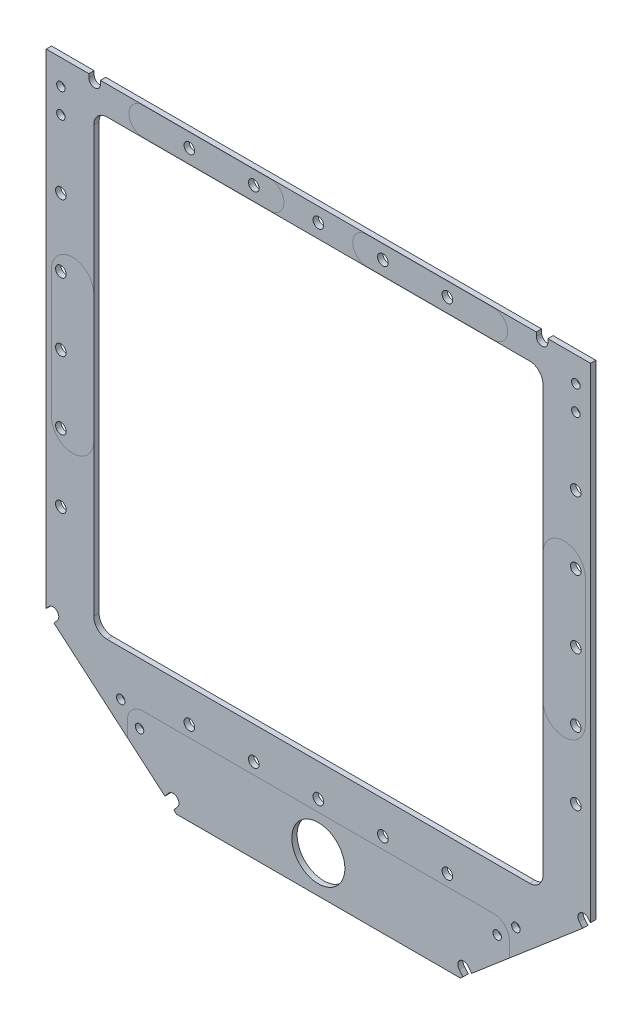
SolidWorks part; units mm, degrees
ref_plane "Front" through (0, 0, 0) normal (0, 0, 1) x (1, 0, 0)
ref_plane "Top" through (0, 0, 0) normal (0, 1, 0) x (1, 0, 0)
ref_plane "Right" through (0, 0, 0) normal (1, 0, 0) x (0, 0, -1)
sketch "Sketch1" plane through (0, 0, -8.9364) normal (0, 0, 1) x (1, 0, 0)
  line L0 (-62.992, 192.0875) -> (62.992, 192.0875)
  line L1 (-66.675, 183.0705) -> (66.675, 183.0705) construction
  line L2 (-66.675, 48.768) -> (66.675, 48.768) construction
  line L3 (-66.675, 48.768) -> (66.675, 48.768) construction
  line L4 (66.675, 183.0705) -> (66.675, 48.768) construction
  line L5 (62.992, 192.0875) -> (62.992, 187.071)
  line L6 (62.992, 187.071) -> (70.866, 187.071)
  line L7 (70.866, 187.071) -> (70.866, 192.0875)
  line L8 (70.866, 192.0875) -> (81.407, 192.0875)
  line L9 (81.407, 192.0875) -> (81.407, 50.8)
  line L10 (81.407, 50.8) -> (75.438, 50.8)
  line L11 (75.438, 50.8) -> (75.438, 41.4295)
  line L12 (75.438, 41.4295) -> (47.5845, 17.7206)
  line L13 (47.5845, 17.7206) -> (35.3184, 32.131)
  line L14 (35.3184, 32.131) -> (-35.3184, 32.131)
  line L15 (-67.183, 183.5785) -> (67.183, 183.5785)
  line L16 (67.183, 183.5785) -> (67.183, 48.26)
  line L17 (-67.183, 48.26) -> (67.183, 48.26)
  line L18 (-67.183, 48.26) -> (67.183, 48.26) construction
  line L19 (81.915, 162.3536) -> (81.915, 172.6784) construction
  line L20 (0, 194.183) -> (0, 11.7602) construction
  line L22 (46.5936, 16.2101) -> (78.9144, 43.7216) construction
  line L23 (-67.183, 183.5785) -> (67.183, 183.5785) construction
  line L24 (-66.675, 183.0705) -> (66.675, 183.0705) construction
  line L25 (-66.675, 183.0705) -> (-66.675, 48.768) construction
  line L26 (-67.183, 183.5785) -> (-67.183, 48.26) construction
  line L27 (33.1388, 192.5955) -> (24.7732, 192.5955) construction
  line L28 (81.915, 192.5955) -> (69.6786, 192.5955) construction
  line L29 (-43.2308, 13.3477) -> (43.2308, 13.3477) construction
  line L34 (-66.675, 183.0705) -> (-66.675, 48.768) construction
  line L35 (-67.183, 183.5785) -> (-67.183, 48.26)
  line L36 (-47.5845, 17.7206) -> (-35.3184, 32.131)
  line L37 (-75.438, 41.4295) -> (-47.5845, 17.7206)
  line L38 (-75.438, 50.8) -> (-75.438, 41.4295)
  line L39 (-81.407, 50.8) -> (-75.438, 50.8)
  line L40 (-81.407, 192.0875) -> (-81.407, 50.8)
  line L41 (-70.866, 192.0875) -> (-81.407, 192.0875)
  line L42 (-70.866, 187.071) -> (-70.866, 192.0875)
  line L43 (-62.992, 187.071) -> (-70.866, 187.071)
  line L44 (-62.992, 192.0875) -> (-62.992, 187.071)
  circle A0 centre (79.375, 46.863) radius 3.937 construction
  circle A3 centre (43.434, 16.5227) radius 3.937 construction
  circle A5 centre (66.929, 191.008) radius 3.937 construction
  circle A7 centre (-66.929, 191.008) radius 3.937 construction
  circle A8 centre (-43.434, 16.5227) radius 3.937 construction
  circle A9 centre (-79.375, 46.863) radius 3.937 construction
  point P29 (0, 183.5785)
  point P30 (0, 183.0705)
  point P66 (0, 48.768)
  point P67 (0, 48.26)
  point P69 (0, 32.131)
  point P78 (0, 192.0875)
  dimension "D6" = 18.7833
  dimension "D1" = 0.508
  dimension "D2" = 0.508
  dimension "D3" = 0.508
  dimension "D4" = 0.508
  dimension "D5" = 0.508
extrude "Boss-Extrude1" add sketch "Sketch1" along normal blind 1.5875
sketch "Sketch2" plane through (0, 0, -7.3489) normal (0, 0, 1) x (1, 0, 0)
  line L2 (67.1735, 135.763) -> (67.1735, 97.663)
  line L3 (79.8735, 97.663) -> (79.8735, 135.763)
  line L4 (67.1735, 135.763) -> (67.1735, 97.663)
  line L5 (79.8735, 97.663) -> (79.8735, 135.763)
  line L6 (-67.1735, 97.663) -> (-67.1735, 135.763)
  line L7 (-79.8735, 135.763) -> (-79.8735, 97.663)
  line L8 (-67.1735, 97.663) -> (-67.1735, 135.763)
  line L9 (-79.8735, 135.763) -> (-79.8735, 97.663)
  line L14 (-57.15, 23.111) -> (-48.4599, 15.7139)
  line L15 (-57.15, 30.2895) -> (-57.15, 23.111)
  line L16 (52.3875, 35.052) -> (-52.3875, 35.052)
  line L17 (57.15, 23.111) -> (57.15, 30.2895)
  line L18 (48.4599, 15.7139) -> (57.15, 23.111)
  line L19 (-33.8657, 12.3825) -> (33.8657, 12.3825)
  line L20 (-57.15, 23.111) -> (-48.4599, 15.7139)
  line L21 (-57.15, 30.2895) -> (-57.15, 23.111)
  line L22 (52.3875, 35.052) -> (-52.3875, 35.052)
  line L23 (57.15, 23.111) -> (57.15, 30.2895)
  line L24 (48.4599, 15.7139) -> (57.15, 23.111)
  line L25 (-33.8657, 12.3825) -> (33.8657, 12.3825)
  line L52 (14.4145, 183.7055) -> (52.5145, 183.7055)
  line L53 (52.5145, 191.9605) -> (14.4145, 191.9605)
  line L54 (14.4145, 183.7055) -> (52.5145, 183.7055)
  line L55 (52.5145, 191.9605) -> (14.4145, 191.9605)
  line L56 (-14.4145, 191.9605) -> (-52.5145, 191.9605)
  line L57 (-52.5145, 183.7055) -> (-14.4145, 183.7055)
  line L58 (-14.4145, 191.9605) -> (-52.5145, 191.9605)
  line L59 (-52.5145, 183.7055) -> (-14.4145, 183.7055)
  arc A4 (73.5235, 91.313) -> (79.8735, 97.663) centre (73.5235, 97.663) ccw
  arc A5 (67.1735, 97.663) -> (73.5235, 91.313) centre (73.5235, 97.663) ccw
  arc A6 (73.5235, 142.113) -> (67.1735, 135.763) centre (73.5235, 135.763) ccw
  arc A7 (79.8735, 135.763) -> (73.5235, 142.113) centre (73.5235, 135.763) ccw
  arc A8 (73.5235, 91.313) -> (79.8735, 97.663) centre (73.5235, 97.663) ccw
  arc A9 (67.1735, 97.663) -> (73.5235, 91.313) centre (73.5235, 97.663) ccw
  arc A10 (73.5235, 142.113) -> (67.1735, 135.763) centre (73.5235, 135.763) ccw
  arc A11 (79.8735, 135.763) -> (73.5235, 142.113) centre (73.5235, 135.763) ccw
  arc A12 (-73.5235, 91.313) -> (-67.1735, 97.663) centre (-73.5235, 97.663) ccw
  arc A13 (-79.8735, 97.663) -> (-73.5235, 91.313) centre (-73.5235, 97.663) ccw
  arc A14 (-73.5235, 142.113) -> (-79.8735, 135.763) centre (-73.5235, 135.763) ccw
  arc A15 (-67.1735, 135.763) -> (-73.5235, 142.113) centre (-73.5235, 135.763) ccw
  arc A16 (-73.5235, 91.313) -> (-67.1735, 97.663) centre (-73.5235, 97.663) ccw
  arc A17 (-79.8735, 97.663) -> (-73.5235, 91.313) centre (-73.5235, 97.663) ccw
  arc A18 (-73.5235, 142.113) -> (-79.8735, 135.763) centre (-73.5235, 135.763) ccw
  arc A19 (-67.1735, 135.763) -> (-73.5235, 142.113) centre (-73.5235, 135.763) ccw
  arc A24 (-52.3875, 35.052) -> (-57.15, 30.2895) centre (-52.3875, 30.2895) ccw
  arc A25 (57.15, 30.2895) -> (52.3875, 35.052) centre (52.3875, 30.2895) ccw
  arc A26 (48.2498, 16.8359) -> (48.4599, 15.7139) centre (53.0023, 17.145) ccw
  arc A27 (48.2498, 16.8359) -> (38.6182, 16.8359) centre (43.434, 16.5227) ccw
  arc A28 (33.8657, 12.3825) -> (38.6182, 16.8359) centre (33.8657, 17.145) ccw
  arc A29 (-38.6182, 16.8359) -> (-33.8657, 12.3825) centre (-33.8657, 17.145) ccw
  arc A30 (-38.6182, 16.8359) -> (-48.2498, 16.8359) centre (-43.434, 16.5227) ccw
  arc A31 (-48.4599, 15.7139) -> (-48.2498, 16.8359) centre (-53.0023, 17.145) ccw
  arc A32 (-52.3875, 35.052) -> (-57.15, 30.2895) centre (-52.3875, 30.2895) ccw
  arc A33 (57.15, 30.2895) -> (52.3875, 35.052) centre (52.3875, 30.2895) ccw
  arc A34 (48.2498, 16.8359) -> (48.4599, 15.7139) centre (53.0023, 17.145) ccw
  arc A35 (48.2498, 16.8359) -> (38.6182, 16.8359) centre (43.434, 16.5227) ccw
  arc A36 (33.8657, 12.3825) -> (38.6182, 16.8359) centre (33.8657, 17.145) ccw
  arc A37 (-38.6182, 16.8359) -> (-33.8657, 12.3825) centre (-33.8657, 17.145) ccw
  arc A38 (-38.6182, 16.8359) -> (-48.2498, 16.8359) centre (-43.434, 16.5227) ccw
  arc A39 (-48.4599, 15.7139) -> (-48.2498, 16.8359) centre (-53.0023, 17.145) ccw
  arc A82 (14.4145, 191.9605) -> (14.4145, 183.7055) centre (14.4145, 187.833) ccw
  arc A83 (52.5145, 183.7055) -> (52.5145, 191.9605) centre (52.5145, 187.833) ccw
  arc A84 (14.4145, 191.9605) -> (14.4145, 183.7055) centre (14.4145, 187.833) ccw
  arc A85 (52.5145, 183.7055) -> (52.5145, 191.9605) centre (52.5145, 187.833) ccw
  arc A86 (-14.4145, 183.7055) -> (-14.4145, 191.9605) centre (-14.4145, 187.833) ccw
  arc A87 (-52.5145, 191.9605) -> (-52.5145, 183.7055) centre (-52.5145, 187.833) ccw
  arc A88 (-14.4145, 183.7055) -> (-14.4145, 191.9605) centre (-14.4145, 187.833) ccw
  arc A89 (-52.5145, 191.9605) -> (-52.5145, 183.7055) centre (-52.5145, 187.833) ccw
  dimension "D1" = 0
  dimension "D2" = 0
  dimension "D3" = 0
  dimension "D4" = 0
  dimension "D5" = 0
split line "Split Line1"
sketch "Sketch3" plane through (0, 0, -8.9364) normal (0, 0, -1) x (-1, 0, 0)
  line L0 (81.407, 50.8) -> (81.407, 46.5104)
  line L1 (75.438, 41.4295) -> (81.407, 46.5104)
  line L3 (75.438, 41.4295) -> (75.438, 50.8)
  line L4 (75.438, 50.8) -> (81.407, 50.8)
  line L5 (47.5845, 17.7206) -> (42.4471, 13.3477)
  line L6 (70.866, 187.071) -> (62.992, 187.071)
  line L7 (70.866, 187.071) -> (70.866, 192.0875)
  line L8 (70.866, 192.0875) -> (62.992, 192.0875)
  line L9 (62.992, 187.071) -> (62.992, 192.0875)
  line L10 (0, 32.131) -> (0, 13.3477)
  line L12 (-42.4471, 13.3477) -> (42.4471, 13.3477)
  line L14 (-35.3184, 32.131) -> (35.3184, 32.131)
  line L15 (35.3184, 32.131) -> (47.5845, 17.7206)
  line L16 (-35.3184, 32.131) -> (-47.5845, 17.7206)
  line L17 (-62.992, 187.071) -> (-62.992, 192.0875)
  line L18 (-70.866, 192.0875) -> (-62.992, 192.0875)
  line L19 (-70.866, 187.071) -> (-70.866, 192.0875)
  line L20 (-70.866, 187.071) -> (-62.992, 187.071)
  line L21 (-47.5845, 17.7206) -> (-42.4471, 13.3477)
  line L22 (-75.438, 50.8) -> (-81.407, 50.8)
  line L23 (-75.438, 41.4295) -> (-75.438, 50.8)
  line L24 (-75.438, 41.4295) -> (-81.407, 46.5104)
  line L25 (-81.407, 50.8) -> (-81.407, 46.5104)
extrude "Boss-Extrude4" add sketch "Sketch3" against normal through all contours L10 L12 L5 | L21 L12 L10 | L1 L0 | L25 L24 | L18 | L8 region at (-78.0525, 47.2275, -8.9364) region at (-21.2873, 22.341, -8.9364) region at (21.2873, 22.341, -8.9364) region at (-66.929, 189.5793, -8.9364) region at (66.929, 189.5793, -8.9364) region at (78.0525, 47.2275, -8.9364)
sketch "Sketch5" plane through (0, 0, -8.9364) normal (0, 0, 1) x (1, 0, 0)
  line L0 (81.407, 46.5104) -> (81.407, 192.0875) construction
  line L1 (81.407, 46.5104) -> (84.407, 49.064)
  line L2 (81.407, 46.5104) -> (81.407, 195.0875)
  line L3 (81.407, 195.0875) -> (84.407, 195.0875)
  line L4 (84.407, 49.064) -> (84.407, 195.0875)
  line L5 (42.4471, 13.3477) -> (81.407, 46.5104) construction
  line L6 (81.407, 192.0875) -> (-81.407, 192.0875) construction
  line L7 (-81.407, 192.0875) -> (-81.407, 195.0875)
  line L8 (-81.407, 192.0875) -> (81.407, 192.0875)
  line L9 (0, 192.0875) -> (0, 195.0875)
  line L10 (-81.407, 195.0875) -> (81.407, 195.0875)
  line L11 (81.407, 192.0875) -> (81.407, 195.0875)
  line L12 (-84.407, 49.064) -> (-84.407, 195.0875)
  line L13 (-81.407, 195.0875) -> (-84.407, 195.0875)
  line L14 (-81.407, 46.5104) -> (-81.407, 195.0875)
  line L15 (-81.407, 46.5104) -> (-84.407, 49.064)
  dimension "D2" = 3
  dimension "D1" = 3
extrude "Boss-Extrude5" add sketch "Sketch5" against normal through all rebuild error yes
sketch "Sketch4" plane through (0, 0, -8.9364) normal (0, 0, -1) x (-1, 0, 0)
  line L0 (43.434, 16.5227) -> (45.739, 13.8148) construction
  line L1 (44.7492, 17.6422) -> (47.0542, 14.9343)
  line L2 (42.1188, 15.4032) -> (44.4237, 12.6952)
  line L3 (48.0029, 18.0768) -> (42.4471, 13.3477) construction
  line L4 (79.375, 46.863) -> (81.4305, 44.4481) construction
  line L5 (80.6902, 47.9825) -> (82.7458, 45.5677)
  line L6 (78.0598, 45.7435) -> (80.1153, 43.3286)
  line L7 (81.407, 46.5104) -> (57.15, 25.8628) construction
  line L8 (66.929, 191.008) -> (66.929, 199.167) construction
  line L9 (65.2018, 191.008) -> (65.2018, 199.167)
  line L10 (68.6562, 191.008) -> (68.6562, 199.167)
  line L12 (-84.407, 195.0875) -> (84.407, 195.0875) construction
  line L13 (-67.183, 183.5785) -> (67.183, 183.5785) construction
  line L14 (0, 13.3477) -> (0, 195.0875) construction
  line L15 (-42.4471, 13.3477) -> (42.4471, 13.3477) construction
  line L16 (-43.434, 16.5227) -> (-45.739, 13.8148) construction
  line L17 (-44.7492, 17.6422) -> (-47.0542, 14.9343)
  line L18 (-42.1188, 15.4032) -> (-44.4237, 12.6952)
  line L19 (-79.375, 46.863) -> (-81.4305, 44.4481) construction
  line L20 (-80.6902, 47.9825) -> (-82.7458, 45.5677)
  line L21 (-78.0598, 45.7435) -> (-80.1153, 43.3286)
  line L22 (-66.929, 191.008) -> (-66.929, 199.167) construction
  line L23 (-65.2018, 191.008) -> (-65.2018, 199.167)
  line L24 (-68.6562, 191.008) -> (-68.6562, 199.167)
  arc A0 (44.7492, 17.6422) -> (42.1188, 15.4032) centre (43.434, 16.5227) ccw
  arc A1 (44.4237, 12.6952) -> (47.0542, 14.9343) centre (45.739, 13.8148) ccw
  circle A2 centre (43.434, 16.5227) radius 1.7272 construction
  arc A3 (80.6902, 47.9825) -> (78.0598, 45.7435) centre (79.375, 46.863) ccw
  arc A4 (80.1153, 43.3286) -> (82.7458, 45.5677) centre (81.4305, 44.4481) ccw
  circle A5 centre (79.375, 46.863) radius 1.7272 construction
  arc A6 (65.2018, 191.008) -> (68.6562, 191.008) centre (66.929, 191.008) ccw
  arc A7 (68.6562, 199.167) -> (65.2018, 199.167) centre (66.929, 199.167) ccw
  circle A8 centre (66.929, 191.008) radius 1.7272 construction
  arc A9 (-44.7492, 17.6422) -> (-42.1188, 15.4032) centre (-43.434, 16.5227) cw
  arc A10 (-44.4237, 12.6952) -> (-47.0542, 14.9343) centre (-45.739, 13.8148) cw
  arc A11 (-80.6902, 47.9825) -> (-78.0598, 45.7435) centre (-79.375, 46.863) cw
  arc A12 (-80.1153, 43.3286) -> (-82.7458, 45.5677) centre (-81.4305, 44.4481) cw
  arc A13 (-65.2018, 191.008) -> (-68.6562, 191.008) centre (-66.929, 191.008) cw
  arc A14 (-68.6562, 199.167) -> (-65.2018, 199.167) centre (-66.929, 199.167) cw
  point P2 (44.5865, 15.1687)
  point P12 (80.4028, 45.6556)
  point P27 (66.929, 195.0875)
  point P44 (-44.5865, 15.1687)
  point P51 (-80.4028, 45.6556)
  point P58 (-66.929, 195.0875)
extrude "Cut-Extrude1" cut sketch "Sketch4" against normal through all
sketch "Sketch6" plane through (0, 0, -8.9364) normal (0, 0, -1) x (-1, 0, 0)
  circle A2 centre (38.608, 38.481) radius 1.5875
  circle A3 centre (19.304, 38.481) radius 1.5875
  circle A4 centre (0, 38.481) radius 1.5875
  circle A5 centre (-19.304, 38.481) radius 1.5875
  circle A6 centre (-38.608, 38.481) radius 1.5875
  circle A9 centre (-77.0255, 75.692) radius 1.5875
  circle A10 centre (-77.0255, 96.012) radius 1.5875
  circle A11 centre (-77.0255, 116.332) radius 1.5875
  circle A12 centre (-77.0255, 136.652) radius 1.5875
  circle A13 centre (-77.0255, 156.972) radius 1.5875
  circle A16 centre (-38.608, 187.833) radius 1.5875
  circle A17 centre (-19.304, 187.833) radius 1.5875
  circle A18 centre (0, 187.833) radius 1.5875
  circle A19 centre (19.304, 187.833) radius 1.5875
  circle A20 centre (38.608, 187.833) radius 1.5875
  circle A23 centre (77.0255, 156.972) radius 1.5875
  circle A24 centre (77.0255, 136.652) radius 1.5875
  circle A25 centre (77.0255, 116.332) radius 1.5875
  circle A26 centre (77.0255, 96.012) radius 1.5875
  circle A27 centre (77.0255, 75.692) radius 1.5875
  point P0 (77.0255, 156.972)
  point P6 (38.608, 187.833)
  point P8 (19.304, 187.833)
  point P10 (-38.608, 187.833)
  point P12 (-19.304, 187.833)
  point P14 (0, 187.833)
  point P16 (77.0255, 75.692)
  point P18 (77.0255, 96.012)
  point P20 (77.0255, 116.332)
  point P22 (77.0255, 136.652)
  point P28 (-38.608, 38.481)
  point P30 (-19.304, 38.481)
  point P32 (0, 38.481)
  point P34 (19.304, 38.481)
  point P36 (38.608, 38.481)
  point P46 (-77.0255, 156.972)
  point P48 (-77.0255, 136.652)
  point P50 (-77.0255, 116.332)
  point P52 (-77.0255, 96.012)
  point P54 (-77.0255, 75.692)
extrude "Cut-Extrude2" cut sketch "Sketch6" against normal through all
fillet "Fillet1" radius 4 4 edges at (-67.183, 183.5785, -8.1426) (67.183, 183.5785, -8.1426) (67.183, 48.26, -8.1426) (-67.183, 48.26, -8.1426)
sketch "Sketch7" plane through (0, 0, -8.9364) normal (0, 0, -1) x (-1, 0, 0)
  line L0 (63.574, 184.2406) -> (64.1599, 185.7918) construction
  line L1 (64.1599, 185.7918) -> (62.988, 185.7918) construction
  line L2 (62.988, 185.7918) -> (63.574, 184.2406) construction
  line L3 (69.4055, 183.8325) -> (69.4055, 186.3725) construction
  line L4 (68.6435, 187.1345) -> (57.4675, 187.1345) construction
  line L5 (56.7055, 186.3725) -> (56.7055, 183.8325) construction
  line L6 (57.4675, 183.0705) -> (68.6435, 183.0705) construction
  line L7 (63.574, 184.2406) -> (64.1599, 185.7918)
  line L8 (64.1599, 185.7918) -> (62.988, 185.7918)
  line L9 (62.988, 185.7918) -> (63.574, 184.2406)
  line L10 (69.4055, 183.8325) -> (69.4055, 186.3725)
  line L11 (68.6435, 187.1345) -> (57.4675, 187.1345)
  line L12 (56.7055, 186.3725) -> (56.7055, 183.8325)
  line L13 (57.4675, 183.0705) -> (68.6435, 183.0705)
  line L17 (-61.5637, 183.8089) -> (-61.5633, 183.8097) construction
  line L18 (61.4031, 186.5254) -> (61.4031, 183.6686)
  line L19 (61.7659, 183.6839) -> (61.7652, 186.5251)
  line L20 (61.4031, 186.5254) -> (61.4031, 183.6686)
  line L21 (58.9604, 185.8548) -> (60.4424, 183.5881)
  line L22 (58.9611, 183.712) -> (58.9604, 185.8548)
  line L23 (58.553, 186.5211) -> (58.5523, 183.6932)
  line L24 (60.4375, 184.3387) -> (58.9604, 186.6204)
  line L25 (60.4375, 186.516) -> (60.4375, 184.3387)
  line L26 (60.8463, 183.7033) -> (60.8456, 186.4853)
  line L27 (58.9604, 185.8548) -> (60.4424, 183.5881)
  line L28 (58.9611, 183.712) -> (58.9604, 185.8548)
  line L29 (58.553, 186.5211) -> (58.5523, 183.6932)
  line L30 (60.4375, 184.3387) -> (58.9604, 186.6204)
  line L31 (60.4375, 186.516) -> (60.4375, 184.3387)
  line L32 (60.8463, 183.7033) -> (60.8456, 186.4853)
  line L33 (61.7659, 183.6839) -> (61.7652, 186.5251)
  line L34 (-56.7055, 183.8325) -> (-56.7055, 186.3725) construction
  line L35 (-57.4675, 187.1345) -> (-68.6435, 187.1345) construction
  line L36 (-69.4055, 186.3725) -> (-69.4055, 183.8325) construction
  line L37 (65.8574, 185.2803) -> (65.8574, 185.7969)
  line L38 (62.8241, 186.1999) -> (62.6801, 186.5871)
  line L39 (64.3139, 186.1999) -> (62.8241, 186.1999)
  line L40 (64.473, 186.6116) -> (64.3139, 186.1999)
  line L41 (63.7876, 183.6042) -> (64.8502, 186.4155)
  line L42 (62.2781, 186.4499) -> (63.3505, 183.6494)
  line L43 (62.8241, 186.1999) -> (62.6801, 186.5871)
  line L44 (64.3139, 186.1999) -> (62.8241, 186.1999)
  line L45 (64.473, 186.6116) -> (64.3139, 186.1999)
  line L46 (63.7876, 183.6042) -> (64.8502, 186.4155)
  line L47 (62.2781, 186.4499) -> (63.3505, 183.6494)
  line L48 (66.2181, 185.281) -> (65.8574, 185.2803)
  line L49 (65.7166, 184.8722) -> (66.1979, 184.8722)
  line L50 (65.4501, 185.9276) -> (65.4494, 185.1492)
  line L51 (65.8574, 185.2803) -> (65.8574, 185.7969)
  line L52 (66.2181, 185.281) -> (65.8574, 185.2803)
  line L53 (65.7166, 184.8722) -> (66.1979, 184.8722)
  line L54 (65.4501, 185.9276) -> (65.4494, 185.1492)
  line L55 (-68.6435, 183.0705) -> (-57.4675, 183.0705) construction
  line L56 (-61.5637, 183.8089) -> (-61.5633, 183.8097)
  line L57 (-56.7055, 183.8325) -> (-56.7055, 186.3725)
  line L58 (-57.4675, 187.1345) -> (-68.6435, 187.1345)
  line L59 (-69.4055, 186.3725) -> (-69.4055, 183.8325)
  line L60 (-68.6435, 183.0705) -> (-57.4675, 183.0705)
  line L62 (-58.946, 183.4476) -> (-58.9464, 183.4469)
  line L63 (-58.946, 183.4476) -> (-58.9464, 183.4469)
  line L66 (-61.5633, 183.4016) -> (-61.5637, 183.4009)
  line L67 (-61.5633, 183.4016) -> (-61.5637, 183.4009)
  line L69 (-8.4611, 29.7565) -> (-7.6566, 29.7565) construction
  line L70 (-67.3978, 183.8549) -> (-68.0632, 183.8549)
  line L71 (-67.3978, 186.5002) -> (-67.3978, 183.8549)
  line L72 (-66.9897, 183.8549) -> (-66.9897, 186.4751)
  line L73 (-66.3187, 183.8556) -> (-66.9897, 183.8549)
  line L74 (-68.0774, 183.4476) -> (-66.3441, 183.4469)
  line L75 (-67.3978, 183.8549) -> (-68.0632, 183.8549)
  line L76 (-67.3978, 186.5002) -> (-67.3978, 183.8549)
  line L77 (-66.9897, 183.8549) -> (-66.9897, 186.4751)
  line L78 (-66.3187, 183.8556) -> (-66.9897, 183.8549)
  line L79 (-68.0774, 183.4476) -> (-66.3441, 183.4469)
  line L80 (-7.6566, 29.7565) -> (-7.6566, 30.9577) construction
  line L81 (-65.1505, 185.8548) -> (-63.6685, 183.5881)
  line L82 (-65.1498, 183.712) -> (-65.1505, 185.8548)
  line L83 (-65.5578, 186.5211) -> (-65.5586, 183.6932)
  line L84 (-63.6734, 184.3387) -> (-65.1505, 186.6204)
  line L85 (-63.6734, 186.516) -> (-63.6734, 184.3387)
  line L86 (-63.2646, 183.7033) -> (-63.2653, 186.4853)
  line L87 (-65.1505, 185.8548) -> (-63.6685, 183.5881)
  line L88 (-65.1498, 183.712) -> (-65.1505, 185.8548)
  line L89 (-65.5578, 186.5211) -> (-65.5586, 183.6932)
  line L90 (-63.6734, 184.3387) -> (-65.1505, 186.6204)
  line L91 (-63.6734, 186.516) -> (-63.6734, 184.3387)
  line L92 (-63.2646, 183.7033) -> (-63.2653, 186.4853)
  line L93 (-7.6566, 30.9577) -> (-8.4157, 30.9577) construction
  line L94 (-8.5703, 28.469) -> (-7.6913, 28.469) construction
  line L95 (-37.2245, 25.8054) -> (-37.2245, 28.3454)
  line L96 (-37.9865, 29.1074) -> (-46.1145, 29.1074)
  line L97 (-46.8765, 28.3454) -> (-46.8765, 25.8054)
  line L98 (-46.1145, 25.0434) -> (-37.9865, 25.0434)
  line L99 (-44.7633, 26.9798) -> (-43.9134, 25.5695)
  line L100 (-45.6133, 25.5513) -> (-44.7633, 26.9798)
  line L101 (-46.0012, 28.499) -> (-46.0019, 25.6357)
  line L102 (-45.5939, 26.4037) -> (-45.5939, 28.4745)
  line L103 (-44.9868, 27.412) -> (-45.5939, 26.4037)
  line L104 (-43.9328, 26.4037) -> (-44.5495, 27.4367)
  line L105 (-43.9328, 28.4653) -> (-43.9328, 26.4037)
  line L106 (-43.524, 25.6892) -> (-43.5248, 28.4547)
  line L107 (-44.7633, 26.9798) -> (-43.9134, 25.5695)
  line L108 (-45.6133, 25.5513) -> (-44.7633, 26.9798)
  line L109 (-46.0012, 28.499) -> (-46.0019, 25.6357)
  line L110 (-45.5939, 26.4037) -> (-45.5939, 28.4745)
  line L111 (-44.9868, 27.412) -> (-45.5939, 26.4037)
  line L112 (-43.9328, 26.4037) -> (-44.5495, 27.4367)
  line L113 (-43.9328, 28.4653) -> (-43.9328, 26.4037)
  line L114 (-43.524, 25.6892) -> (-43.5248, 28.4547)
  line L115 (-42.5585, 25.5613) -> (-41.8412, 26.9144)
  line L116 (-39.2259, 25.4198) -> (-38.9059, 25.4354)
  line L117 (-39.2551, 25.4205) -> (-39.2259, 25.4198)
  line L118 (-39.1812, 25.8256) -> (-39.2061, 25.8256)
  line L119 (-38.9325, 25.8307) -> (-39.1812, 25.8256)
  line L120 (-39.4275, 26.8502) -> (-38.891, 26.7399)
  line L121 (-38.9059, 28.7246) -> (-39.2289, 28.7246)
  line L122 (-38.3735, 27.8144) -> (-38.3742, 27.7743)
  line L123 (-39.2069, 28.3259) -> (-38.9108, 28.3256)
  line L124 (-38.7917, 27.1441) -> (-39.3259, 27.2579)
  line L125 (-39.2259, 25.4198) -> (-38.9059, 25.4354)
  line L126 (-39.2551, 25.4205) -> (-39.2259, 25.4198)
  line L127 (-39.1812, 25.8256) -> (-39.2061, 25.8256)
  line L128 (-38.9325, 25.8307) -> (-39.1812, 25.8256)
  line L129 (-39.4275, 26.8502) -> (-38.891, 26.7399)
  line L130 (-38.9059, 28.7246) -> (-39.2289, 28.7246)
  line L131 (-38.3735, 27.8144) -> (-38.3742, 27.7743)
  line L132 (-39.2069, 28.3259) -> (-38.9108, 28.3256)
  line L133 (-38.7917, 27.1441) -> (-39.3259, 27.2579)
  line L134 (-41.8412, 26.9144) -> (-41.133, 25.5814)
  line L135 (-40.7451, 25.7424) -> (-40.7556, 25.7618)
  line L136 (-40.7556, 25.7618) -> (-41.6396, 27.4156)
  line L137 (-41.6396, 27.4156) -> (-41.6396, 28.4931)
  line L138 (-42.0476, 28.4782) -> (-42.0476, 27.4156)
  line L139 (-42.0476, 27.4156) -> (-42.9068, 25.7818)
  line L140 (-42.9068, 25.7818) -> (-42.9167, 25.7668)
  line L141 (-42.5585, 25.5613) -> (-41.8412, 26.9144)
  line L142 (-41.8412, 26.9144) -> (-41.133, 25.5814)
  line L143 (-40.7451, 25.7424) -> (-40.7556, 25.7618)
  line L144 (-40.7556, 25.7618) -> (-41.6396, 27.4156)
  line L145 (-41.6396, 27.4156) -> (-41.6396, 28.4931)
  line L146 (-42.0476, 28.4782) -> (-42.0476, 27.4156)
  line L147 (-42.0476, 27.4156) -> (-42.9068, 25.7818)
  line L148 (-42.9068, 25.7818) -> (-42.9167, 25.7668)
  line L149 (-37.2245, 25.8054) -> (-37.2245, 28.3454)
  line L150 (-37.9865, 29.1074) -> (-46.1145, 29.1074)
  line L151 (-46.8765, 28.3454) -> (-46.8765, 25.8054)
  line L152 (-46.1145, 25.0434) -> (-37.9865, 25.0434)
  line L153 (-6.35, 28.4466) -> (-6.35, 30.9866)
  line L154 (-7.112, 31.7486) -> (-15.24, 31.7486)
  line L155 (-16.002, 30.9866) -> (-16.002, 28.4466)
  line L156 (-15.24, 27.6846) -> (-7.112, 27.6846)
  line L157 (-6.35, 28.4466) -> (-6.35, 30.9866)
  line L158 (-7.112, 31.7486) -> (-15.24, 31.7486)
  line L159 (-16.002, 30.9866) -> (-16.002, 28.4466)
  line L160 (-15.24, 27.6846) -> (-7.112, 27.6846)
  line L161 (-7.6913, 28.469) -> (-7.6913, 29.3484) construction
  line L162 (-7.6913, 29.3484) -> (-8.5795, 29.3484) construction
  line L163 (-11.1624, 28.469) -> (-10.4145, 28.469) construction
  line L164 (-10.4145, 28.469) -> (-10.4145, 29.5783) construction
  line L165 (-10.4145, 29.5783) -> (-11.1264, 29.5783) construction
  line L166 (-8.4611, 29.7565) -> (-7.6566, 29.7565)
  line L167 (-7.6566, 29.7565) -> (-7.6566, 30.9577)
  line L168 (-7.6566, 30.9577) -> (-8.4157, 30.9577)
  line L169 (-8.5703, 28.469) -> (-7.6913, 28.469)
  line L170 (-7.6913, 28.469) -> (-7.6913, 29.3484)
  line L171 (-7.6913, 29.3484) -> (-8.5795, 29.3484)
  line L172 (-11.1624, 28.469) -> (-10.4145, 28.469)
  line L173 (-10.4145, 28.469) -> (-10.4145, 29.5783)
  line L174 (-10.4145, 29.5783) -> (-11.1264, 29.5783)
  line L177 (73.2934, 39.1971) -> (73.2934, 41.7371) construction
  line L178 (-8.6148, 28.0617) -> (-7.4977, 28.061)
  line L179 (-7.244, 28.3124) -> (-7.2444, 31.1052)
  line L180 (-7.5026, 31.3658) -> (-8.4213, 31.3658)
  line L181 (-8.6148, 28.0617) -> (-7.4977, 28.061)
  line L182 (-7.244, 28.3124) -> (-7.2444, 31.1052)
  line L183 (-7.5026, 31.3658) -> (-8.4213, 31.3658)
  line L184 (72.5314, 42.4991) -> (64.4034, 42.4991) construction
  line L185 (63.6414, 41.7371) -> (63.6414, 39.1971) construction
  line L186 (64.4034, 38.4351) -> (72.5314, 38.4351) construction
  line L187 (46.8765, 25.8054) -> (46.8765, 28.3454) construction
  line L188 (-12.1028, 30.9951) -> (-11.3595, 29.9718)
  line L189 (-10.8541, 29.9864) -> (-11.7779, 31.2353)
  line L190 (-10.4145, 29.9864) -> (-10.8541, 29.9864)
  line L191 (-10.4145, 31.0978) -> (-10.4145, 29.9864)
  line L192 (-10.0057, 28.3476) -> (-10.0064, 31.078)
  line L193 (-11.1465, 28.0617) -> (-10.3063, 28.061)
  line L194 (-12.1028, 30.9951) -> (-11.3595, 29.9718)
  line L195 (-10.8541, 29.9864) -> (-11.7779, 31.2353)
  line L196 (-10.4145, 29.9864) -> (-10.8541, 29.9864)
  line L197 (-10.4145, 31.0978) -> (-10.4145, 29.9864)
  line L198 (-10.0057, 28.3476) -> (-10.0064, 31.078)
  line L199 (-11.1465, 28.0617) -> (-10.3063, 28.061)
  line L200 (-14.0009, 28.469) -> (-14.6664, 28.469)
  line L201 (-14.0009, 31.1143) -> (-14.0009, 28.469)
  line L202 (-13.5928, 28.469) -> (-13.5928, 31.0892)
  line L203 (-12.9218, 28.4697) -> (-13.5928, 28.469)
  line L204 (-14.6806, 28.0617) -> (-12.9473, 28.061)
  line L205 (-14.0009, 28.469) -> (-14.6664, 28.469)
  line L206 (-14.0009, 31.1143) -> (-14.0009, 28.469)
  line L207 (-13.5928, 28.469) -> (-13.5928, 31.0892)
  line L208 (-12.9218, 28.4697) -> (-13.5928, 28.469)
  line L209 (-14.6806, 28.0617) -> (-12.9473, 28.061)
  line L210 (46.1145, 29.1074) -> (37.9865, 29.1074) construction
  line L211 (37.2245, 28.3454) -> (37.2245, 25.8054) construction
  line L212 (37.9865, 25.0434) -> (46.1145, 25.0434) construction
  line L213 (16.002, 28.4466) -> (16.002, 30.9866) construction
  line L214 (15.24, 31.7486) -> (7.112, 31.7486) construction
  line L215 (6.35, 30.9866) -> (6.35, 28.4466) construction
  line L216 (7.112, 27.6846) -> (15.24, 27.6846) construction
  line L217 (73.2934, 39.1971) -> (73.2934, 41.7371)
  line L218 (72.5314, 42.4991) -> (64.4034, 42.4991)
  line L219 (63.6414, 41.7371) -> (63.6414, 39.1971)
  line L220 (64.4034, 38.4351) -> (72.5314, 38.4351)
  line L221 (46.8765, 25.8054) -> (46.8765, 28.3454)
  line L222 (46.1145, 29.1074) -> (37.9865, 29.1074)
  line L223 (37.2245, 28.3454) -> (37.2245, 25.8054)
  line L224 (37.9865, 25.0434) -> (46.1145, 25.0434)
  line L225 (16.002, 28.4466) -> (16.002, 30.9866)
  line L226 (15.24, 31.7486) -> (7.112, 31.7486)
  line L227 (6.35, 30.9866) -> (6.35, 28.4466)
  line L228 (7.112, 27.6846) -> (15.24, 27.6846)
  line L231 (45.2473, 25.8279) -> (45.8008, 25.8279) construction
  line L232 (45.8008, 25.8279) -> (45.8008, 28.3166) construction
  line L233 (45.8008, 28.3166) -> (45.2526, 28.3166) construction
  line L234 (42.1322, 26.2135) -> (42.7181, 27.7648) construction
  line L235 (67.8438, 40.6449) -> (67.8438, 41.1615)
  line L236 (65.5505, 39.2195) -> (64.8851, 39.2195)
  line L237 (65.5505, 41.8648) -> (65.5505, 39.2195)
  line L238 (65.9586, 39.2195) -> (65.9586, 41.8397)
  line L239 (66.6296, 39.2202) -> (65.9586, 39.2195)
  line L240 (64.8709, 38.8122) -> (66.6042, 38.8114)
  line L241 (65.5505, 39.2195) -> (64.8851, 39.2195)
  line L242 (65.5505, 41.8648) -> (65.5505, 39.2195)
  line L243 (65.9586, 39.2195) -> (65.9586, 41.8397)
  line L244 (66.6296, 39.2202) -> (65.9586, 39.2195)
  line L245 (64.8709, 38.8122) -> (66.6042, 38.8114)
  line L246 (68.2044, 40.6456) -> (67.8438, 40.6449)
  line L247 (67.703, 40.2368) -> (68.1843, 40.2368)
  line L248 (67.4364, 41.2922) -> (67.4357, 40.5137)
  line L249 (67.8438, 40.6449) -> (67.8438, 41.1615)
  line L250 (68.2044, 40.6456) -> (67.8438, 40.6449)
  line L251 (67.703, 40.2368) -> (68.1843, 40.2368)
  line L252 (67.4364, 41.2922) -> (67.4357, 40.5137)
  line L253 (42.7181, 27.7648) -> (41.5462, 27.7648) construction
  line L254 (41.5462, 27.7648) -> (42.1322, 26.2135) construction
  line L255 (70.6026, 41.2194) -> (72.0846, 38.9527)
  line L256 (70.6033, 39.0765) -> (70.6026, 41.2194)
  line L257 (70.1952, 41.8857) -> (70.1945, 39.0578)
  line L258 (72.0797, 39.7033) -> (70.6026, 41.985)
  line L259 (72.0797, 41.8806) -> (72.0797, 39.7033)
  line L260 (72.4885, 39.0679) -> (72.4878, 41.8499)
  line L261 (70.6026, 41.2194) -> (72.0846, 38.9527)
  line L262 (70.6033, 39.0765) -> (70.6026, 41.2194)
  line L263 (70.1952, 41.8857) -> (70.1945, 39.0578)
  line L264 (72.0797, 39.7033) -> (70.6026, 41.985)
  line L265 (72.0797, 41.8806) -> (72.0797, 39.7033)
  line L266 (72.4885, 39.0679) -> (72.4878, 41.8499)
  line L267 (45.2473, 25.8279) -> (45.8008, 25.8279)
  line L268 (45.8008, 25.8279) -> (45.8008, 28.3166)
  line L269 (45.8008, 28.3166) -> (45.2526, 28.3166)
  line L270 (42.1322, 26.2135) -> (42.7181, 27.7648)
  line L271 (42.7181, 27.7648) -> (41.5462, 27.7648)
  line L272 (41.5462, 27.7648) -> (42.1322, 26.2135)
  line L278 (46.2096, 25.6777) -> (46.2089, 28.4247)
  line L279 (45.2627, 25.4205) -> (45.9434, 25.4198)
  line L280 (41.3823, 28.1729) -> (41.2383, 28.56)
  line L281 (42.8721, 28.1729) -> (41.3823, 28.1729)
  line L282 (43.0312, 28.5845) -> (42.8721, 28.1729)
  line L283 (39.2022, 26.9144) -> (39.9103, 25.5814)
  line L284 (38.4849, 25.5613) -> (39.2022, 26.9144)
  line L285 (38.1366, 25.7818) -> (38.1267, 25.7668)
  line L286 (38.9957, 27.4156) -> (38.1366, 25.7818)
  line L287 (38.9957, 28.4782) -> (38.9957, 27.4156)
  line L288 (39.4038, 27.4156) -> (39.4038, 28.4931)
  line L289 (40.2877, 25.7618) -> (39.4038, 27.4156)
  line L290 (40.2982, 25.7424) -> (40.2877, 25.7618)
  line L291 (39.2022, 26.9144) -> (39.9103, 25.5814)
  line L292 (38.4849, 25.5613) -> (39.2022, 26.9144)
  line L293 (38.1366, 25.7818) -> (38.1267, 25.7668)
  line L294 (38.9957, 27.4156) -> (38.1366, 25.7818)
  line L295 (38.9957, 28.4782) -> (38.9957, 27.4156)
  line L296 (39.4038, 27.4156) -> (39.4038, 28.4931)
  line L297 (40.2877, 25.7618) -> (39.4038, 27.4156)
  line L298 (40.2982, 25.7424) -> (40.2877, 25.7618)
  line L299 (42.3458, 25.5771) -> (43.4084, 28.3885)
  line L300 (40.8363, 28.4229) -> (41.9087, 25.6223)
  line L301 (41.3823, 28.1729) -> (41.2383, 28.56)
  line L302 (42.8721, 28.1729) -> (41.3823, 28.1729)
  line L303 (43.0312, 28.5845) -> (42.8721, 28.1729)
  line L304 (42.3458, 25.5771) -> (43.4084, 28.3885)
  line L305 (40.8363, 28.4229) -> (41.9087, 25.6223)
  line L306 (45.9538, 28.7246) -> (45.2523, 28.7246)
  line L307 (46.2096, 25.6777) -> (46.2089, 28.4247)
  line L308 (45.2627, 25.4205) -> (45.9434, 25.4198)
  line L309 (45.9538, 28.7246) -> (45.2523, 28.7246)
  line L311 (14.0246, 28.0157) -> (14.0243, 28.015)
  line L312 (14.0246, 28.0157) -> (14.0243, 28.015)
  line L313 (14.0243, 28.4231) -> (14.0246, 28.4238)
  line L314 (14.0243, 28.4231) -> (14.0246, 28.4238)
  line L317 (9.1557, 29.3024) -> (9.1557, 28.469)
  line L318 (9.1557, 28.469) -> (7.5865, 28.469)
  line L319 (7.5867, 28.0617) -> (9.2723, 28.061)
  line L320 (9.5645, 28.3383) -> (9.5638, 31.0979)
  line L321 (9.1557, 31.0985) -> (9.1557, 29.7105)
  line L322 (9.1557, 29.7105) -> (8.0533, 29.7105)
  line L323 (8.0386, 29.3024) -> (9.1557, 29.3024)
  line L324 (9.1557, 29.3024) -> (9.1557, 28.469)
  line L325 (9.1557, 28.469) -> (7.5865, 28.469)
  line L326 (7.5867, 28.0617) -> (9.2723, 28.061)
  line L327 (9.5645, 28.3383) -> (9.5638, 31.0979)
  line L328 (9.1557, 31.0985) -> (9.1557, 29.7105)
  line L329 (9.1557, 29.7105) -> (8.0533, 29.7105)
  line L330 (8.0386, 29.3024) -> (9.1557, 29.3024)
  line L331 (11.9146, 28.469) -> (10.3453, 28.469)
  line L332 (11.9146, 29.3024) -> (11.9146, 28.469)
  line L333 (10.7974, 29.3024) -> (11.9146, 29.3024)
  line L334 (11.9146, 29.7105) -> (10.8121, 29.7105)
  line L335 (11.9146, 31.0985) -> (11.9146, 29.7105)
  line L336 (12.3234, 28.3383) -> (12.3226, 31.0979)
  line L337 (10.3455, 28.0617) -> (12.0312, 28.061)
  line L338 (11.9146, 28.469) -> (10.3453, 28.469)
  line L339 (11.9146, 29.3024) -> (11.9146, 28.469)
  line L340 (10.7974, 29.3024) -> (11.9146, 29.3024)
  line L341 (11.9146, 29.7105) -> (10.8121, 29.7105)
  line L342 (11.9146, 31.0985) -> (11.9146, 29.7105)
  line L343 (12.3234, 28.3383) -> (12.3226, 31.0979)
  line L344 (10.3455, 28.0617) -> (12.0312, 28.061)
  arc A0 (69.4055, 186.3725) -> (68.6435, 187.1345) centre (68.6435, 186.3725) ccw construction
  arc A1 (57.4675, 187.1345) -> (56.7055, 186.3725) centre (57.4675, 186.3725) ccw construction
  arc A2 (56.7055, 183.8325) -> (57.4675, 183.0705) centre (57.4675, 183.8325) ccw construction
  arc A3 (68.6435, 183.0705) -> (69.4055, 183.8325) centre (68.6435, 183.8325) ccw construction
  arc A4 (69.4055, 186.3725) -> (68.6435, 187.1345) centre (68.6435, 186.3725) ccw
  arc A5 (57.4675, 187.1345) -> (56.7055, 186.3725) centre (57.4675, 186.3725) ccw
  arc A6 (56.7055, 183.8325) -> (57.4675, 183.0705) centre (57.4675, 183.8325) ccw
  arc A7 (68.6435, 183.0705) -> (69.4055, 183.8325) centre (68.6435, 183.8325) ccw
  arc A8 (-56.7055, 186.3725) -> (-57.4675, 187.1345) centre (-57.4675, 186.3725) ccw construction
  arc A9 (-68.6435, 187.1345) -> (-69.4055, 186.3725) centre (-68.6435, 186.3725) ccw construction
  arc A10 (-69.4055, 183.8325) -> (-68.6435, 183.0705) centre (-68.6435, 183.8325) ccw construction
  arc A11 (-57.4675, 183.0705) -> (-56.7055, 183.8325) centre (-57.4675, 183.8325) ccw construction
  arc A12 (-56.7055, 186.3725) -> (-57.4675, 187.1345) centre (-57.4675, 186.3725) ccw
  arc A13 (-68.6435, 187.1345) -> (-69.4055, 186.3725) centre (-68.6435, 186.3725) ccw
  arc A14 (-69.4055, 183.8325) -> (-68.6435, 183.0705) centre (-68.6435, 183.8325) ccw
  arc A15 (-57.4675, 183.0705) -> (-56.7055, 183.8325) centre (-57.4675, 183.8325) ccw
  arc A16 (73.2934, 41.7371) -> (72.5314, 42.4991) centre (72.5314, 41.7371) ccw construction
  arc A17 (64.4034, 42.4991) -> (63.6414, 41.7371) centre (64.4034, 41.7371) ccw construction
  arc A18 (63.6414, 39.1971) -> (64.4034, 38.4351) centre (64.4034, 39.1971) ccw construction
  arc A19 (72.5314, 38.4351) -> (73.2934, 39.1971) centre (72.5314, 39.1971) ccw construction
  arc A20 (-37.2245, 28.3454) -> (-37.9865, 29.1074) centre (-37.9865, 28.3454) ccw
  arc A21 (-46.1145, 29.1074) -> (-46.8765, 28.3454) centre (-46.1145, 28.3454) ccw
  arc A22 (-46.8765, 25.8054) -> (-46.1145, 25.0434) centre (-46.1145, 25.8054) ccw
  arc A23 (-37.9865, 25.0434) -> (-37.2245, 25.8054) centre (-37.9865, 25.8054) ccw
  arc A24 (-37.2245, 28.3454) -> (-37.9865, 29.1074) centre (-37.9865, 28.3454) ccw
  arc A25 (-46.1145, 29.1074) -> (-46.8765, 28.3454) centre (-46.1145, 28.3454) ccw
  arc A26 (-46.8765, 25.8054) -> (-46.1145, 25.0434) centre (-46.1145, 25.8054) ccw
  arc A27 (-37.9865, 25.0434) -> (-37.2245, 25.8054) centre (-37.9865, 25.8054) ccw
  arc A28 (-6.35, 30.9866) -> (-7.112, 31.7486) centre (-7.112, 30.9866) ccw
  arc A29 (-15.24, 31.7486) -> (-16.002, 30.9866) centre (-15.24, 30.9866) ccw
  arc A30 (-16.002, 28.4466) -> (-15.24, 27.6846) centre (-15.24, 28.4466) ccw
  arc A31 (-7.112, 27.6846) -> (-6.35, 28.4466) centre (-7.112, 28.4466) ccw
  arc A32 (-6.35, 30.9866) -> (-7.112, 31.7486) centre (-7.112, 30.9866) ccw
  arc A33 (-15.24, 31.7486) -> (-16.002, 30.9866) centre (-15.24, 30.9866) ccw
  arc A34 (-16.002, 28.4466) -> (-15.24, 27.6846) centre (-15.24, 28.4466) ccw
  arc A35 (-7.112, 27.6846) -> (-6.35, 28.4466) centre (-7.112, 28.4466) ccw
  arc A36 (46.8765, 28.3454) -> (46.1145, 29.1074) centre (46.1145, 28.3454) ccw construction
  arc A37 (37.9865, 29.1074) -> (37.2245, 28.3454) centre (37.9865, 28.3454) ccw construction
  arc A38 (37.2245, 25.8054) -> (37.9865, 25.0434) centre (37.9865, 25.8054) ccw construction
  arc A39 (46.1145, 25.0434) -> (46.8765, 25.8054) centre (46.1145, 25.8054) ccw construction
  arc A40 (16.002, 30.9866) -> (15.24, 31.7486) centre (15.24, 30.9866) ccw construction
  arc A41 (7.112, 31.7486) -> (6.35, 30.9866) centre (7.112, 30.9866) ccw construction
  arc A42 (6.35, 28.4466) -> (7.112, 27.6846) centre (7.112, 28.4466) ccw construction
  arc A43 (15.24, 27.6846) -> (16.002, 28.4466) centre (15.24, 28.4466) ccw construction
  arc A44 (73.2934, 41.7371) -> (72.5314, 42.4991) centre (72.5314, 41.7371) ccw
  arc A45 (64.4034, 42.4991) -> (63.6414, 41.7371) centre (64.4034, 41.7371) ccw
  arc A46 (63.6414, 39.1971) -> (64.4034, 38.4351) centre (64.4034, 39.1971) ccw
  arc A47 (72.5314, 38.4351) -> (73.2934, 39.1971) centre (72.5314, 39.1971) ccw
  arc A48 (46.8765, 28.3454) -> (46.1145, 29.1074) centre (46.1145, 28.3454) ccw
  arc A49 (37.9865, 29.1074) -> (37.2245, 28.3454) centre (37.9865, 28.3454) ccw
  arc A50 (37.2245, 25.8054) -> (37.9865, 25.0434) centre (37.9865, 25.8054) ccw
  arc A51 (46.1145, 25.0434) -> (46.8765, 25.8054) centre (46.1145, 25.8054) ccw
  arc A52 (16.002, 30.9866) -> (15.24, 31.7486) centre (15.24, 30.9866) ccw
  arc A53 (7.112, 31.7486) -> (6.35, 30.9866) centre (7.112, 30.9866) ccw
  arc A54 (6.35, 28.4466) -> (7.112, 27.6846) centre (7.112, 28.4466) ccw
  arc A55 (15.24, 27.6846) -> (16.002, 28.4466) centre (15.24, 28.4466) ccw
  spline S1 degree 3 poles (-2060.9662, 114.6238) (-40.0668, 197.045) (-62.8233, 190.3975) (-62.2812, 184.7118) (-62.256, 184.5543) (-62.2198, 184.4104) (-62.1719, 184.2808) (-62.1133, 184.1652) (-60.2252, 181.345) (-38.9371, 194.8944) (-1586.2951, -1110.5951) knots -14.192716 -14.192716 -14.192716 -14.192716 0.158526 0.305347 0.441073 0.567265 0.685246 0.79486 0.899135 9.346667 9.346667 9.346667 9.346667 only from (-62.299, 185.0641) to (-61.9613, 183.9771) construction
  spline S2 degree 3 poles (-1183.7708, -1471.7168) (-52.1725, 208.8122) (-64.4759, 185.19) (-61.7895, 183.8637) (-61.7192, 183.8355) (-61.666, 183.8214) (-59.6517, 183.4296) (-55.7145, 200.2421) (-279.8476, -1804.2146) knots -19.639677 -19.639677 -19.639677 -19.639677 0.250469 0.51191 0.643201 0.766782 0.88624 14.600826 14.600826 14.600826 14.600826 only from (-61.9613, 183.9771) to (-61.5637, 183.8089) construction
  spline S3 degree 3 poles (139.9329, -1805.9341) (-67.7526, 200.6272) (-63.6865, 183.3957) (-61.4468, 183.824) (-61.3866, 183.8423) (-61.3256, 183.8662) (-61.2668, 183.8964) (-61.2109, 183.9298) (-59.1953, 185.4862) (-68.7943, 199.8259) (1287.4092, -1292.8857) knots -13.208851 -13.208851 -13.208851 -13.208851 0.113234 0.23097 0.35623 0.488401 0.62135 0.750283 0.876638 15.774538 15.774538 15.774538 15.774538 only from (-61.5633, 183.8097) to (-61.1157, 184.0123) construction
  spline S4 degree 3 poles (1529.2656, -1028.6427) (-83.3755, 193.1891) (-62.6319, 181.4526) (-60.9865, 184.1907) (-60.9362, 184.3022) (-60.8954, 184.4279) (-60.8626, 184.5658) (-60.8389, 184.7152) (-60.3458, 190.674) (-80.2159, 197.3733) (1938.1997, 124.8845) knots -8.395909 -8.395909 -8.395909 -8.395909 0.095962 0.198413 0.309334 0.43022 0.559678 0.697123 0.843875 16.916019 16.916019 16.916019 16.916019 only from (-61.1157, 184.0123) to (-60.8226, 185.0432) construction
  spline S5 degree 3 poles (1938.563, 231.4545) (-79.4898, 172.4719) (-60.4148, 179.209) (-60.8352, 185.366) (-60.8529, 185.5104) (-60.8777, 185.6426) (-60.9104, 185.7637) (-60.9526, 185.8738) (-62.3835, 188.9039) (-83.6755, 180.291) (1661.0309, 1202.8617) knots -16.918383 -16.918383 -16.918383 -16.918383 0.159126 0.307102 0.442974 0.568572 0.685342 0.795643 0.899956 10.089803 10.089803 10.089803 10.089803 only from (-60.8226, 185.0432) to (-61.0611, 186.0649) construction
  spline S6 degree 3 poles (1453.2842, 1492.4679) (-72.5948, 169.055) (-59.2036, 184.2756) (-61.1636, 186.1799) (-61.2236, 186.2279) (-61.2886, 186.2683) (-61.356, 186.3017) (-61.4251, 186.3242) (-63.6491, 186.864) (-68.654, 165.8114) (189.5185, 2170.4807) knots -13.360319 -13.360319 -13.360319 -13.360319 0.130585 0.259601 0.387732 0.517475 0.645012 0.766137 0.883696 12.141978 12.141978 12.141978 12.141978 only from (-61.0611, 186.0649) to (-61.5633, 186.3436) construction
  spline S7 degree 3 poles (634.0507, -2761.3118) (52.8552, 210.4569) (60.0274, 182.8332) (61.6718, 183.4676) (63.2155, 184.4942) (45.6599, 206.3177) (2093.6762, -2023.4563) knots -27.313779 -27.313779 -27.313779 -27.313779 0.252822 0.495908 0.737887 29.837654 29.837654 29.837654 29.837654 only from (61.582, 183.4476) to (61.7422, 183.5295)
  spline S8 degree 3 poles (-2927.6163, -71.3863) (85.0565, 190.1761) (60.9935, 185.8089) (61.4131, 183.5717) (61.427, 183.5325) (61.4469, 183.5003) (61.4724, 183.4748) (61.5047, 183.4585) (63.0604, 183.0011) (68.1033, 209.8444) (-315.1292, -2792.7291) knots -20.42692 -20.42692 -20.42692 -20.42692 0.162439 0.303775 0.43068 0.542576 0.650112 0.75758 0.872008 15.427503 15.427503 15.427503 15.427503 only from (61.4031, 183.6686) to (61.582, 183.4476)
  spline S9 degree 3 poles (-2812.7895, 1046.1941) (80.8634, 184.0132) (61.7071, 188.1231) (61.4064, 186.6123) (61.1715, 184.0305) (82.2734, 180.727) (-2936.9518, 281.5898) knots -30.745733 -30.745733 -30.745733 -30.745733 0.196636 0.386764 0.637659 53.125625 53.125625 53.125625 53.125625 only from (61.4225, 186.6698) to (61.4031, 186.5254)
  spline S10 degree 3 poles (-2354.4704, -1596.2355) (70.8131, 197.9447) (58.7592, 185.6309) (60.4933, 183.5217) (60.5186, 183.4969) (60.5509, 183.4718) (62.2221, 182.6629) (70.9044, 215.9096) (-539.9847, -2755.7089) knots -30.226628 -30.226628 -30.226628 -30.226628 0.169217 0.3203 0.451757 0.567066 0.78044 20.788458 20.788458 20.788458 20.788458 only from (60.4424, 183.5881) to (60.6545, 183.4476)
  spline S11 degree 3 poles (341.4538, -2803.0295) (52.3339, 209.2977) (56.8781, 182.9894) (58.8481, 183.4591) (58.8856, 183.4779) (58.9149, 183.5061) (58.9372, 183.5431) (58.9516, 183.5903) (59.3625, 186.4909) (35.5194, 190.9031) (3053.4305, 3.6899) knots -15.092741 -15.092741 -15.092741 -15.092741 0.130999 0.246717 0.350533 0.449564 0.555403 0.679484 0.826682 23.026266 23.026266 23.026266 23.026266 only from (58.7542, 183.4476) to (58.9611, 183.712)
  spline S12 degree 3 poles (-2931.1199, -63.5997) (83.0846, 190.6004) (58.123, 186.0184) (58.5628, 183.5839) (58.5774, 183.5393) (58.5997, 183.5034) (58.6294, 183.476) (58.6652, 183.4572) (60.464, 183.0209) (64.4283, 210.3849) (-170.3088, -2807.6715) knots -19.673523 -19.673523 -19.673523 -19.673523 0.16208 0.304988 0.429155 0.54241 0.64608 0.754429 0.869073 15.567801 15.567801 15.567801 15.567801 only from (58.5523, 183.6932) to (58.7542, 183.4476)
  spline S13 degree 3 poles (-333.2927, 3160.9025) (65.6243, 161.6446) (60.41, 187.227) (58.666, 186.7388) (58.6314, 186.721) (58.6032, 186.6947) (58.5811, 186.6613) (58.5659, 186.6205) (58.0809, 184.3594) (82.1351, 179.2655) (-2922.175, 525.5674) knots -15.293159 -15.293159 -15.293159 -15.293159 0.129823 0.246796 0.357906 0.465733 0.578613 0.704189 0.842964 20.653431 20.653431 20.653431 20.653431 only from (58.7492, 186.7517) to (58.553, 186.5211)
  spline S14 degree 3 poles (2273.7002, 2209.9997) (37.6917, 160.8409) (60.7528, 185.2173) (58.8655, 186.7219) (57.1589, 187.5382) (48.1299, 154.9784) (698.2415, 3117.6613) knots -26.821069 -26.821069 -26.821069 -26.821069 0.290623 0.542214 0.774801 21.665796 21.665796 21.665796 21.665796 only from (58.9604, 186.6204) to (58.7492, 186.7517)
  spline S15 degree 3 poles (-298.4063, 3165.0883) (67.419, 162.0839) (62.4227, 187.2481) (60.5572, 186.7378) (60.5215, 186.7184) (60.4912, 186.6924) (60.4689, 186.6576) (60.4514, 186.617) (59.9441, 184.2623) (83.3985, 179.5073) (-2924.9908, 480.3362) knots -15.820097 -15.820097 -15.820097 -15.820097 0.13213 0.251966 0.362464 0.472906 0.585187 0.708511 0.845513 20.817744 20.817744 20.817744 20.817744 only from (60.6444, 186.7517) to (60.4375, 186.516)
  spline S16 degree 3 poles (2284.4242, 2200.378) (40.5978, 163.4754) (62.2564, 185.6148) (60.7527, 186.7267) (58.851, 187.4719) (50.8255, 157.7189) (647.0665, 3128.7656) knots -24.700307 -24.700307 -24.700307 -24.700307 0.247683 0.484068 0.729372 28.110364 28.110364 28.110364 28.110364 only from (60.8262, 186.6511) to (60.6444, 186.7517)
  spline S17 degree 3 poles (3059.7529, 110.3551) (44.6469, 179.0025) (61.0087, 182.6131) (60.8434, 186.5891) (60.5506, 188.0913) (41.6855, 183.7715) (2922.5546, 1086.0415) knots -70.077425 -70.077425 -70.077425 -70.077425 0.379232 0.640476 0.832404 27.539273 27.539273 27.539273 27.539273 only from (60.8456, 186.4853) to (60.8262, 186.6511)
  spline S18 degree 3 poles (2992.7544, -450.7416) (42.2736, 185.0736) (60.7172, 182.3699) (60.8456, 183.6173) (60.8308, 187.939) (73.7403, 192.3088) (-2939.0071, 183.5322) knots -26.929115 -26.929115 -26.929115 -26.929115 0.164011 0.339607 0.5985 95.506401 95.506401 95.506401 95.506401 only from (60.8362, 183.5683) to (60.8463, 183.7033)
  spline S19 degree 3 poles (846.6393, -2711.7148) (48.3404, 214.9642) (59.0868, 182.607) (60.7676, 183.4799) (62.1065, 184.5545) (34.9121, 206.5463) (2482.1003, -1587.5458) knots -23.411252 -23.411252 -23.411252 -23.411252 0.257226 0.515442 0.763924 21.964106 21.964106 21.964106 21.964106 only from (60.6545, 183.4476) to (60.8362, 183.5683)
  spline S20 degree 3 poles (60.4424, 183.5881) (60.4512, 183.5759) (60.4677, 183.5527) (60.4933, 183.5217) (60.5186, 183.4969) (60.5509, 183.4718) (60.596, 183.45) (60.6348, 183.4484) (60.6545, 183.4476) knots 0 0 0 0 0.169217 0.3203 0.451757 0.567066 0.78044 1 1 1 1
  spline S21 degree 3 poles (58.7542, 183.4476) (58.7713, 183.4479) (58.8034, 183.4485) (58.8481, 183.4591) (58.8856, 183.4779) (58.9149, 183.5061) (58.9372, 183.5431) (58.9516, 183.5903) (58.9598, 183.6477) (58.9606, 183.6894) (58.9611, 183.712) knots 0 0 0 0 0.130999 0.246717 0.350533 0.449564 0.555403 0.679484 0.826682 1 1 1 1
  spline S22 degree 3 poles (58.5523, 183.6932) (58.5527, 183.6733) (58.5535, 183.6359) (58.5628, 183.5839) (58.5774, 183.5393) (58.5997, 183.5034) (58.6294, 183.476) (58.6652, 183.4572) (58.7079, 183.4469) (58.7381, 183.4473) (58.7542, 183.4476) knots 0 0 0 0 0.16208 0.304988 0.429155 0.54241 0.64608 0.754429 0.869073 1 1 1 1
  spline S23 degree 3 poles (58.7492, 186.7517) (58.7342, 186.7511) (58.7058, 186.75) (58.666, 186.7388) (58.6314, 186.721) (58.6032, 186.6947) (58.5811, 186.6613) (58.5659, 186.6205) (58.5557, 186.573) (58.554, 186.5391) (58.553, 186.5211) knots 0 0 0 0 0.129823 0.246796 0.357906 0.465733 0.578613 0.704189 0.842964 1 1 1 1
  spline S24 degree 3 poles (58.9604, 186.6204) (58.9458, 186.6411) (58.9185, 186.6796) (58.8655, 186.7219) (58.8088, 186.749) (58.7688, 186.7508) (58.7492, 186.7517) knots 0 0 0 0 0.290623 0.542214 0.774801 1 1 1 1
  spline S25 degree 3 poles (60.6444, 186.7517) (60.6288, 186.7508) (60.599, 186.7492) (60.5572, 186.7378) (60.5215, 186.7184) (60.4912, 186.6924) (60.4689, 186.6576) (60.4514, 186.617) (60.441, 186.5687) (60.4387, 186.5343) (60.4375, 186.516) knots 0 0 0 0 0.13213 0.251966 0.362464 0.472906 0.585187 0.708511 0.845513 1 1 1 1
  spline S26 degree 3 poles (60.8262, 186.6511) (60.8159, 186.6659) (60.7958, 186.6949) (60.7527, 186.7267) (60.7014, 186.7469) (60.664, 186.75) (60.6444, 186.7517) knots 0 0 0 0 0.247683 0.484068 0.729372 1 1 1 1
  spline S27 degree 3 poles (60.8456, 186.4853) (60.8455, 186.5066) (60.8454, 186.5425) (60.8434, 186.5891) (60.8367, 186.6235) (60.8295, 186.6423) (60.8262, 186.6511) knots 0 0 0 0 0.379232 0.640476 0.832404 1 1 1 1
  spline S28 degree 3 poles (60.8362, 183.5683) (60.8384, 183.5754) (60.8428, 183.5902) (60.8456, 183.6173) (60.8455, 183.6552) (60.846, 183.6851) (60.8463, 183.7033) knots 0 0 0 0 0.164011 0.339607 0.5985 1 1 1 1
  spline S29 degree 3 poles (60.6545, 183.4476) (60.6745, 183.4492) (60.7145, 183.4524) (60.7676, 183.4799) (60.8134, 183.5167) (60.8288, 183.5514) (60.8362, 183.5683) knots 0 0 0 0 0.257226 0.515442 0.763924 1 1 1 1
  spline S30 degree 3 poles (-600.7225, 3112.6375) (71.2003, 159.3931) (63.0842, 187.3928) (61.4899, 186.7299) (60.1484, 185.9338) (79.5011, 162.9798) (-1988.2239, 2377.1149) knots -26.817188 -26.817188 -26.817188 -26.817188 0.252909 0.513256 0.767106 24.996833 24.996833 24.996833 24.996833 only from (61.582, 186.7517) to (61.4225, 186.6698)
  spline S31 degree 3 poles (2372.4803, 2099.7985) (40.2684, 164.7231) (63.0167, 185.713) (61.6851, 186.7252) (59.9325, 187.482) (51.2833, 158.5145) (735.9093, 3109.8778) knots -23.024071 -23.024071 -23.024071 -23.024071 0.230334 0.479964 0.74004 27.576449 27.576449 27.576449 27.576449 only from (61.7515, 186.6511) to (61.582, 186.7517)
  spline S32 degree 3 poles (3032.4871, -230.6732) (50.6806, 178.8704) (61.8188, 181.9742) (61.7649, 186.6053) (61.5451, 187.7747) (42.5234, 182.8035) (2912.7765, 1119.6846) knots -107.661335 -107.661335 -107.661335 -107.661335 0.400719 0.653819 0.825724 28.115408 28.115408 28.115408 28.115408 only from (61.7652, 186.5251) to (61.7515, 186.6511)
  spline S33 degree 3 poles (2845.9938, -933.2517) (40.7607, 189.2039) (61.4612, 182.3113) (61.7624, 183.5856) (61.9837, 187.1279) (44.2093, 190.8638) (3061.5237, 160.3136) knots -24.006763 -24.006763 -24.006763 -24.006763 0.170737 0.353675 0.609135 67.427842 67.427842 67.427842 67.427842 only from (61.7422, 183.5295) to (61.7659, 183.6839)
  spline S34 degree 3 poles (61.582, 183.4476) (61.5977, 183.4487) (61.6285, 183.4509) (61.6718, 183.4676) (61.7108, 183.4936) (61.7314, 183.5172) (61.7422, 183.5295) knots 0 0 0 0 0.252822 0.495908 0.737887 1 1 1 1
  spline S35 degree 3 poles (61.4031, 183.6686) (61.4035, 183.6509) (61.4044, 183.6178) (61.4131, 183.5717) (61.427, 183.5325) (61.4469, 183.5003) (61.4724, 183.4748) (61.5047, 183.4585) (61.5415, 183.4476) (61.568, 183.4476) (61.582, 183.4476) knots 0 0 0 0 0.162439 0.303775 0.43068 0.542576 0.650112 0.75758 0.872008 1 1 1 1
  spline S36 degree 3 poles (61.4225, 186.6698) (61.4191, 186.6608) (61.4125, 186.643) (61.4064, 186.6123) (61.4028, 186.5731) (61.403, 186.5431) (61.4031, 186.5254) knots 0 0 0 0 0.196636 0.386764 0.637659 1 1 1 1
  spline S37 degree 3 poles (61.582, 186.7517) (61.5662, 186.7506) (61.5343, 186.7484) (61.4899, 186.7299) (61.4494, 186.7059) (61.4312, 186.6815) (61.4225, 186.6698) knots 0 0 0 0 0.252909 0.513256 0.767106 1 1 1 1
  spline S38 degree 3 poles (61.7515, 186.6511) (61.7434, 186.6649) (61.7266, 186.6937) (61.6851, 186.7252) (61.6358, 186.7465) (61.5999, 186.75) (61.582, 186.7517) knots 0 0 0 0 0.230334 0.479964 0.74004 1 1 1 1
  spline S39 degree 3 poles (61.7652, 186.5251) (61.7652, 186.5422) (61.7653, 186.5701) (61.7649, 186.6053) (61.7601, 186.6306) (61.7544, 186.6442) (61.7515, 186.6511) knots 0 0 0 0 0.400719 0.653819 0.825724 1 1 1 1
  spline S40 degree 3 poles (61.7422, 183.5295) (61.7464, 183.5375) (61.755, 183.5541) (61.7624, 183.5856) (61.7652, 183.6293) (61.7656, 183.6633) (61.7659, 183.6839) knots 0 0 0 0 0.170737 0.353675 0.609135 1 1 1 1
  spline S41 degree 3 poles (-248.1645, 2177.5658) (-55.354, 169.0461) (-59.3907, 186.7669) (-61.685, 186.3289) (-61.7463, 186.3088) (-61.8078, 186.2833) (-61.8674, 186.2513) (-61.9234, 186.214) (-63.9565, 184.567) (-53.8251, 169.964) (-1434.6567, 1640.6034) knots -13.059845 -13.059845 -13.059845 -13.059845 0.11493 0.234385 0.357558 0.486319 0.61793 0.7474 0.874017 15.673341 15.673341 15.673341 15.673341 only from (-61.5633, 186.3436) to (-62.0209, 186.1252) construction
  spline S42 degree 3 poles (2761.0149, 1497.6127) (43.793, 172.9935) (63.68, 184.9295) (62.6434, 186.662) (62.6217, 186.6922) (62.5958, 186.7154) (62.5684, 186.7338) (62.5385, 186.7464) (60.9013, 187.0284) (58.3493, 165.3799) (184.113, 3184.2482) knots -20.64813 -20.64813 -20.64813 -20.64813 0.155712 0.294933 0.423708 0.54252 0.656478 0.767676 0.879718 17.897169 17.897169 17.897169 17.897169 only from (62.6801, 186.5871) to (62.4721, 186.7517)
  spline S43 degree 3 poles (-200.7836, 3174.9166) (69.7787, 164.6108) (66.1694, 187.0793) (64.611, 186.7446) (64.5812, 186.7337) (64.5538, 186.7189) (64.5294, 186.6987) (64.508, 186.6739) (63.5116, 185.23) (82.322, 172.9397) (-2568.4337, 1624.198) knots -17.574891 -17.574891 -17.574891 -17.574891 0.130338 0.252182 0.370626 0.488416 0.604093 0.72711 0.858039 20.395925 20.395925 20.395925 20.395925 only from (64.677, 186.7517) to (64.473, 186.6116)
  spline S44 degree 3 poles (3031.2071, 634.04) (41.1824, 179.5805) (65.4085, 184.9926) (64.8749, 186.64) (64.8537, 186.6722) (64.827, 186.7004) (64.795, 186.7235) (64.7582, 186.739) (63.0249, 187.2125) (57.7301, 162.7874) (485.8135, 3156.914) knots -15.821873 -15.821873 -15.821873 -15.821873 0.127988 0.249904 0.36818 0.490097 0.615322 0.739205 0.865718 17.529007 17.529007 17.529007 17.529007 only from (64.8904, 186.5627) to (64.677, 186.7517)
  spline S45 degree 3 poles (-2836.5383, 948.7609) (70.9031, 177.1154) (63.475, 182.9661) (64.8717, 186.4707) (64.8774, 186.492) (64.8846, 186.5128) (65.1877, 187.8354) (44.9349, 191.1975) (3050.3259, -106.4751) knots -73.087646 -73.087646 -73.087646 -73.087646 0.220157 0.39487 0.541435 0.649468 0.826608 26.870377 26.870377 26.870377 26.870377 only from (64.8502, 186.4155) to (64.8904, 186.5627)
  spline S46 degree 3 poles (190.6247, -2813.6874) (59.6308, 206.3607) (62.1497, 183.1693) (63.6491, 183.4523) (63.6782, 183.4641) (63.7054, 183.4808) (63.7299, 183.5037) (63.7524, 183.5319) (64.8355, 185.4594) (47.5922, 195.6852) (2798.5221, -1049.5199) knots -15.987075 -15.987075 -15.987075 -15.987075 0.1216 0.234761 0.346222 0.458938 0.577979 0.706875 0.847112 24.376234 24.376234 24.376234 24.376234 only from (63.5843, 183.4476) to (63.7876, 183.6042)
  spline S47 degree 3 poles (-2673.017, -1045.9154) (80.643, 197.6428) (62.0683, 186.0996) (63.3955, 183.5507) (63.4194, 183.5141) (63.4456, 183.4869) (63.4741, 183.4668) (63.5074, 183.4552) (65.2551, 183.0957) (69.241, 206.9152) (-209.1528, -2803.9588) knots -25.128617 -25.128617 -25.128617 -25.128617 0.1782 0.330029 0.459111 0.5663 0.664595 0.76729 0.87824 16.500606 16.500606 16.500606 16.500606 only from (63.3505, 183.6494) to (63.5843, 183.4476)
  spline S48 degree 3 poles (-2922.419, -114.6699) (75.8102, 191.7029) (61.987, 188.385) (62.2643, 186.5063) (62.638, 184.6674) (77.4057, 186.5154) (-2842.9333, -561.3174) knots -48.804603 -48.804603 -48.804603 -48.804603 0.225997 0.491418 0.766256 49.197779 49.197779 49.197779 49.197779 only from (62.258, 186.5627) to (62.2781, 186.4499)
  spline S49 degree 3 poles (-365.4533, 3155.9728) (69.4768, 162.2741) (64.0847, 187.2271) (62.3903, 186.7384) (62.3536, 186.7219) (62.3214, 186.699) (62.2945, 186.6707) (62.2741, 186.6383) (61.7294, 185.0888) (86.7199, 178.9326) (-2890.5898, 715.9162) knots -16.202176 -16.202176 -16.202176 -16.202176 0.134406 0.263812 0.388741 0.514081 0.63611 0.756416 0.874147 16.029476 16.029476 16.029476 16.029476 only from (62.4721, 186.7517) to (62.258, 186.5627)
  spline S50 degree 3 poles (62.6801, 186.5871) (62.6746, 186.6009) (62.6642, 186.6272) (62.6434, 186.662) (62.6217, 186.6922) (62.5958, 186.7154) (62.5684, 186.7338) (62.5385, 186.7464) (62.5059, 186.752) (62.4836, 186.7518) (62.4721, 186.7517) knots 0 0 0 0 0.155712 0.294933 0.423708 0.54252 0.656478 0.767676 0.879718 1 1 1 1
  spline S51 degree 3 poles (64.677, 186.7517) (64.6655, 186.7516) (64.6432, 186.7515) (64.611, 186.7446) (64.5812, 186.7337) (64.5538, 186.7189) (64.5294, 186.6987) (64.508, 186.6739) (64.4881, 186.645) (64.4782, 186.623) (64.473, 186.6116) knots 0 0 0 0 0.130338 0.252182 0.370626 0.488416 0.604093 0.72711 0.858039 1 1 1 1
  spline S52 degree 3 poles (64.8904, 186.5627) (64.8892, 186.5762) (64.887, 186.6026) (64.8749, 186.64) (64.8537, 186.6722) (64.827, 186.7004) (64.795, 186.7235) (64.7582, 186.739) (64.7188, 186.7497) (64.6912, 186.751) (64.677, 186.7517) knots 0 0 0 0 0.127988 0.249904 0.36818 0.490097 0.615322 0.739205 0.865718 1 1 1 1
  spline S53 degree 3 poles (64.8502, 186.4155) (64.8542, 186.4261) (64.8615, 186.4449) (64.8717, 186.4707) (64.8774, 186.492) (64.8846, 186.5128) (64.8899, 186.5359) (64.8902, 186.5538) (64.8904, 186.5627) knots 0 0 0 0 0.220157 0.39487 0.541435 0.649468 0.826608 1 1 1 1
  spline S54 degree 3 poles (63.5843, 183.4476) (63.5955, 183.4471) (63.6173, 183.4463) (63.6491, 183.4523) (63.6782, 183.4641) (63.7054, 183.4808) (63.7299, 183.5037) (63.7524, 183.5319) (63.7716, 183.5661) (63.7821, 183.5911) (63.7876, 183.6042) knots 0 0 0 0 0.1216 0.234761 0.346222 0.458938 0.577979 0.706875 0.847112 1 1 1 1
  spline S55 degree 3 poles (63.3505, 183.6494) (63.3579, 183.6308) (63.3717, 183.5964) (63.3955, 183.5507) (63.4194, 183.5141) (63.4456, 183.4869) (63.4741, 183.4668) (63.5074, 183.4552) (63.5444, 183.4476) (63.5706, 183.4476) (63.5843, 183.4476) knots 0 0 0 0 0.1782 0.330029 0.459111 0.5663 0.664595 0.76729 0.87824 1 1 1 1
  spline S56 degree 3 poles (62.258, 186.5627) (62.2586, 186.5541) (62.26, 186.5353) (62.2643, 186.5063) (62.2702, 186.4772) (62.2756, 186.4585) (62.2781, 186.4499) knots 0 0 0 0 0.225997 0.491418 0.766256 1 1 1 1
  spline S57 degree 3 poles (62.4721, 186.7517) (62.4579, 186.7511) (62.43, 186.7498) (62.3903, 186.7384) (62.3536, 186.7219) (62.3214, 186.699) (62.2945, 186.6707) (62.2741, 186.6383) (62.2613, 186.6017) (62.2591, 186.576) (62.258, 186.5627) knots 0 0 0 0 0.134406 0.263812 0.388741 0.514081 0.63611 0.756416 0.874147 1 1 1 1
  spline S58 degree 3 poles (-1696.7174, 1338.2558) (-39.6275, 178.484) (-60.4707, 188.9181) (-62.1476, 185.9353) (-62.1946, 185.8216) (-62.2335, 185.6963) (-62.2634, 185.5581) (-62.2848, 185.4061) (-62.7385, 178.9805) (-43.3043, 171.99) (-2061.7603, 228.161) knots -8.823288 -8.823288 -8.823288 -8.823288 0.098603 0.202113 0.311442 0.427783 0.553323 0.690136 0.838826 17.807604 17.807604 17.807604 17.807604 only from (-62.0209, 186.1252) to (-62.299, 185.0641) construction
  spline S59 degree 3 poles (-62.299, 185.0641) (-62.2985, 185.0022) (-62.2975, 184.8831) (-62.2812, 184.7118) (-62.256, 184.5543) (-62.2198, 184.4104) (-62.1719, 184.2808) (-62.1133, 184.1652) (-62.0447, 184.0627) (-61.9888, 184.0053) (-61.9613, 183.9771) knots 0 0 0 0 0.158526 0.305347 0.441073 0.567265 0.685246 0.79486 0.899135 1 1 1 1
  spline S60 degree 3 poles (-61.9613, 183.9771) (-61.9329, 183.9536) (-61.8747, 183.9058) (-61.7895, 183.8637) (-61.7192, 183.8355) (-61.666, 183.8214) (-61.6146, 183.8114) (-61.5803, 183.8098) (-61.5637, 183.8089) knots 0 0 0 0 0.250469 0.51191 0.643201 0.766782 0.88624 1 1 1 1
  spline S61 degree 3 poles (-61.5633, 183.8097) (-61.5443, 183.8107) (-61.5057, 183.8128) (-61.4468, 183.824) (-61.3866, 183.8423) (-61.3256, 183.8662) (-61.2668, 183.8964) (-61.2109, 183.9298) (-61.1605, 183.9687) (-61.1305, 183.9978) (-61.1157, 184.0123) knots 0 0 0 0 0.113234 0.23097 0.35623 0.488401 0.62135 0.750283 0.876638 1 1 1 1
  spline S62 degree 3 poles (-61.1157, 184.0123) (-61.0926, 184.0387) (-61.0449, 184.0934) (-60.9865, 184.1907) (-60.9362, 184.3022) (-60.8954, 184.4279) (-60.8626, 184.5658) (-60.8389, 184.7152) (-60.8257, 184.8756) (-60.8236, 184.9862) (-60.8226, 185.0432) knots 0 0 0 0 0.095962 0.198413 0.309334 0.43022 0.559678 0.697123 0.843875 1 1 1 1
  spline S63 degree 3 poles (-60.8226, 185.0432) (-60.8232, 185.0998) (-60.8245, 185.2089) (-60.8352, 185.366) (-60.8529, 185.5104) (-60.8777, 185.6426) (-60.9104, 185.7637) (-60.9526, 185.8738) (-61.0005, 185.9751) (-61.0412, 186.0354) (-61.0611, 186.0649) knots 0 0 0 0 0.159126 0.307102 0.442974 0.568572 0.685342 0.795643 0.899956 1 1 1 1
  spline S64 degree 3 poles (-61.0611, 186.0649) (-61.0769, 186.0854) (-61.1084, 186.1262) (-61.1636, 186.1799) (-61.2236, 186.2279) (-61.2886, 186.2683) (-61.356, 186.3017) (-61.4251, 186.3242) (-61.4938, 186.3408) (-61.5402, 186.3427) (-61.5633, 186.3436) knots 0 0 0 0 0.130585 0.259601 0.387732 0.517475 0.645012 0.766137 0.883696 1 1 1 1
  spline S65 degree 3 poles (-61.5633, 186.3436) (-61.5832, 186.3426) (-61.6238, 186.3406) (-61.685, 186.3289) (-61.7463, 186.3088) (-61.8078, 186.2833) (-61.8674, 186.2513) (-61.9234, 186.214) (-61.975, 186.1722) (-62.0057, 186.1408) (-62.0209, 186.1252) knots 0 0 0 0 0.11493 0.234385 0.357558 0.486319 0.61793 0.7474 0.874017 1 1 1 1
  spline S66 degree 3 poles (-62.0209, 186.1252) (-62.0437, 186.0963) (-62.0905, 186.037) (-62.1476, 185.9353) (-62.1946, 185.8216) (-62.2335, 185.6963) (-62.2634, 185.5581) (-62.2848, 185.4061) (-62.2965, 185.2398) (-62.2981, 185.1242) (-62.299, 185.0641) knots 0 0 0 0 0.098603 0.202113 0.311442 0.427783 0.553323 0.690136 0.838826 1 1 1 1
  spline S70 degree 3 poles (-575.3255, -1888.1812) (-7.3908, 47.8946) (-10.5396, 30.1337) (-8.5869, 29.7609) (-5.19, 29.5406) (-1.5488, 44.3077) (-33.1929, -1970.0242) knots -25.48842 -25.48842 -25.48842 -25.48842 0.223184 0.436078 0.677355 45.158306 45.158306 45.158306 45.158306 only from (-8.6844, 29.7874) to (-8.4611, 29.7565) construction
  spline S71 degree 3 poles (-41.1825, 2030.6739) (-1.3985, 18.2351) (-5.0989, 31.1224) (-8.5365, 30.9547) (-8.5884, 30.9498) (-8.6481, 30.9405) (-11.1222, 30.2806) (-5.2947, 8.864) (-757.1048, 1885.5884) knots -26.447708 -26.447708 -26.447708 -26.447708 0.168545 0.320411 0.455875 0.575326 0.792943 20.352406 20.352406 20.352406 20.352406 only from (-8.4157, 30.9577) to (-8.7886, 30.8873) construction
  spline S72 degree 3 poles (-1209.0947, 1630.6149) (7.8548, 17.3363) (-6.9629, 32.5922) (-8.912, 30.7906) (-8.9627, 30.7306) (-9.0055, 30.6637) (-9.0407, 30.5922) (-9.067, 30.5173) (-9.6004, 27.806) (10.5153, 23.0876) (-2000.1356, 218.3746) knots -12.181909 -12.181909 -12.181909 -12.181909 0.12496 0.248147 0.371648 0.497536 0.624203 0.749385 0.873415 13.693163 13.693163 13.693163 13.693163 only from (-8.7886, 30.8873) to (-9.0861, 30.36) construction
  spline S73 degree 3 poles (-2929.8511, 344.8571) (90.4974, 176.8301) (65.4152, 182.1117) (65.8683, 185.9622) (66.4867, 188.4402) (92.5096, 181.4679) (-2744.1261, 1236.3872) knots -38.076423 -38.076423 -38.076423 -38.076423 0.315137 0.564743 0.783427 25.824368 25.824368 25.824368 25.824368 only from (65.8574, 185.7969) to (65.912, 186.0878)
  spline S74 degree 3 poles (1412.2627, 2866.2749) (56.9387, 160.4576) (67.6741, 184.9173) (66.3418, 185.2744) (66.3139, 185.2778) (66.2869, 185.2801) (62.4561, 185.3011) (59.0257, 195.4683) (-60.7687, -2811.9579) knots -21.007628 -21.007628 -21.007628 -21.007628 0.182266 0.368403 0.483277 0.627957 0.7988 61.177545 61.177545 61.177545 61.177545 only from (66.4006, 185.2465) to (66.2181, 185.281)
  spline S75 degree 3 poles (3002.8299, 799.4513) (38.946, 175.5399) (67.1591, 183.4007) (66.4669, 185.1747) (65.4562, 186.6796) (43.1024, 167.45) (2215.6453, 2278.1899) knots -27.705107 -27.705107 -27.705107 -27.705107 0.263007 0.50693 0.748806 27.291732 27.291732 27.291732 27.291732 only from (66.4897, 185.077) to (66.4006, 185.2465)
  spline S76 degree 3 poles (1782.465, -2275.6879) (44.1214, 210.2452) (65.1432, 183.5147) (66.4571, 184.9643) (67.3202, 186.7041) (35.9385, 196.6418) (2974.8264, -550.4934) knots -23.381409 -23.381409 -23.381409 -23.381409 0.256624 0.508417 0.75258 24.271151 24.271151 24.271151 24.271151 only from (66.3611, 184.8924) to (66.4897, 185.077)
  spline S77 degree 3 poles (148.5982, -2813.9624) (59.0776, 204.701) (62.9964, 184.6582) (66.3026, 184.8752) (67.6146, 185.1241) (62.5718, 204.6469) (1007.2492, -2663.5063) knots -59.098227 -59.098227 -59.098227 -59.098227 0.390474 0.660083 0.846264 24.39437 24.39437 24.39437 24.39437 only from (66.1979, 184.8722) to (66.3611, 184.8924)
  spline S78 degree 3 poles (-2932.494, 77.4911) (90.154, 191.8611) (65.0522, 187.9543) (65.4583, 185.0199) (65.4759, 184.9696) (65.5029, 184.9295) (65.541, 184.9) (65.5905, 184.8822) (68.1072, 184.4209) (72.6306, 212.9244) (-135.9509, -2808.2938) knots -18.984506 -18.984506 -18.984506 -18.984506 0.156685 0.290563 0.404675 0.504289 0.604164 0.715892 0.847189 17.347249 17.347249 17.347249 17.347249 only from (65.4494, 185.1492) to (65.7166, 184.8722)
  spline S79 degree 3 poles (-2598.5573, 1565.344) (97.8414, 177.056) (66.6225, 189.3438) (65.4775, 186.1699) (65.462, 186.1033) (65.4543, 186.049) (65.2107, 182.7244) (85.0022, 178.8664) (-2933.5334, 258.6827) knots -22.575004 -22.575004 -22.575004 -22.575004 0.244047 0.473562 0.590872 0.716416 0.852588 23.62379 23.62379 23.62379 23.62379 only from (65.5614, 186.3393) to (65.4501, 185.9276)
  spline S80 degree 3 poles (-209.8483, 3173.8683) (77.5754, 157.0747) (70.3768, 187.5049) (66.1542, 186.7243) (66.0358, 186.6892) (65.9223, 186.6403) (65.8158, 186.5807) (65.7192, 186.5104) (62.7882, 183.7864) (83.1537, 160.3796) (-2182.9722, 2172.1592) knots -12.876934 -12.876934 -12.876934 -12.876934 0.129341 0.255945 0.382925 0.511215 0.638108 0.760229 0.880413 12.9852 12.9852 12.9852 12.9852 only from (66.4006, 186.7517) to (65.5614, 186.3393)
  spline S81 degree 3 poles (2303.7734, 2185.6408) (50.5313, 158.1668) (70.7182, 183.034) (67.1089, 186.4805) (67.0028, 186.5647) (66.8911, 186.6325) (66.7756, 186.6869) (66.6545, 186.7236) (62.5351, 187.5291) (55.1975, 155.1803) (347.877, 3173.368) knots -13.658725 -13.658725 -13.658725 -13.658725 0.140081 0.272541 0.399688 0.521682 0.640878 0.759144 0.878104 12.449103 12.449103 12.449103 12.449103 only from (67.3037, 186.2689) to (66.4006, 186.7517)
  spline S82 degree 3 poles (3061.348, 378.5749) (39.3949, 172.3196) (68.3987, 179.8829) (67.6725, 185.4154) (67.6412, 185.5688) (67.5967, 185.72) (67.5398, 185.8667) (67.4733, 186.0082) (64.5962, 190.9278) (37.4782, 179.5015) (2548.2135, 1872.7634) knots -13.008092 -13.008092 -13.008092 -13.008092 0.124378 0.248448 0.373554 0.500054 0.626424 0.751212 0.875218 14.290612 14.290612 14.290612 14.290612 only from (67.6974, 185.1057) to (67.3037, 186.2689)
  spline S83 degree 3 poles (2027.142, -2087.268) (45.3622, 195.2115) (63.9233, 180.6776) (67.1671, 183.7839) (67.2355, 183.8572) (67.2996, 183.935) (67.3593, 184.017) (67.4148, 184.1037) (67.4665, 184.1948) (67.5136, 184.2901) (67.5558, 184.3879) (67.5923, 184.4873) (67.6243, 184.5874) (67.6502, 184.6889) (67.6701, 184.7916) (67.6854, 184.8954) (68.1284, 189.7614) (45.815, 195.6782) (3064.7885, 56.4709) knots -7.938428 -7.938428 -7.938428 -7.938428 0.059978 0.120362 0.180764 0.241409 0.302516 0.364301 0.427564 0.491905 0.556544 0.620298 0.683478 0.746539 0.809683 0.872744 0.936262 9.643781 9.643781 9.643781 9.643781 only from (67.0177, 183.6516) to (67.6974, 185.1057)
  spline S84 degree 3 poles (240.4612, -2811.3796) (57.7485, 205.9699) (62.8617, 183.0036) (66.5563, 183.4601) (66.6391, 183.4776) (66.7212, 183.5012) (66.8012, 183.5304) (66.8778, 183.5648) (70.1555, 185.3973) (61.0025, 206.5958) (1693.6581, -2336.8861) knots -16.271383 -16.271383 -16.271383 -16.271383 0.123466 0.247726 0.373733 0.502061 0.629989 0.754799 0.877733 17.421098 17.421098 17.421098 17.421098 only from (66.3905, 183.4476) to (67.0177, 183.6516)
  spline S85 degree 3 poles (-1979.1955, -2011.2118) (77.636, 210.4389) (62.0677, 186.6379) (65.7682, 183.6575) (65.865, 183.5933) (65.964, 183.5392) (66.0672, 183.4992) (66.1725, 183.4694) (70.0645, 182.7949) (76.4252, 211.8948) (-173.6946, -2806.838) knots -15.190758 -15.190758 -15.190758 -15.190758 0.13864 0.270197 0.396837 0.520113 0.640282 0.759668 0.879385 13.58197 13.58197 13.58197 13.58197 only from (65.5859, 183.8212) to (66.3905, 183.4476)
  spline S86 degree 3 poles (-2873.7887, -416.2335) (96.2293, 194.2746) (64.6731, 185.7969) (65.4702, 183.9782) (65.4943, 183.9364) (65.5195, 183.9009) (67.5088, 181.3493) (83.3391, 190.2843) (-2238.3187, -1737.4798) knots -18.287935 -18.287935 -18.287935 -18.287935 0.192743 0.4011 0.521085 0.658775 0.819953 31.704241 31.704241 31.704241 31.704241 only from (65.445, 184.0906) to (65.5859, 183.8212)
  spline S87 degree 3 poles (-516.8732, 3127.1188) (73.7908, 159.911) (67.1364, 184.8871) (65.5707, 184.303) (65.5361, 184.2808) (65.5058, 184.2511) (65.4792, 184.2169) (65.4605, 184.1776) (64.9229, 182.446) (90.8343, 176.4529) (-2896.7833, 657.6421) knots -14.283786 -14.283786 -14.283786 -14.283786 0.120036 0.237513 0.35583 0.481904 0.612193 0.73746 0.865712 16.553092 16.553092 16.553092 16.553092 only from (65.6491, 184.3212) to (65.445, 184.0906)
  spline S88 degree 3 poles (2370.7081, 2104.3278) (55.6617, 168.1735) (67.721, 182.0614) (65.7942, 184.2451) (65.769, 184.2722) (65.7389, 184.2967) (64.3123, 185.0892) (54.7108, 153.0475) (786.7574, 3096.1153) knots -32.794902 -32.794902 -32.794902 -32.794902 0.194971 0.365719 0.503177 0.616054 0.809501 18.638326 18.638326 18.638326 18.638326 only from (65.8531, 184.1732) to (65.6491, 184.3212)
  spline S89 degree 3 poles (-231.9189, -2801.2297) (74.4823, 210.2005) (68.9612, 183.3091) (66.2348, 183.8723) (66.1675, 183.8949) (66.103, 183.9292) (66.0399, 183.9739) (65.977, 184.0297) (63.1758, 186.9416) (80.5016, 206.898) (-2229.0453, -1747.9354) knots -12.726518 -12.726518 -12.726518 -12.726518 0.113034 0.223454 0.334425 0.446464 0.566353 0.698289 0.841935 19.572175 19.572175 19.572175 19.572175 only from (66.3761, 183.8556) to (65.8531, 184.1732)
  spline S90 degree 3 poles (2549.6393, -1499.6542) (48.6894, 207.934) (69.8262, 187.8055) (66.901, 184.1151) (66.8233, 184.0352) (66.7416, 183.9694) (66.6556, 183.9188) (66.566, 183.8821) (63.3666, 183.1171) (56.5453, 213.8135) (403.0002, -2797.0786) knots -16.186935 -16.186935 -16.186935 -16.186935 0.151677 0.29208 0.422576 0.544866 0.661738 0.774135 0.88625 12.217208 12.217208 12.217208 12.217208 only from (67.0421, 184.3154) to (66.3761, 183.8556)
  spline S91 degree 3 poles (3063.2486, 31.737) (43.7932, 195.337) (67.7776, 189.4471) (67.2742, 184.8855) (67.254, 184.7822) (67.2258, 184.681) (67.1911, 184.5827) (67.1482, 184.4891) (65.2006, 180.8753) (40.938, 191.1792) (2608.0963, -1410.0538) knots -16.144154 -16.144154 -16.144154 -16.144154 0.127898 0.25386 0.380528 0.506848 0.632481 0.755751 0.877863 15.411256 15.411256 15.411256 15.411256 only from (67.2886, 185.0964) to (67.0421, 184.3154)
  spline S92 degree 3 poles (2491.3879, 1952.7437) (39.0261, 177.527) (64.5046, 189.9796) (67.0829, 185.8555) (67.1434, 185.7369) (67.1948, 185.6123) (67.2351, 185.4837) (67.266, 185.3547) (67.9439, 180.6037) (40.0106, 173.8404) (3060.4669, 386.2296) knots -13.442063 -13.442063 -13.442063 -13.442063 0.122127 0.246164 0.371739 0.500703 0.629378 0.754682 0.877856 14.256391 14.256391 14.256391 14.256391 only from (66.9337, 186.0684) to (67.2886, 185.0964)
  spline S93 degree 3 poles (246.1183, 3180.861) (58.6325, 160.368) (63.4179, 186.8268) (66.5284, 186.3303) (66.603, 186.308) (66.6755, 186.2789) (66.7449, 186.2396) (66.811, 186.1907) (69.4627, 183.8692) (52.9719, 162.7547) (2212.7009, 2282.5126) knots -14.148844 -14.148844 -14.148844 -14.148844 0.123063 0.244195 0.363057 0.482803 0.604839 0.730937 0.862788 16.873037 16.873037 16.873037 16.873037 only from (66.3711, 186.3436) to (66.9337, 186.0684)
  spline S94 degree 3 poles (-2422.5224, 1861.6017) (85.0599, 166.9201) (64.2663, 184.1679) (65.9894, 186.197) (66.0399, 186.2409) (66.097, 186.2774) (66.159, 186.3074) (66.2262, 186.3277) (69.09, 186.88) (74.6369, 160.2398) (-222.2918, 3172.3036) knots -14.011519 -14.011519 -14.011519 -14.011519 0.122635 0.241641 0.362339 0.484574 0.608423 0.735058 0.864582 16.387659 16.387659 16.387659 16.387659 only from (65.912, 186.0878) to (66.3711, 186.3436)
  spline S95 degree 3 poles (65.8574, 185.7969) (65.8581, 185.8283) (65.8592, 185.8846) (65.8683, 185.9622) (65.8849, 186.0287) (65.903, 186.0682) (65.912, 186.0878) knots 0 0 0 0 0.315137 0.564743 0.783427 1 1 1 1
  spline S96 degree 3 poles (66.4006, 185.2465) (66.391, 185.2531) (66.3718, 185.2664) (66.3418, 185.2744) (66.3139, 185.2778) (66.2869, 185.2801) (66.2542, 185.2802) (66.2308, 185.2808) (66.2181, 185.281) knots 0 0 0 0 0.182266 0.368403 0.483277 0.627957 0.7988 1 1 1 1
  spline S97 degree 3 poles (66.4897, 185.077) (66.4881, 185.0944) (66.4851, 185.128) (66.4669, 185.1747) (66.4393, 185.2157) (66.4136, 185.2361) (66.4006, 185.2465) knots 0 0 0 0 0.263007 0.50693 0.748806 1 1 1 1
  spline S98 degree 3 poles (66.3611, 184.8924) (66.3795, 184.9013) (66.4161, 184.9191) (66.4571, 184.9643) (66.4838, 185.0182) (66.4877, 185.0573) (66.4897, 185.077) knots 0 0 0 0 0.256624 0.508417 0.75258 1 1 1 1
  spline S99 degree 3 poles (66.1979, 184.8722) (66.2195, 184.8722) (66.256, 184.8721) (66.3026, 184.8752) (66.336, 184.8815) (66.3532, 184.889) (66.3611, 184.8924) knots 0 0 0 0 0.390474 0.660083 0.846264 1 1 1 1
  spline S100 degree 3 poles (65.4494, 185.1492) (65.4495, 185.1253) (65.4498, 185.0811) (65.4583, 185.0199) (65.4759, 184.9696) (65.5029, 184.9295) (65.541, 184.9) (65.5905, 184.8822) (65.65, 184.8713) (65.6933, 184.8719) (65.7166, 184.8722) knots 0 0 0 0 0.156685 0.290563 0.404675 0.504289 0.604164 0.715892 0.847189 1 1 1 1
  spline S101 degree 3 poles (65.5614, 186.3393) (65.5428, 186.3092) (65.5067, 186.2509) (65.4775, 186.1699) (65.462, 186.1033) (65.4543, 186.049) (65.45, 185.99) (65.45, 185.949) (65.4501, 185.9276) knots 0 0 0 0 0.244047 0.473562 0.590872 0.716416 0.852588 1 1 1 1
  spline S102 degree 3 poles (66.4006, 186.7517) (66.3588, 186.7501) (66.2762, 186.7468) (66.1542, 186.7243) (66.0358, 186.6892) (65.9223, 186.6403) (65.8158, 186.5807) (65.7192, 186.5104) (65.6333, 186.4305) (65.5854, 186.3697) (65.5614, 186.3393) knots 0 0 0 0 0.129341 0.255945 0.382925 0.511215 0.638108 0.760229 0.880413 1 1 1 1
  spline S103 degree 3 poles (67.3037, 186.2689) (67.2724, 186.3075) (67.2115, 186.3825) (67.1089, 186.4805) (67.0028, 186.5647) (66.8911, 186.6325) (66.7756, 186.6869) (66.6545, 186.7236) (66.5292, 186.7481) (66.4438, 186.7505) (66.4006, 186.7517) knots 0 0 0 0 0.140081 0.272541 0.399688 0.521682 0.640878 0.759144 0.878104 1 1 1 1
  spline S104 degree 3 poles (67.6974, 185.1057) (67.6958, 185.1575) (67.6928, 185.261) (67.6725, 185.4154) (67.6412, 185.5688) (67.5967, 185.72) (67.5398, 185.8667) (67.4733, 186.0082) (67.3946, 186.1427) (67.334, 186.2267) (67.3037, 186.2689) knots 0 0 0 0 0.124378 0.248448 0.373554 0.500054 0.626424 0.751212 0.875218 1 1 1 1
  spline S105 degree 3 poles (67.0177, 183.6516) (67.0434, 183.6726) (67.0949, 183.7147) (67.1671, 183.7839) (67.2355, 183.8572) (67.2996, 183.935) (67.3593, 184.017) (67.4148, 184.1037) (67.4665, 184.1948) (67.5136, 184.2901) (67.5558, 184.3879) (67.5923, 184.4873) (67.6243, 184.5874) (67.6502, 184.6889) (67.6701, 184.7916) (67.6854, 184.8954) (67.695, 185.0002) (67.6966, 185.0705) (67.6974, 185.1057) knots 0 0 0 0 0.059978 0.120362 0.180764 0.241409 0.302516 0.364301 0.427564 0.491905 0.556544 0.620298 0.683478 0.746539 0.809683 0.872744 0.936262 1 1 1 1
  spline S106 degree 3 poles (66.3905, 183.4476) (66.4181, 183.4483) (66.4734, 183.4499) (66.5563, 183.4601) (66.6391, 183.4776) (66.7212, 183.5012) (66.8012, 183.5304) (66.8778, 183.5648) (66.95, 183.6052) (66.9952, 183.6362) (67.0177, 183.6516) knots 0 0 0 0 0.123466 0.247726 0.373733 0.502061 0.629989 0.754799 0.877733 1 1 1 1
  spline S107 degree 3 poles (65.5859, 183.8212) (65.6158, 183.7914) (65.674, 183.7334) (65.7682, 183.6575) (65.865, 183.5933) (65.964, 183.5392) (66.0672, 183.4992) (66.1725, 183.4694) (66.2806, 183.4507) (66.3538, 183.4486) (66.3905, 183.4476) knots 0 0 0 0 0.13864 0.270197 0.396837 0.520113 0.640282 0.759668 0.879385 1 1 1 1
  spline S108 degree 3 poles (65.445, 184.0906) (65.446, 184.0705) (65.4481, 184.0286) (65.4702, 183.9782) (65.4943, 183.9364) (65.5195, 183.9009) (65.55, 183.8617) (65.5735, 183.8352) (65.5859, 183.8212) knots 0 0 0 0 0.192743 0.4011 0.521085 0.658775 0.819953 1 1 1 1
  spline S109 degree 3 poles (65.6491, 184.3212) (65.6355, 184.3199) (65.6088, 184.3172) (65.5707, 184.303) (65.5361, 184.2808) (65.5058, 184.2511) (65.4792, 184.2169) (65.4605, 184.1776) (65.4474, 184.1355) (65.4458, 184.1058) (65.445, 184.0906) knots 0 0 0 0 0.120036 0.237513 0.35583 0.481904 0.612193 0.73746 0.865712 1 1 1 1
  spline S110 degree 3 poles (65.8531, 184.1732) (65.8427, 184.1867) (65.8233, 184.2121) (65.7942, 184.2451) (65.769, 184.2722) (65.7389, 184.2967) (65.6998, 184.3184) (65.6659, 184.3203) (65.6491, 184.3212) knots 0 0 0 0 0.194971 0.365719 0.503177 0.616054 0.809501 1 1 1 1
  spline S111 degree 3 poles (66.3761, 183.8556) (66.3521, 183.8564) (66.3046, 183.8578) (66.2348, 183.8723) (66.1675, 183.8949) (66.103, 183.9292) (66.0399, 183.9739) (65.977, 184.0297) (65.913, 184.0961) (65.8737, 184.1467) (65.8531, 184.1732) knots 0 0 0 0 0.113034 0.223454 0.334425 0.446464 0.566353 0.698289 0.841935 1 1 1 1
  spline S112 degree 3 poles (67.0421, 184.3154) (67.0193, 184.2791) (66.9755, 184.209) (66.901, 184.1151) (66.8233, 184.0352) (66.7416, 183.9694) (66.6556, 183.9188) (66.566, 183.8821) (66.4723, 183.8597) (66.4084, 183.857) (66.3761, 183.8556) knots 0 0 0 0 0.151677 0.29208 0.422576 0.544866 0.661738 0.774135 0.88625 1 1 1 1
  spline S113 degree 3 poles (67.2886, 185.0964) (67.2876, 185.0609) (67.2858, 184.9905) (67.2742, 184.8855) (67.254, 184.7822) (67.2258, 184.681) (67.1911, 184.5827) (67.1482, 184.4891) (67.0997, 184.3993) (67.0613, 184.3434) (67.0421, 184.3154) knots 0 0 0 0 0.127898 0.25386 0.380528 0.506848 0.632481 0.755751 0.877863 1 1 1 1
  spline S114 degree 3 poles (66.9337, 186.0684) (66.9601, 186.0346) (67.0135, 185.9665) (67.0829, 185.8555) (67.1434, 185.7369) (67.1948, 185.6123) (67.2351, 185.4837) (67.266, 185.3547) (67.2844, 185.2255) (67.2872, 185.1393) (67.2886, 185.0964) knots 0 0 0 0 0.122127 0.246164 0.371739 0.500703 0.629378 0.754682 0.877856 1 1 1 1
  spline S115 degree 3 poles (66.3711, 186.3436) (66.3977, 186.3433) (66.4506, 186.3427) (66.5284, 186.3303) (66.603, 186.308) (66.6755, 186.2789) (66.7449, 186.2396) (66.811, 186.1907) (66.8755, 186.1343) (66.914, 186.0907) (66.9337, 186.0684) knots 0 0 0 0 0.123063 0.244195 0.363057 0.482803 0.604839 0.730937 0.862788 1 1 1 1
  spline S116 degree 3 poles (65.912, 186.0878) (65.9234, 186.1074) (65.9459, 186.1459) (65.9894, 186.197) (66.0399, 186.2409) (66.097, 186.2774) (66.159, 186.3074) (66.2262, 186.3277) (66.2973, 186.3414) (66.3461, 186.3429) (66.3711, 186.3436) knots 0 0 0 0 0.122635 0.241641 0.362339 0.484574 0.608423 0.735058 0.864582 1 1 1 1
  spline S117 degree 3 poles (-1993.8971, -215.1966) (13.4802, 38.7643) (-9.7426, 32.9558) (-9.0587, 30.1739) (-9.0235, 30.0867) (-8.9742, 30.0064) (-8.9162, 29.9326) (-8.847, 29.8714) (-6.5639, 28.3735) (6.5805, 48.9413) (-887.0735, -1766.9302) knots -11.101575 -11.101575 -11.101575 -11.101575 0.127816 0.252799 0.377875 0.505136 0.631424 0.754432 0.875955 11.566513 11.566513 11.566513 11.566513 only from (-9.0861, 30.36) to (-8.6844, 29.7874) construction
  spline S118 degree 3 poles (-413.7544, -1930.0418) (-8.5856, 44.6199) (-10.2503, 28.645) (-8.6709, 28.4704) (-2.1623, 28.3653) (4.3204, 34.4662) (15.3206, -1971.3211) knots -26.472376 -26.472376 -26.472376 -26.472376 0.206997 0.409555 0.659984 111.729544 111.729544 111.729544 111.729544 only from (-8.7441, 28.4841) to (-8.5703, 28.469) construction
  spline S119 degree 3 poles (-34.9143, 2029.0988) (-1.2972, 13.1773) (-5.1572, 29.6255) (-8.7273, 29.3419) (-10.6129, 28.8819) (-5.5007, 10.0231) (-722.9878, 1897.4319) knots -40.465781 -40.465781 -40.465781 -40.465781 0.329037 0.5818 0.795659 22.580925 22.580925 22.580925 22.580925 only from (-8.5795, 29.3484) to (-8.8332, 29.3053) construction
  spline S120 degree 3 poles (-1045.5449, 1739.5815) (4.9218, 15.4291) (-7.0736, 30.6452) (-8.9389, 29.2376) (-8.9825, 29.1933) (-9.0189, 29.143) (-9.0484, 29.0884) (-9.0703, 29.0305) (-9.5462, 26.8638) (10.347, 22.5508) (-1998.4815, 234.085) knots -13.639546 -13.639546 -13.639546 -13.639546 0.127943 0.252589 0.376028 0.500975 0.625554 0.748816 0.872751 13.917302 13.917302 13.917302 13.917302 only from (-8.8332, 29.3053) to (-9.0861, 28.9066) construction
  spline S121 degree 3 poles (-259.5588, 3177.7201) (-61.2104, 159.2551) (-65.5333, 184.2529) (-68.1812, 183.8458) (-68.2293, 183.8314) (-68.2687, 183.8093) (-68.2999, 183.7811) (-68.3213, 183.7456) (-68.8671, 182.0915) (-40.7907, 176.234) (-3036.8439, 615.9171) knots -20.42114 -20.42114 -20.42114 -20.42114 0.168067 0.313873 0.443459 0.557405 0.664641 0.767971 0.878026 14.103686 14.103686 14.103686 14.103686 only from (-68.0632, 183.8549) to (-68.3361, 183.6588)
  spline S122 degree 3 poles (-2907.2678, 1153.2021) (-49.0615, 183.5466) (-67.0529, 188.0642) (-67.3948, 186.5906) (-67.6152, 183.777) (-47.1845, 180.7674) (-3067.2482, 207.9962) knots -29.811506 -29.811506 -29.811506 -29.811506 0.180688 0.369676 0.62249 57.080702 57.080702 57.080702 57.080702 only from (-67.3776, 186.6461) to (-67.3978, 186.5002)
  spline S123 degree 3 poles (-637.3122, 3131.9742) (-57.2924, 156.0733) (-65.4346, 187.4818) (-67.3046, 186.7267) (-68.7873, 185.576) (-45.5284, 163.5158) (-2361.0322, 2120.2227) knots -25.872499 -25.872499 -25.872499 -25.872499 0.271625 0.513707 0.751405 24.974319 24.974319 24.974319 24.974319 only from (-67.193, 186.7517) to (-67.3776, 186.6461)
  spline S124 degree 3 poles (2678.1227, 1396.4573) (-86.8447, 174.8159) (-66.2693, 185.4531) (-67.02, 186.6674) (-67.0404, 186.692) (-67.0663, 186.712) (-67.0947, 186.7296) (-67.126, 186.7415) (-68.6706, 187.1454) (-73.4309, 164.8654) (350.7171, 3157.4744) knots -15.9194 -15.9194 -15.9194 -15.9194 0.120075 0.238469 0.3575 0.484643 0.612941 0.740114 0.867525 18.858699 18.858699 18.858699 18.858699 only from (-66.994, 186.6109) to (-67.193, 186.7517)
  spline S125 degree 3 poles (2932.8786, 183.3965) (-83.4479, 179.7604) (-66.9187, 183.1756) (-66.9894, 186.5601) (-67.0746, 188.2391) (-81.8198, 188.4909) (2918.4638, 479.932) knots -73.839813 -73.839813 -73.839813 -73.839813 0.401467 0.649783 0.824414 37.454515 37.454515 37.454515 37.454515 only from (-66.9897, 186.4751) to (-66.994, 186.6109)
  spline S126 degree 3 poles (2893.7768, 671.6803) (-93.3536, 175.4929) (-65.5065, 181.9755) (-66.0715, 183.7353) (-66.0911, 183.7737) (-66.1223, 183.8032) (-66.1596, 183.8279) (-66.2061, 183.8437) (-68.6999, 184.3133) (-73.7194, 159.423) (225.4754, 3169.5264) knots -13.954411 -13.954411 -13.954411 -13.954411 0.129367 0.244583 0.353255 0.461557 0.575019 0.700289 0.84096 20.310551 20.310551 20.310551 20.310551 only from (-66.0557, 183.6437) to (-66.3187, 183.8556)
  spline S127 degree 3 poles (142.4506, -2809.2664) (-73.6619, 208.4336) (-69.0106, 183.0128) (-66.218, 183.4575) (-66.1674, 183.4719) (-66.1252, 183.4928) (-66.0929, 183.5214) (-66.0693, 183.5563) (-65.5589, 185.3274) (-92.2333, 189.9086) (2918.3228, -121.0009) knots -20.771724 -20.771724 -20.771724 -20.771724 0.174047 0.323777 0.455577 0.569309 0.675346 0.776885 0.882429 14.343312 14.343312 14.343312 14.343312 only from (-66.3441, 183.4469) to (-66.0557, 183.6437)
  spline S128 degree 3 poles (-3030.3411, -291.2721) (-41.0715, 191.6857) (-68.8843, 185.3324) (-68.3203, 183.5672) (-68.3006, 183.5291) (-68.2705, 183.4992) (-68.2333, 183.4755) (-68.1881, 183.4596) (-65.7477, 182.9876) (-60.8249, 208.1352) (-352.0034, -2802.959) knots -14.139143 -14.139143 -14.139143 -14.139143 0.130829 0.247349 0.357249 0.465448 0.577582 0.702496 0.841047 20.110877 20.110877 20.110877 20.110877 only from (-68.3361, 183.6588) to (-68.0774, 183.4476)
  spline S129 degree 3 poles (2399.6604, -1536.2395) (-88.0715, 190.9095) (-60.8928, 179.1672) (-57.848, 184.1768) (-57.7767, 184.3188) (-57.7172, 184.4652) (-57.6695, 184.6148) (-57.635, 184.7664) (-56.8826, 190.0588) (-86.9594, 197.5443) (2935.4069, -17.308) knots -13.58191 -13.58191 -13.58191 -13.58191 0.12811 0.255289 0.381248 0.50707 0.63174 0.755364 0.877608 13.358513 13.358513 13.358513 13.358513 only from (-58.0271, 183.911) to (-57.609, 185.0734)
  spline S130 degree 3 poles (177.132, -2807.076) (-70.5636, 212.2199) (-63.3782, 182.6935) (-58.6829, 183.4743) (-58.5589, 183.5114) (-58.4399, 183.5617) (-58.3273, 183.6278) (-58.2208, 183.7083) (-54.6082, 187.0368) (-74.1314, 211.8612) (2146.555, -1850.6611) knots -12.972358 -12.972358 -12.972358 -12.972358 0.126561 0.248779 0.369585 0.489659 0.611274 0.73585 0.8645 14.388885 14.388885 14.388885 14.388885 only from (-58.9464, 183.4469) to (-58.0271, 183.911)
  spline S131 degree 3 poles (-2211.6907, -1906.2689) (-45.2984, 211.2428) (-63.2343, 186.9182) (-59.5974, 183.6881) (-59.4976, 183.6134) (-59.394, 183.5521) (-59.2865, 183.5052) (-59.1758, 183.4722) (-55.2482, 182.7387) (-48.4568, 213.2495) (-324.8615, -2804.6259) knots -14.5548 -14.5548 -14.5548 -14.5548 0.140971 0.27474 0.402395 0.524769 0.644718 0.762605 0.88028 12.911733 12.911733 12.911733 12.911733 only from (-59.7852, 183.8758) to (-58.946, 183.4476)
  spline S132 degree 3 poles (-3021.2716, -295.1661) (-32.483, 191.8739) (-60.4425, 185.5976) (-59.8566, 183.9712) (-58.2335, 181.4967) (-37.4476, 194.3686) (-2397.08, -1696.7382) knots -23.376776 -23.376776 -23.376776 -23.376776 0.217331 0.424758 0.675269 41.811717 41.811717 41.811717 41.811717 only from (-59.875, 184.0626) to (-59.7852, 183.8758)
  spline S133 degree 3 poles (-518.6003, 3148.8768) (-52.4775, 160.6916) (-58.0368, 184.7944) (-59.7515, 184.2596) (-59.7864, 184.2392) (-59.8168, 184.2129) (-59.8425, 184.1813) (-59.8601, 184.1447) (-60.3832, 182.469) (-34.9426, 176.5028) (-3020.1527, 669.6226) knots -15.954185 -15.954185 -15.954185 -15.954185 0.12848 0.252983 0.372188 0.496943 0.620589 0.743529 0.867389 16.621157 16.621157 16.621157 16.621157 only from (-59.6709, 184.2752) to (-59.875, 184.0626)
  spline S134 degree 3 poles (2222.4896, 2131.4466) (-72.2519, 166.5784) (-57.7589, 182.3466) (-59.5083, 184.2002) (-59.5343, 184.2277) (-59.5669, 184.2528) (-61.262, 185.0374) (-69.5661, 151.1359) (497.4631, 3131.8853) knots -26.802832 -26.802832 -26.802832 -26.802832 0.18622 0.345944 0.48012 0.589873 0.786183 19.966002 19.966002 19.966002 19.966002 only from (-59.4475, 184.1279) to (-59.6709, 184.2752)
  spline S135 degree 3 poles (-341.6441, -2802.6896) (-50.8516, 209.173) (-56.2395, 183.3279) (-59.078, 183.8715) (-59.1462, 183.8924) (-59.2114, 183.9229) (-59.2746, 183.9616) (-59.3357, 184.0081) (-62.0118, 186.6097) (-46.7528, 205.2351) (-2301.6471, -1808.7447) knots -14.033838 -14.033838 -14.033838 -14.033838 0.119873 0.239099 0.355666 0.475593 0.597491 0.72553 0.858394 19.202298 19.202298 19.202298 19.202298 only from (-58.936, 183.8556) to (-59.4475, 184.1279)
  spline S136 degree 3 poles (2933.2434, -42.3811) (-83.1345, 196.8363) (-57.3868, 189.7948) (-58.0388, 184.8508) (-58.0605, 184.7354) (-58.0916, 184.6247) (-58.1303, 184.5187) (-58.1774, 184.4176) (-58.2322, 184.321) (-58.294, 184.2298) (-58.3618, 184.1462) (-58.4333, 184.0718) (-58.5088, 184.0088) (-58.5871, 183.9555) (-58.6698, 183.9147) (-58.7552, 183.8833) (-62.0999, 183.1065) (-69.2175, 210.8853) (327.2027, -2791.0179) knots -8.629907 -8.629907 -8.629907 -8.629907 0.073672 0.144808 0.214096 0.282072 0.348651 0.414274 0.479768 0.545566 0.60964 0.670672 0.728318 0.784091 0.838278 0.891672 0.945302 6.909117 6.909117 6.909117 6.909117 only from (-58.0178, 185.0935) to (-58.936, 183.8556)
  spline S137 degree 3 poles (2351.9192, 1972.0322) (-87.1225, 176.328) (-60.7583, 189.8649) (-58.2271, 185.8566) (-58.1651, 185.7388) (-58.1129, 185.6142) (-58.0715, 185.4856) (-58.0414, 185.3554) (-57.3385, 180.7085) (-86.3912, 173.7579) (2933.6391, 407.4917) knots -12.994403 -12.994403 -12.994403 -12.994403 0.123429 0.246362 0.371654 0.499321 0.627274 0.75299 0.87671 13.877 13.877 13.877 13.877 only from (-58.3799, 186.0699) to (-58.0178, 185.0935)
  spline S138 degree 3 poles (161.1936, 3178.0998) (-66.9891, 159.7115) (-61.8428, 186.8412) (-58.7878, 186.3298) (-58.712, 186.3095) (-58.6395, 186.2784) (-58.5696, 186.2399) (-58.5032, 186.1914) (-55.836, 183.8853) (-72.2706, 162.5597) (2072.5428, 2297.548) knots -13.867953 -13.867953 -13.867953 -13.867953 0.123712 0.244398 0.364644 0.484372 0.606921 0.731908 0.862543 16.824147 16.824147 16.824147 16.824147 only from (-58.946, 186.3436) to (-58.3799, 186.0699)
  spline S139 degree 3 poles (-2364.4712, 2106.0685) (-45.9949, 164.0138) (-62.2816, 183.1321) (-59.3717, 186.1639) (-59.3046, 186.2199) (-59.2368, 186.2669) (-59.1665, 186.3027) (-59.0943, 186.3269) (-56.3872, 186.8996) (-50.8986, 158.6242) (-341.4673, 3172.8612) knots -18.519922 -18.519922 -18.519922 -18.519922 0.149864 0.289861 0.421163 0.544177 0.661735 0.775991 0.887369 13.097729 13.097729 13.097729 13.097729 only from (-59.4971, 186.0203) to (-58.946, 186.3436)
  spline S140 degree 3 poles (353.5152, -2785.4129) (-67.6701, 215.9788) (-61.4229, 185.2899) (-59.5762, 185.94) (-57.8455, 187.2974) (-78.81, 209.0261) (2176.1256, -1814.3204) knots -25.573687 -25.573687 -25.573687 -25.573687 0.259798 0.482573 0.716463 29.905313 29.905313 29.905313 29.905313 only from (-59.681, 185.9204) to (-59.4971, 186.0203)
  spline S141 degree 3 poles (-3038.3534, -171.6934) (-36.2896, 192.8098) (-60.3585, 187.9347) (-59.8666, 186.0441) (-59.8482, 186.0085) (-59.8241, 185.9777) (-59.7948, 185.9526) (-59.7607, 185.9339) (-57.9844, 185.4462) (-53.1129, 208.95) (-439.7595, -2789.8552) knots -17.60763 -17.60763 -17.60763 -17.60763 0.140842 0.269864 0.392287 0.511159 0.631131 0.747646 0.870232 17.589494 17.589494 17.589494 17.589494 only from (-59.88, 186.1295) to (-59.681, 185.9204)
  spline S142 degree 3 poles (-2291.5544, 2190.9396) (-43.3426, 184.3108) (-56.6871, 189.8728) (-59.7968, 186.3079) (-59.8249, 186.2714) (-59.8517, 186.231) (-60.6791, 184.6565) (-30.1603, 175.1615) (-2969.3535, 917.2833) knots -44.5358 -44.5358 -44.5358 -44.5358 0.200215 0.371652 0.518084 0.638274 0.834208 17.088939 17.088939 17.088939 17.088939 only from (-59.7205, 186.3932) to (-59.88, 186.1295)
  spline S143 degree 3 poles (-274.4009, 3178.7938) (-48.7022, 158.8723) (-55.0158, 187.387) (-59.1463, 186.7308) (-59.253, 186.7017) (-59.3559, 186.663) (-59.4542, 186.6123) (-59.5477, 186.5499) (-63.0566, 183.7043) (-47.3547, 160.2702) (-2113.0351, 2373.4737) knots -13.498291 -13.498291 -13.498291 -13.498291 0.12683 0.250997 0.373134 0.494165 0.61602 0.740198 0.867607 15.614134 15.614134 15.614134 15.614134 only from (-58.9216, 186.7517) to (-59.7205, 186.3932)
  spline S144 degree 3 poles (2196.7691, 2165.0038) (-74.0862, 158.5628) (-54.469, 182.8365) (-58.1948, 186.4762) (-58.303, 186.5619) (-58.4167, 186.6313) (-58.5354, 186.6862) (-58.6597, 186.7238) (-62.9267, 187.5265) (-70.2288, 155.2075) (206.1515, 3174.8308) knots -13.942599 -13.942599 -13.942599 -13.942599 0.139278 0.27153 0.397654 0.519268 0.638444 0.757385 0.876903 12.577015 12.577015 12.577015 12.577015 only from (-57.9977, 186.2596) to (-58.9216, 186.7517)
  spline S145 degree 3 poles (2938.0345, 344.3082) (-84.9804, 171.7841) (-56.9306, 179.4116) (-57.6326, 185.3954) (-57.6647, 185.5523) (-57.7072, 185.706) (-57.7628, 185.8546) (-57.8289, 185.9972) (-60.5233, 190.7354) (-88.769, 178.4955) (2434.6188, 1855.4249) knots -13.83234 -13.83234 -13.83234 -13.83234 0.128002 0.254475 0.380313 0.506069 0.631037 0.754574 0.877253 13.483708 13.483708 13.483708 13.483708 only from (-57.609, 185.0734) to (-57.9977, 186.2596)
  spline S146 degree 3 poles (-58.0271, 183.911) (-57.9951, 183.9541) (-57.9312, 184.04) (-57.848, 184.1768) (-57.7767, 184.3188) (-57.7172, 184.4652) (-57.6695, 184.6148) (-57.635, 184.7664) (-57.6133, 184.9195) (-57.6104, 185.0221) (-57.609, 185.0734) knots 0 0 0 0 0.12811 0.255289 0.381248 0.50707 0.63174 0.755364 0.877608 1 1 1 1
  spline S147 degree 3 poles (-58.9464, 183.4469) (-58.9014, 183.4488) (-58.813, 183.4526) (-58.6829, 183.4743) (-58.5589, 183.5114) (-58.4399, 183.5617) (-58.3273, 183.6278) (-58.2208, 183.7083) (-58.1188, 183.8022) (-58.0582, 183.8741) (-58.0271, 183.911) knots 0 0 0 0 0.126561 0.248779 0.369585 0.489659 0.611274 0.73585 0.8645 1 1 1 1
  spline S148 degree 3 poles (-59.7852, 183.8758) (-59.7547, 183.8416) (-59.6953, 183.775) (-59.5974, 183.6881) (-59.4976, 183.6134) (-59.394, 183.5521) (-59.2865, 183.5052) (-59.1758, 183.4722) (-59.062, 183.451) (-58.9849, 183.4487) (-58.946, 183.4476) knots 0 0 0 0 0.140971 0.27474 0.402395 0.524769 0.644718 0.762605 0.88028 1 1 1 1
  spline S149 degree 3 poles (-59.875, 184.0626) (-59.8743, 184.0471) (-59.8731, 184.0169) (-59.8566, 183.9712) (-59.8261, 183.9247) (-59.7999, 183.8934) (-59.7852, 183.8758) knots 0 0 0 0 0.217331 0.424758 0.675269 1 1 1 1
  spline S150 degree 3 poles (-59.6709, 184.2752) (-59.6849, 184.2741) (-59.7124, 184.2718) (-59.7515, 184.2596) (-59.7864, 184.2392) (-59.8168, 184.2129) (-59.8425, 184.1813) (-59.8601, 184.1447) (-59.8725, 184.105) (-59.8741, 184.077) (-59.875, 184.0626) knots 0 0 0 0 0.12848 0.252983 0.372188 0.496943 0.620589 0.743529 0.867389 1 1 1 1
  spline S151 degree 3 poles (-59.4475, 184.1279) (-59.458, 184.1418) (-59.4776, 184.1676) (-59.5083, 184.2002) (-59.5343, 184.2277) (-59.5669, 184.2528) (-59.6121, 184.2737) (-59.6508, 184.2747) (-59.6709, 184.2752) knots 0 0 0 0 0.18622 0.345944 0.48012 0.589873 0.786183 1 1 1 1
  spline S152 degree 3 poles (-58.936, 183.8556) (-58.96, 183.8565) (-59.0078, 183.8581) (-59.078, 183.8715) (-59.1462, 183.8924) (-59.2114, 183.9229) (-59.2746, 183.9616) (-59.3357, 184.0081) (-59.3936, 184.0644) (-59.4292, 184.1063) (-59.4475, 184.1279) knots 0 0 0 0 0.119873 0.239099 0.355666 0.475593 0.597491 0.72553 0.858394 1 1 1 1
  spline S153 degree 3 poles (-58.0178, 185.0935) (-58.0196, 185.052) (-58.023, 184.9705) (-58.0388, 184.8508) (-58.0605, 184.7354) (-58.0916, 184.6247) (-58.1303, 184.5187) (-58.1774, 184.4176) (-58.2322, 184.321) (-58.294, 184.2298) (-58.3618, 184.1462) (-58.4333, 184.0718) (-58.5088, 184.0088) (-58.5871, 183.9555) (-58.6698, 183.9147) (-58.7552, 183.8833) (-58.8443, 183.8626) (-58.9052, 183.858) (-58.936, 183.8556) knots 0 0 0 0 0.073672 0.144808 0.214096 0.282072 0.348651 0.414274 0.479768 0.545566 0.60964 0.670672 0.728318 0.784091 0.838278 0.891672 0.945302 1 1 1 1
  spline S154 degree 3 poles (-58.3799, 186.0699) (-58.3524, 186.0359) (-58.2974, 185.9681) (-58.2271, 185.8566) (-58.1651, 185.7388) (-58.1129, 185.6142) (-58.0715, 185.4856) (-58.0414, 185.3554) (-58.0216, 185.2246) (-58.0191, 185.1372) (-58.0178, 185.0935) knots 0 0 0 0 0.123429 0.246362 0.371654 0.499321 0.627274 0.75299 0.87671 1 1 1 1
  spline S155 degree 3 poles (-58.946, 186.3436) (-58.9191, 186.3434) (-58.866, 186.3429) (-58.7878, 186.3298) (-58.712, 186.3095) (-58.6395, 186.2784) (-58.5696, 186.2399) (-58.5032, 186.1914) (-58.4386, 186.1355) (-58.3998, 186.0921) (-58.3799, 186.0699) knots 0 0 0 0 0.123712 0.244398 0.364644 0.484372 0.606921 0.731908 0.862543 1 1 1 1
  spline S156 degree 3 poles (-59.4971, 186.0203) (-59.4764, 186.0463) (-59.4364, 186.0965) (-59.3717, 186.1639) (-59.3046, 186.2199) (-59.2368, 186.2669) (-59.1665, 186.3027) (-59.0943, 186.3269) (-59.0207, 186.3424) (-58.971, 186.3432) (-58.946, 186.3436) knots 0 0 0 0 0.149864 0.289861 0.421163 0.544177 0.661735 0.775991 0.887369 1 1 1 1
  spline S157 degree 3 poles (-59.681, 185.9204) (-59.6619, 185.9211) (-59.6265, 185.9223) (-59.5762, 185.94) (-59.533, 185.9739) (-59.5098, 186.0039) (-59.4971, 186.0203) knots 0 0 0 0 0.259798 0.482573 0.716463 1 1 1 1
  spline S158 degree 3 poles (-59.88, 186.1295) (-59.8791, 186.1144) (-59.8773, 186.0853) (-59.8666, 186.0441) (-59.8482, 186.0085) (-59.8241, 185.9777) (-59.7948, 185.9526) (-59.7607, 185.9339) (-59.7221, 185.9233) (-59.6949, 185.9214) (-59.681, 185.9204) knots 0 0 0 0 0.140842 0.269864 0.392287 0.511159 0.631131 0.747646 0.870232 1 1 1 1
  spline S159 degree 3 poles (-59.7205, 186.3932) (-59.7347, 186.3777) (-59.761, 186.3489) (-59.7968, 186.3079) (-59.8249, 186.2714) (-59.8517, 186.231) (-59.8757, 186.1852) (-59.8787, 186.147) (-59.88, 186.1295) knots 0 0 0 0 0.200215 0.371652 0.518084 0.638274 0.834208 1 1 1 1
  spline S160 degree 3 poles (-58.9216, 186.7517) (-58.9597, 186.7506) (-59.0352, 186.7484) (-59.1463, 186.7308) (-59.253, 186.7017) (-59.3559, 186.663) (-59.4542, 186.6123) (-59.5477, 186.5499) (-59.6376, 186.4771) (-59.6925, 186.4215) (-59.7205, 186.3932) knots 0 0 0 0 0.12683 0.250997 0.373134 0.494165 0.61602 0.740198 0.867607 1 1 1 1
  spline S161 degree 3 poles (-57.9977, 186.2596) (-58.0295, 186.2988) (-58.0915, 186.3752) (-58.1948, 186.4762) (-58.303, 186.5619) (-58.4167, 186.6313) (-58.5354, 186.6862) (-58.6597, 186.7238) (-58.7889, 186.7481) (-58.8769, 186.7505) (-58.9216, 186.7517) knots 0 0 0 0 0.139278 0.27153 0.397654 0.519268 0.638444 0.757385 0.876903 1 1 1 1
  spline S162 degree 3 poles (-57.609, 185.0734) (-57.6106, 185.1276) (-57.6138, 185.2353) (-57.6326, 185.3954) (-57.6647, 185.5523) (-57.7072, 185.706) (-57.7628, 185.8546) (-57.8289, 185.9972) (-57.9062, 186.1333) (-57.9672, 186.2174) (-57.9977, 186.2596) knots 0 0 0 0 0.128002 0.254475 0.380313 0.506069 0.631037 0.754574 0.877253 1 1 1 1
  spline S163 degree 3 poles (-68.0632, 183.8549) (-68.0847, 183.8548) (-68.125, 183.8545) (-68.1812, 183.8458) (-68.2293, 183.8314) (-68.2687, 183.8093) (-68.2999, 183.7811) (-68.3213, 183.7456) (-68.3349, 183.7043) (-68.3357, 183.6745) (-68.3361, 183.6588) knots 0 0 0 0 0.168067 0.313873 0.443459 0.557405 0.664641 0.767971 0.878026 1 1 1 1
  spline S164 degree 3 poles (-67.3776, 186.6461) (-67.381, 186.6378) (-67.3878, 186.6208) (-67.3948, 186.5906) (-67.3979, 186.5501) (-67.3978, 186.5189) (-67.3978, 186.5002) knots 0 0 0 0 0.180688 0.369676 0.62249 1 1 1 1
  spline S165 degree 3 poles (-67.193, 186.7517) (-67.2133, 186.7504) (-67.2518, 186.748) (-67.3046, 186.7267) (-67.3483, 186.6928) (-67.3677, 186.6619) (-67.3776, 186.6461) knots 0 0 0 0 0.271625 0.513707 0.751405 1 1 1 1
  spline S166 degree 3 poles (-66.994, 186.6109) (-66.9972, 186.6209) (-67.0036, 186.6407) (-67.02, 186.6674) (-67.0404, 186.692) (-67.0663, 186.712) (-67.0947, 186.7296) (-67.126, 186.7415) (-67.1588, 186.75) (-67.1815, 186.7511) (-67.193, 186.7517) knots 0 0 0 0 0.120075 0.238469 0.3575 0.484643 0.612941 0.740114 0.867525 1 1 1 1
  spline S167 degree 3 poles (-66.9897, 186.4751) (-66.9893, 186.4933) (-66.9886, 186.5227) (-66.9894, 186.5601) (-66.9908, 186.5872) (-66.9929, 186.603) (-66.994, 186.6109) knots 0 0 0 0 0.401467 0.649783 0.824414 1 1 1 1
  spline S168 degree 3 poles (-66.0557, 183.6437) (-66.0564, 183.6604) (-66.0576, 183.6918) (-66.0715, 183.7353) (-66.0911, 183.7737) (-66.1223, 183.8032) (-66.1596, 183.8279) (-66.2061, 183.8437) (-66.2598, 183.8538) (-66.2983, 183.855) (-66.3187, 183.8556) knots 0 0 0 0 0.129367 0.244583 0.353255 0.461557 0.575019 0.700289 0.84096 1 1 1 1
  spline S169 degree 3 poles (-66.3441, 183.4469) (-66.321, 183.4472) (-66.2779, 183.4479) (-66.218, 183.4575) (-66.1674, 183.4719) (-66.1252, 183.4928) (-66.0929, 183.5214) (-66.0693, 183.5563) (-66.0572, 183.5984) (-66.0562, 183.6281) (-66.0557, 183.6437) knots 0 0 0 0 0.174047 0.323777 0.455577 0.569309 0.675346 0.776885 0.882429 1 1 1 1
  spline S170 degree 3 poles (-68.3361, 183.6588) (-68.3354, 183.6421) (-68.3342, 183.6107) (-68.3203, 183.5672) (-68.3006, 183.5291) (-68.2705, 183.4992) (-68.2333, 183.4755) (-68.1881, 183.4596) (-68.1353, 183.4494) (-68.0976, 183.4482) (-68.0774, 183.4476) knots 0 0 0 0 0.130829 0.247349 0.357249 0.465448 0.577582 0.702496 0.841047 1 1 1 1
  spline S171 degree 3 poles (212.9372, -2803.9706) (-71.6488, 209.3232) (-65.2185, 182.7459) (-61.3618, 183.4238) (-61.2608, 183.453) (-61.1598, 183.4914) (-61.0626, 183.5398) (-60.9706, 183.5964) (-57.7004, 186.0104) (-72.5437, 209.4705) (1902.1635, -2084.7931) knots -13.49799 -13.49799 -13.49799 -13.49799 0.1189 0.238815 0.363412 0.491768 0.621792 0.748494 0.874822 15.01743 15.01743 15.01743 15.01743 only from (-61.5637, 183.4009) to (-60.8075, 183.7328)
  spline S172 degree 3 poles (2347.0514, -1605.6008) (-92.493, 195.7632) (-63.0857, 179.9177) (-60.6332, 183.9777) (-60.565, 184.1218) (-60.5104, 184.2802) (-60.4677, 184.4517) (-60.4361, 184.6352) (-59.7411, 191.9081) (-89.1801, 200.4772) (2937.2791, 71.2443) knots -9.88416 -9.88416 -9.88416 -9.88416 0.105705 0.215134 0.329018 0.449631 0.576639 0.710541 0.851416 16.344796 16.344796 16.344796 16.344796 only from (-60.8075, 183.7328) to (-60.4138, 185.0332)
  spline S173 degree 3 poles (-2478.5813, -1596.2355) (-53.2977, 197.9447) (-65.3517, 185.6309) (-63.6176, 183.5217) (-63.5922, 183.4969) (-63.5599, 183.4718) (-61.8888, 182.6629) (-53.2064, 215.9096) (-664.0956, -2755.7089) knots -30.226628 -30.226628 -30.226628 -30.226628 0.169217 0.3203 0.451757 0.567066 0.78044 20.788458 20.788458 20.788458 20.788458 only from (-63.6685, 183.5881) to (-63.4564, 183.4476)
  spline S174 degree 3 poles (217.343, -2803.0295) (-71.777, 209.2977) (-67.2327, 182.9894) (-65.2627, 183.4591) (-65.2253, 183.4779) (-65.1959, 183.5061) (-65.1737, 183.5431) (-65.1592, 183.5903) (-64.7483, 186.4909) (-88.5915, 190.9031) (2929.3197, 3.6899) knots -15.092741 -15.092741 -15.092741 -15.092741 0.130999 0.246717 0.350533 0.449564 0.555403 0.679484 0.826682 23.026266 23.026266 23.026266 23.026266 only from (-65.3567, 183.4476) to (-65.1498, 183.712)
  spline S175 degree 3 poles (-3055.2307, -63.5997) (-41.0262, 190.6004) (-65.9878, 186.0184) (-65.548, 183.5839) (-65.5334, 183.5393) (-65.5111, 183.5034) (-65.4815, 183.476) (-65.4456, 183.4572) (-63.6469, 183.0209) (-59.6826, 210.3849) (-294.4196, -2807.6715) knots -19.673523 -19.673523 -19.673523 -19.673523 0.16208 0.304988 0.429155 0.54241 0.64608 0.754429 0.869073 15.567801 15.567801 15.567801 15.567801 only from (-65.5586, 183.6932) to (-65.3567, 183.4476)
  spline S176 degree 3 poles (-457.4035, 3160.9025) (-58.4866, 161.6446) (-63.7008, 187.227) (-65.4449, 186.7388) (-65.4795, 186.721) (-65.5077, 186.6947) (-65.5297, 186.6613) (-65.545, 186.6205) (-66.03, 184.3594) (-41.9757, 179.2655) (-3046.2858, 525.5674) knots -15.293159 -15.293159 -15.293159 -15.293159 0.129823 0.246796 0.357906 0.465733 0.578613 0.704189 0.842964 20.653431 20.653431 20.653431 20.653431 only from (-65.3617, 186.7517) to (-65.5578, 186.5211)
  spline S177 degree 3 poles (2149.5893, 2209.9997) (-86.4191, 160.8409) (-63.358, 185.2173) (-65.2454, 186.7219) (-66.952, 187.5382) (-75.9809, 154.9784) (574.1307, 3117.6613) knots -26.821069 -26.821069 -26.821069 -26.821069 0.290623 0.542214 0.774801 21.665796 21.665796 21.665796 21.665796 only from (-65.1505, 186.6204) to (-65.3617, 186.7517)
  spline S178 degree 3 poles (-422.5172, 3165.0883) (-56.6919, 162.0839) (-61.6882, 187.2481) (-63.5537, 186.7378) (-63.5893, 186.7184) (-63.6197, 186.6924) (-63.642, 186.6576) (-63.6595, 186.617) (-64.1667, 184.2623) (-40.7123, 179.5073) (-3049.1016, 480.3362) knots -15.820097 -15.820097 -15.820097 -15.820097 0.13213 0.251966 0.362464 0.472906 0.585187 0.708511 0.845513 20.817744 20.817744 20.817744 20.817744 only from (-63.4664, 186.7517) to (-63.6734, 186.516)
  spline S179 degree 3 poles (2160.3133, 2200.378) (-83.513, 163.4754) (-61.8545, 185.6148) (-63.3582, 186.7267) (-65.2599, 187.4719) (-73.2853, 157.7189) (522.9556, 3128.7656) knots -24.700307 -24.700307 -24.700307 -24.700307 0.247683 0.484068 0.729372 28.110364 28.110364 28.110364 28.110364 only from (-63.2847, 186.6511) to (-63.4664, 186.7517)
  spline S180 degree 3 poles (2935.6421, 110.3551) (-79.464, 179.0025) (-63.1022, 182.6131) (-63.2674, 186.5891) (-63.5602, 188.0913) (-82.4254, 183.7715) (2798.4437, 1086.0415) knots -70.077425 -70.077425 -70.077425 -70.077425 0.379232 0.640476 0.832404 27.539273 27.539273 27.539273 27.539273 only from (-63.2653, 186.4853) to (-63.2847, 186.6511)
  spline S181 degree 3 poles (2868.6435, -450.7416) (-81.8373, 185.0736) (-63.3936, 182.3699) (-63.2653, 183.6173) (-63.28, 187.939) (-50.3706, 192.3088) (-3063.1179, 183.5322) knots -26.929115 -26.929115 -26.929115 -26.929115 0.164011 0.339607 0.5985 95.506401 95.506401 95.506401 95.506401 only from (-63.2746, 183.5683) to (-63.2646, 183.7033)
  spline S182 degree 3 poles (722.5285, -2711.7148) (-75.7705, 214.9642) (-65.024, 182.607) (-63.3432, 183.4799) (-62.0044, 184.5545) (-89.1987, 206.5463) (2357.9894, -1587.5458) knots -23.411252 -23.411252 -23.411252 -23.411252 0.257226 0.515442 0.763924 21.964106 21.964106 21.964106 21.964106 only from (-63.4564, 183.4476) to (-63.2746, 183.5683)
  spline S183 degree 3 poles (-63.6685, 183.5881) (-63.6597, 183.5759) (-63.6431, 183.5527) (-63.6176, 183.5217) (-63.5922, 183.4969) (-63.5599, 183.4718) (-63.5149, 183.45) (-63.4761, 183.4484) (-63.4564, 183.4476) knots 0 0 0 0 0.169217 0.3203 0.451757 0.567066 0.78044 1 1 1 1
  spline S184 degree 3 poles (-65.3567, 183.4476) (-65.3396, 183.4479) (-65.3075, 183.4485) (-65.2627, 183.4591) (-65.2253, 183.4779) (-65.1959, 183.5061) (-65.1737, 183.5431) (-65.1592, 183.5903) (-65.1511, 183.6477) (-65.1502, 183.6894) (-65.1498, 183.712) knots 0 0 0 0 0.130999 0.246717 0.350533 0.449564 0.555403 0.679484 0.826682 1 1 1 1
  spline S185 degree 3 poles (-65.5586, 183.6932) (-65.5582, 183.6733) (-65.5574, 183.6359) (-65.548, 183.5839) (-65.5334, 183.5393) (-65.5111, 183.5034) (-65.4815, 183.476) (-65.4456, 183.4572) (-65.403, 183.4469) (-65.3728, 183.4473) (-65.3567, 183.4476) knots 0 0 0 0 0.16208 0.304988 0.429155 0.54241 0.64608 0.754429 0.869073 1 1 1 1
  spline S186 degree 3 poles (-65.3617, 186.7517) (-65.3766, 186.7511) (-65.405, 186.75) (-65.4449, 186.7388) (-65.4795, 186.721) (-65.5077, 186.6947) (-65.5297, 186.6613) (-65.545, 186.6205) (-65.5552, 186.573) (-65.5569, 186.5391) (-65.5578, 186.5211) knots 0 0 0 0 0.129823 0.246796 0.357906 0.465733 0.578613 0.704189 0.842964 1 1 1 1
  spline S187 degree 3 poles (-65.1505, 186.6204) (-65.1651, 186.6411) (-65.1924, 186.6796) (-65.2454, 186.7219) (-65.302, 186.749) (-65.342, 186.7508) (-65.3617, 186.7517) knots 0 0 0 0 0.290623 0.542214 0.774801 1 1 1 1
  spline S188 degree 3 poles (-63.4664, 186.7517) (-63.4821, 186.7508) (-63.5119, 186.7492) (-63.5537, 186.7378) (-63.5893, 186.7184) (-63.6197, 186.6924) (-63.642, 186.6576) (-63.6595, 186.617) (-63.6699, 186.5687) (-63.6722, 186.5343) (-63.6734, 186.516) knots 0 0 0 0 0.13213 0.251966 0.362464 0.472906 0.585187 0.708511 0.845513 1 1 1 1
  spline S189 degree 3 poles (-63.2847, 186.6511) (-63.295, 186.6659) (-63.315, 186.6949) (-63.3582, 186.7267) (-63.4095, 186.7469) (-63.4469, 186.75) (-63.4664, 186.7517) knots 0 0 0 0 0.247683 0.484068 0.729372 1 1 1 1
  spline S190 degree 3 poles (-63.2653, 186.4853) (-63.2654, 186.5066) (-63.2655, 186.5425) (-63.2674, 186.5891) (-63.2741, 186.6235) (-63.2813, 186.6423) (-63.2847, 186.6511) knots 0 0 0 0 0.379232 0.640476 0.832404 1 1 1 1
  spline S191 degree 3 poles (-63.2746, 183.5683) (-63.2725, 183.5754) (-63.2681, 183.5902) (-63.2653, 183.6173) (-63.2654, 183.6552) (-63.2649, 183.6851) (-63.2646, 183.7033) knots 0 0 0 0 0.164011 0.339607 0.5985 1 1 1 1
  spline S192 degree 3 poles (-63.4564, 183.4476) (-63.4364, 183.4492) (-63.3964, 183.4524) (-63.3432, 183.4799) (-63.2974, 183.5167) (-63.2821, 183.5514) (-63.2746, 183.5683) knots 0 0 0 0 0.257226 0.515442 0.763924 1 1 1 1
  spline S193 degree 3 poles (2938.1614, 273.2961) (-87.6885, 168.8671) (-59.8289, 177.6473) (-60.4316, 185.4344) (-60.4565, 185.6178) (-60.4913, 185.7881) (-60.5362, 185.9455) (-60.592, 186.0893) (-62.6433, 190.3051) (-92.2385, 178.081) (2510.666, 1731.3627) knots -16.711898 -16.711898 -16.711898 -16.711898 0.153124 0.297158 0.432037 0.559346 0.678717 0.790963 0.898004 10.947755 10.947755 10.947755 10.947755 only from (-60.4138, 185.0332) to (-60.7356, 186.3386)
  spline S194 degree 3 poles (2090.2525, 2277.3685) (-76.9366, 159.5846) (-57.8289, 183.8825) (-60.9028, 186.5045) (-61.0024, 186.5747) (-61.1112, 186.6357) (-61.2252, 186.6857) (-61.3414, 186.7216) (-65.22, 187.539) (-72.6556, 157.2358) (271.4797, 3168.0285) knots -12.19259 -12.19259 -12.19259 -12.19259 0.121113 0.243963 0.369981 0.501105 0.632263 0.757497 0.880131 12.954746 12.954746 12.954746 12.954746 only from (-60.7356, 186.3386) to (-61.5734, 186.7517)
  spline S195 degree 3 poles (-344.9184, 3173.2573) (-52.2149, 159.9049) (-58.3488, 187.3472) (-61.7575, 186.7322) (-61.8507, 186.7101) (-61.9426, 186.6764) (-62.0329, 186.6365) (-62.1172, 186.5869) (-65.1539, 184.5464) (-50.7818, 160.4558) (-1926.8256, 2536.5498) knots -13.133677 -13.133677 -13.133677 -13.133677 0.118981 0.240318 0.364646 0.49276 0.622125 0.749523 0.874592 14.882984 14.882984 14.882984 14.882984 only from (-61.5734, 186.7517) to (-62.2695, 186.4686)
  spline S196 degree 3 poles (-2379.1963, 2091.993) (-30.1279, 172.2833) (-59.7758, 190.2669) (-62.4659, 186.2183) (-62.5418, 186.0686) (-62.6022, 185.9026) (-62.6506, 185.7216) (-62.6834, 185.5246) (-63.4156, 177.9038) (-32.302, 168.8611) (-3060.3127, 302.8579) knots -9.455944 -9.455944 -9.455944 -9.455944 0.104917 0.212948 0.325254 0.443443 0.569143 0.703178 0.846557 16.021307 16.021307 16.021307 16.021307 only from (-62.2695, 186.4686) to (-62.7071, 185.0892)
  spline S197 degree 3 poles (-3062.4844, 161.6892) (-43.9927, 198.7796) (-62.9744, 191.6908) (-62.7015, 184.8429) (-62.6919, 184.7262) (-62.6794, 184.6142) (-62.662, 184.5071) (-62.6412, 184.4048) (-62.6171, 184.307) (-62.5882, 184.2143) (-62.556, 184.1265) (-62.52, 184.0433) (-62.4798, 183.9652) (-62.4359, 183.8914) (-62.3878, 183.8225) (-62.3359, 183.7584) (-59.9435, 181.1754) (-40.9216, 196.1013) (-2123.1116, -1996.2437) knots -12.840043 -12.840043 -12.840043 -12.840043 0.080424 0.157711 0.231972 0.303725 0.372685 0.438908 0.502962 0.564675 0.624091 0.681389 0.737383 0.791688 0.84518 0.897488 0.948885 7.5517 7.5517 7.5517 7.5517 only from (-62.7071, 185.0892) to (-62.22, 183.6459)
  spline S198 degree 3 poles (-1803.6419, -2259.096) (-54.7544, 207.6385) (-65.4578, 185.6513) (-62.0697, 183.5421) (-61.989, 183.5002) (-61.9053, 183.4653) (-61.8201, 183.4371) (-61.7345, 183.4171) (-58.2331, 182.889) (-52.7376, 207.9494) (-287.7276, -2807.8932) knots -16.373182 -16.373182 -16.373182 -16.373182 0.128897 0.256024 0.383031 0.510763 0.636864 0.759967 0.880017 15.49524 15.49524 15.49524 15.49524 only from (-62.22, 183.6459) to (-61.5633, 183.4016)
  spline S199 degree 3 poles (-61.5637, 183.4009) (-61.5302, 183.4026) (-61.463, 183.406) (-61.3618, 183.4238) (-61.2608, 183.453) (-61.1598, 183.4914) (-61.0626, 183.5398) (-60.9706, 183.5964) (-60.8846, 183.6598) (-60.8331, 183.7085) (-60.8075, 183.7328) knots 0 0 0 0 0.1189 0.238815 0.363412 0.491768 0.621792 0.748494 0.874822 1 1 1 1
  spline S200 degree 3 poles (-60.8075, 183.7328) (-60.7761, 183.7704) (-60.7122, 183.8469) (-60.6332, 183.9777) (-60.565, 184.1218) (-60.5104, 184.2802) (-60.4677, 184.4517) (-60.4361, 184.6352) (-60.4175, 184.8304) (-60.415, 184.9644) (-60.4138, 185.0332) knots 0 0 0 0 0.105705 0.215134 0.329018 0.449631 0.576639 0.710541 0.851416 1 1 1 1
  spline S201 degree 3 poles (-60.4138, 185.0332) (-60.4147, 185.1029) (-60.4165, 185.2382) (-60.4316, 185.4344) (-60.4565, 185.6178) (-60.4913, 185.7881) (-60.5362, 185.9455) (-60.592, 186.0893) (-60.6561, 186.2212) (-60.7096, 186.3001) (-60.7356, 186.3386) knots 0 0 0 0 0.153124 0.297158 0.432037 0.559346 0.678717 0.790963 0.898004 1 1 1 1
  spline S202 degree 3 poles (-60.7356, 186.3386) (-60.7611, 186.368) (-60.8122, 186.4273) (-60.9028, 186.5045) (-61.0024, 186.5747) (-61.1112, 186.6357) (-61.2252, 186.6857) (-61.3414, 186.7216) (-61.4572, 186.746) (-61.5349, 186.7498) (-61.5734, 186.7517) knots 0 0 0 0 0.121113 0.243963 0.369981 0.501105 0.632263 0.757497 0.880131 1 1 1 1
  spline S203 degree 3 poles (-61.5734, 186.7517) (-61.6038, 186.7507) (-61.6654, 186.7489) (-61.7575, 186.7322) (-61.8507, 186.7101) (-61.9426, 186.6764) (-62.0329, 186.6365) (-62.1172, 186.5869) (-62.1977, 186.5328) (-62.2456, 186.49) (-62.2695, 186.4686) knots 0 0 0 0 0.118981 0.240318 0.364646 0.49276 0.622125 0.749523 0.874592 1 1 1 1
  spline S204 degree 3 poles (-62.2695, 186.4686) (-62.3048, 186.4304) (-62.3765, 186.353) (-62.4659, 186.2183) (-62.5418, 186.0686) (-62.6022, 185.9026) (-62.6506, 185.7216) (-62.6834, 185.5246) (-62.7039, 185.3121) (-62.706, 185.1652) (-62.7071, 185.0892) knots 0 0 0 0 0.104917 0.212948 0.325254 0.443443 0.569143 0.703178 0.846557 1 1 1 1
  spline S205 degree 3 poles (-62.7071, 185.0892) (-62.7068, 185.0471) (-62.7064, 184.9644) (-62.7015, 184.8429) (-62.6919, 184.7262) (-62.6794, 184.6142) (-62.662, 184.5071) (-62.6412, 184.4048) (-62.6171, 184.307) (-62.5882, 184.2143) (-62.556, 184.1265) (-62.52, 184.0433) (-62.4798, 183.9652) (-62.4359, 183.8914) (-62.3878, 183.8225) (-62.3359, 183.7584) (-62.2807, 183.6988) (-62.2402, 183.6635) (-62.22, 183.6459) knots 0 0 0 0 0.080424 0.157711 0.231972 0.303725 0.372685 0.438908 0.502962 0.564675 0.624091 0.681389 0.737383 0.791688 0.84518 0.897488 0.948885 1 1 1 1
  spline S206 degree 3 poles (-62.22, 183.6459) (-62.1956, 183.6273) (-62.1471, 183.5903) (-62.0697, 183.5421) (-61.989, 183.5002) (-61.9053, 183.4653) (-61.8201, 183.4371) (-61.7345, 183.4171) (-61.6489, 183.4042) (-61.5918, 183.4025) (-61.5633, 183.4016) knots 0 0 0 0 0.128897 0.256024 0.383031 0.510763 0.636864 0.759967 0.880017 1 1 1 1
  spline S207 degree 3 poles (-1988.8035, -254.927) (13.3316, 36.6691) (-9.6899, 30.9909) (-9.0625, 28.7596) (-9.0335, 28.6924) (-8.991, 28.6326) (-8.9412, 28.5789) (-8.8826, 28.5355) (-6.7409, 27.4797) (2.8452, 48.105) (-653.7093, -1864.6049) knots -11.368856 -11.368856 -11.368856 -11.368856 0.129927 0.253758 0.376774 0.501445 0.625854 0.748966 0.871319 12.717458 12.717458 12.717458 12.717458 only from (-9.0861, 28.9066) to (-8.7441, 28.4841) construction
  spline S208 degree 3 poles (-702.2232, -1848.3623) (-8.7528, 48.0249) (-13.4201, 28.9929) (-11.314, 28.4769) (-7.6993, 28.1608) (-3.6951, 44.5061) (-49.6282, -1971.111) knots -22.951175 -22.951175 -22.951175 -22.951175 0.217863 0.434298 0.685019 39.908385 39.908385 39.908385 39.908385 only from (-11.4296, 28.5157) to (-11.1624, 28.469) construction
  spline S209 degree 3 poles (-33.8992, 2029.4213) (-5.1946, 16.518) (-8.3099, 29.7112) (-11.2307, 29.5765) (-11.2745, 29.5731) (-11.3246, 29.5666) (-13.4836, 29.0438) (-7.5297, 7.6099) (-739.789, 1892.1576) knots -26.363916 -26.363916 -26.363916 -26.363916 0.171425 0.32541 0.459923 0.575238 0.788455 20.691972 20.691972 20.691972 20.691972 only from (-11.1264, 29.5783) to (-11.4447, 29.5223) construction
  spline S210 degree 3 poles (-2650.8, -1453.9961) (-28.7064, 38.7488) (-42.6124, 27.734) (-41.0866, 25.5079) (-41.0601, 25.4798) (-41.0337, 25.456) (-41.0053, 25.4389) (-40.9763, 25.4258) (-39.4382, 25.1484) (-37.1347, 46.2911) (-144.9512, -2972.6444) knots -27.58581 -27.58581 -27.58581 -27.58581 0.159728 0.306464 0.438866 0.560897 0.675132 0.783553 0.89021 16.792514 16.792514 16.792514 16.792514 only from (-41.133, 25.5814) to (-40.9139, 25.4205)
  spline S211 degree 3 poles (406.051, -2941.088) (-48.0703, 49.065) (-42.5805, 24.935) (-40.8325, 25.4345) (-40.7959, 25.4517) (-40.7638, 25.4761) (-40.7375, 25.5057) (-40.7161, 25.5386) (-40.1857, 27.2161) (-64.0379, 32.4554) (2928.2335, -404.5158) knots -16.499897 -16.499897 -16.499897 -16.499897 0.132796 0.258293 0.382484 0.508778 0.632443 0.751123 0.873627 16.874147 16.874147 16.874147 16.874147 only from (-40.9139, 25.4205) to (-40.7006, 25.6166)
  spline S212 degree 3 poles (-2548.626, -1625.4552) (-33.024, 39.138) (-45.4084, 27.7117) (-43.8704, 25.5031) (-43.8505, 25.4778) (-43.8238, 25.4539) (-42.3619, 24.6584) (-32.9254, 58.057) (-721.2384, -2896.9011) knots -33.030238 -33.030238 -33.030238 -33.030238 0.180134 0.33639 0.467656 0.579524 0.780795 20.549536 20.549536 20.549536 20.549536 only from (-43.9134, 25.5695) to (-43.7331, 25.4306)
  spline S213 degree 3 poles (477.7299, -2928.4533) (-55.2222, 58.4643) (-47.3806, 24.6915) (-45.7101, 25.4407) (-45.6805, 25.4632) (-45.6592, 25.4874) (-44.3207, 27.0985) (-60.3318, 41.3954) (2378.7048, -1741.2542) knots -20.820552 -20.820552 -20.820552 -20.820552 0.233282 0.442763 0.55123 0.677088 0.828103 25.629747 25.629747 25.629747 25.629747 only from (-45.8101, 25.4205) to (-45.6133, 25.5513)
  spline S214 degree 3 poles (-3044.7844, -56.2002) (-24.7853, 31.1456) (-46.336, 28.0239) (-45.9946, 25.5396) (-45.9801, 25.5007) (-45.9591, 25.4685) (-45.9306, 25.4449) (-45.8961, 25.4286) (-44.0001, 25.0427) (-40.6132, 50.3261) (-215.5726, -2969.6495) knots -21.839166 -21.839166 -21.839166 -21.839166 0.155255 0.291579 0.412642 0.523484 0.629654 0.738626 0.861022 17.72834 17.72834 17.72834 17.72834 only from (-46.0019, 25.6357) to (-45.8101, 25.4205)
  spline S215 degree 3 poles (-386.7708, 3009.2091) (-39.2966, 3.8533) (-44.0849, 29.1949) (-45.8846, 28.712) (-45.9194, 28.6935) (-45.9488, 28.6683) (-45.9704, 28.6351) (-45.9874, 28.5961) (-46.4951, 26.3318) (-23.1264, 21.4705) (-3028.9141, 347.8567) knots -15.794381 -15.794381 -15.794381 -15.794381 0.132576 0.252169 0.363846 0.475345 0.587061 0.708262 0.846159 20.789903 20.789903 20.789903 20.789903 only from (-45.8001, 28.7246) to (-46.0012, 28.499)
  spline S216 degree 3 poles (2140.8235, 2082.5381) (-66.8074, 4.1497) (-44.2345, 27.731) (-45.6828, 28.6985) (-47.72, 29.4798) (-56.4472, -1.2694) (572.2636, 2964.2443) knots -21.907887 -21.907887 -21.907887 -21.907887 0.231012 0.460822 0.711885 28.872128 28.872128 28.872128 28.872128 only from (-45.6082, 28.624) to (-45.8001, 28.7246)
  spline S217 degree 3 poles (2952.0434, 144.6754) (-64.8079, 21.7758) (-45.387, 25.5765) (-45.5968, 28.5679) (-45.7777, 29.9808) (-63.6769, 27.4256) (2881.2895, 686.1304) knots -58.818788 -58.818788 -58.818788 -58.818788 0.376872 0.644344 0.837041 28.625691 28.625691 28.625691 28.625691 only from (-45.5939, 28.4745) to (-45.6082, 28.624)
  spline S218 degree 3 poles (-219.9209, 3022.4073) (-40.1853, 6.229) (-43.1583, 27.856) (-44.824, 27.581) (-44.8522, 27.572) (-44.8781, 27.5572) (-44.9025, 27.534) (-44.9278, 27.5016) (-46.6467, 25.1569) (-30.359, 10.9346) (-2552.8101, 1673.6571) knots -16.12247 -16.12247 -16.12247 -16.12247 0.11479 0.216829 0.313114 0.402301 0.506757 0.63991 0.804363 28.917992 28.917992 28.917992 28.917992 only from (-44.7583, 27.5859) to (-44.9868, 27.412)
  spline S219 degree 3 poles (2465.0846, 1670.884) (-60.2099, 11.6522) (-43.1845, 25.6425) (-44.5986, 27.5112) (-44.6218, 27.5382) (-44.6522, 27.5643) (-46.428, 28.3413) (-53.7554, -5.799) (421.6822, 2991.0181) knots -25.227418 -25.227418 -25.227418 -25.227418 0.180712 0.334806 0.465176 0.571568 0.77288 21.107291 21.107291 21.107291 21.107291 only from (-44.5495, 27.4367) to (-44.7583, 27.5859)
  spline S220 degree 3 poles (-2909.7286, 915.6652) (-25.7561, 26.4814) (-43.57, 30.2098) (-43.9297, 28.554) (-44.1504, 25.8319) (-24.1158, 22.7905) (-3043.6139, 69.2019) knots -32.881689 -32.881689 -32.881689 -32.881689 0.195455 0.39503 0.648136 54.300772 54.300772 54.300772 54.300772 only from (-43.9127, 28.614) to (-43.9328, 28.4653)
  spline S221 degree 3 poles (-730.1954, 2949.0501) (-32.5825, -1.2651) (-41.9479, 29.5121) (-43.8402, 28.6955) (-45.2257, 27.686) (-20.6445, 5.2704) (-2360.5974, 1934.4701) knots -25.771086 -25.771086 -25.771086 -25.771086 0.267711 0.527757 0.774207 22.050869 22.050869 22.050869 22.050869 only from (-43.7238, 28.7246) to (-43.9127, 28.614)
  spline S222 degree 3 poles (2953.7563, 152.7124) (-67.6805, 21.9597) (-43.138, 25.8099) (-43.5335, 28.5748) (-43.5492, 28.6227) (-43.5706, 28.6623) (-43.5997, 28.6923) (-43.6355, 28.7129) (-45.3556, 29.1975) (-49.9886, 1.2613) (258.3995, 3013.2799) knots -21.133746 -21.133746 -21.133746 -21.133746 0.17066 0.317377 0.446715 0.559937 0.663798 0.767108 0.877172 14.354128 14.354128 14.354128 14.354128 only from (-43.5248, 28.4547) to (-43.7238, 28.7246)
  spline S223 degree 3 poles (276.7711, -2957.3457) (-50.3921, 52.2944) (-45.5011, 24.9481) (-43.6403, 25.443) (-43.6027, 25.4627) (-43.5724, 25.4919) (-43.549, 25.5297) (-43.5339, 25.5759) (-43.1025, 28.0085) (-69.1268, 32.4559) (2948.13, -196.7366) knots -14.558036 -14.558036 -14.558036 -14.558036 0.131363 0.247704 0.354167 0.460184 0.572987 0.698011 0.838777 19.822871 19.822871 19.822871 19.822871 only from (-43.7331, 25.4306) to (-43.524, 25.6892)
  spline S224 degree 3 poles (-43.9134, 25.5695) (-43.9059, 25.5571) (-43.8918, 25.534) (-43.8704, 25.5031) (-43.8505, 25.4778) (-43.8238, 25.4539) (-43.7851, 25.4329) (-43.7509, 25.4314) (-43.7331, 25.4306) knots 0 0 0 0 0.180134 0.33639 0.467656 0.579524 0.780795 1 1 1 1
  spline S225 degree 3 poles (-45.8101, 25.4205) (-45.7905, 25.4208) (-45.7532, 25.4214) (-45.7101, 25.4407) (-45.6805, 25.4632) (-45.6592, 25.4874) (-45.6352, 25.5162) (-45.6209, 25.5391) (-45.6133, 25.5513) knots 0 0 0 0 0.233282 0.442763 0.55123 0.677088 0.828103 1 1 1 1
  spline S226 degree 3 poles (-46.0019, 25.6357) (-46.0016, 25.6184) (-46.0009, 25.5857) (-45.9946, 25.5396) (-45.9801, 25.5007) (-45.9591, 25.4685) (-45.9306, 25.4449) (-45.8961, 25.4286) (-45.8551, 25.4202) (-45.8257, 25.4204) (-45.8101, 25.4205) knots 0 0 0 0 0.155255 0.291579 0.412642 0.523484 0.629654 0.738626 0.861022 1 1 1 1
  spline S227 degree 3 poles (-45.8001, 28.7246) (-45.8152, 28.724) (-45.844, 28.7229) (-45.8846, 28.712) (-45.9194, 28.6935) (-45.9488, 28.6683) (-45.9704, 28.6351) (-45.9874, 28.5961) (-45.9977, 28.5498) (-46, 28.5166) (-46.0012, 28.499) knots 0 0 0 0 0.132576 0.252169 0.363846 0.475345 0.587061 0.708262 0.846159 1 1 1 1
  spline S228 degree 3 poles (-45.6082, 28.624) (-45.6179, 28.6387) (-45.6372, 28.6681) (-45.6828, 28.6985) (-45.7375, 28.7195) (-45.7783, 28.7228) (-45.8001, 28.7246) knots 0 0 0 0 0.231012 0.460822 0.711885 1 1 1 1
  spline S229 degree 3 poles (-45.5939, 28.4745) (-45.5939, 28.4935) (-45.5938, 28.5259) (-45.5968, 28.5679) (-45.6007, 28.599) (-45.6059, 28.6162) (-45.6082, 28.624) knots 0 0 0 0 0.376872 0.644344 0.837041 1 1 1 1
  spline S230 degree 3 poles (-44.7583, 27.5859) (-44.7701, 27.586) (-44.7923, 27.5862) (-44.824, 27.581) (-44.8522, 27.572) (-44.8781, 27.5572) (-44.9025, 27.534) (-44.9278, 27.5016) (-44.9577, 27.4609) (-44.9765, 27.4292) (-44.9868, 27.412) knots 0 0 0 0 0.11479 0.216829 0.313114 0.402301 0.506757 0.63991 0.804363 1 1 1 1
  spline S231 degree 3 poles (-44.5495, 27.4367) (-44.5577, 27.4509) (-44.573, 27.4774) (-44.5986, 27.5112) (-44.6218, 27.5382) (-44.6522, 27.5643) (-44.6982, 27.5845) (-44.7375, 27.5854) (-44.7583, 27.5859) knots 0 0 0 0 0.180712 0.334806 0.465176 0.571568 0.77288 1 1 1 1
  spline S232 degree 3 poles (-43.9127, 28.614) (-43.916, 28.6047) (-43.9227, 28.586) (-43.9297, 28.554) (-43.933, 28.5135) (-43.9329, 28.483) (-43.9328, 28.4653) knots 0 0 0 0 0.195455 0.39503 0.648136 1 1 1 1
  spline S233 degree 3 poles (-43.7238, 28.7246) (-43.7444, 28.7228) (-43.785, 28.7193) (-43.8402, 28.6955) (-43.8868, 28.6616) (-43.9043, 28.6294) (-43.9127, 28.614) knots 0 0 0 0 0.267711 0.527757 0.774207 1 1 1 1
  spline S234 degree 3 poles (-43.5248, 28.4547) (-43.525, 28.4767) (-43.5253, 28.5176) (-43.5335, 28.5748) (-43.5492, 28.6227) (-43.5706, 28.6623) (-43.5997, 28.6923) (-43.6355, 28.7129) (-43.6778, 28.7248) (-43.7079, 28.7247) (-43.7238, 28.7246) knots 0 0 0 0 0.17066 0.317377 0.446715 0.559937 0.663798 0.767108 0.877172 1 1 1 1
  spline S235 degree 3 poles (-43.7331, 25.4306) (-43.7163, 25.4308) (-43.6845, 25.4312) (-43.6403, 25.443) (-43.6027, 25.4627) (-43.5724, 25.4919) (-43.549, 25.5297) (-43.5339, 25.5759) (-43.5243, 25.6299) (-43.5241, 25.6686) (-43.524, 25.6892) knots 0 0 0 0 0.131363 0.247704 0.354167 0.460184 0.572987 0.698011 0.838777 1 1 1 1
  spline S236 degree 3 poles (2950.1296, 258.5314) (-61.921, 21.6437) (-40.4304, 24.5097) (-40.7049, 25.66) (-40.712, 25.6768) (-40.7212, 25.6938) (-41.4572, 27.3993) (-57.6127, 21.4794) (2646.3821, 1359.4884) knots -25.496169 -25.496169 -25.496169 -25.496169 0.180621 0.344202 0.441827 0.584311 0.771976 41.589005 41.589005 41.589005 41.589005 only from (-40.7006, 25.6166) to (-40.7451, 25.7424)
  spline S237 degree 3 poles (2953.5522, 196.0214) (-65.3766, 22.4658) (-41.2264, 26.2393) (-41.6497, 28.5955) (-41.6666, 28.6364) (-41.6888, 28.671) (-41.7193, 28.6967) (-41.7561, 28.7143) (-43.6357, 29.155) (-47.7858, 3.0472) (209.6707, 3018.0517) knots -19.522464 -19.522464 -19.522464 -19.522464 0.155466 0.29256 0.414166 0.525591 0.633876 0.743476 0.865281 16.671547 16.671547 16.671547 16.671547 only from (-41.6396, 28.4931) to (-41.8458, 28.7246)
  spline S238 degree 3 poles (-515.3432, 2991.0608) (-33.1618, -0.7517) (-40.0378, 29.3467) (-41.9566, 28.7056) (-43.3009, 27.8869) (-21.8117, 4.98) (-2200.0377, 2112.4831) knots -27.684543 -27.684543 -27.684543 -27.684543 0.276332 0.541003 0.786338 22.073352 22.073352 22.073352 22.073352 only from (-41.8458, 28.7246) to (-42.0275, 28.6384)
  spline S239 degree 3 poles (-2908.8546, 912.1661) (-22.8242, 25.8446) (-41.751, 30.0746) (-42.0446, 28.5774) (-42.2643, 25.4981) (-22.1736, 21.9996) (-3041.4902, 82.8234) knots -27.386162 -27.386162 -27.386162 -27.386162 0.173247 0.367321 0.628894 57.051632 57.051632 57.051632 57.051632 only from (-42.0275, 28.6384) to (-42.0476, 28.4782)
  spline S240 degree 3 poles (-2680.307, 1455.3192) (-24.3981, 19.9618) (-55.6817, 33.1013) (-34.294, 17.8171) (-2685.0693, 1446.6617) knots -108.917589 -108.917589 -108.917589 -108.917589 0.684683 85.110178 85.110178 85.110178 85.110178 only from (-42.9167, 25.7668) to (-42.9414, 25.7223)
  spline S241 degree 3 poles (-2915.74, 889.769) (-7.3773, 18.7828) (-75.6621, 35.5368) (-12.9606, 13.148) (-2918.6713, 879.6901) knots -46.012803 -46.012803 -46.012803 -46.012803 0.540897 44.56463 44.56463 44.56463 44.56463 only from (-42.9414, 25.7223) to (-42.9759, 25.6116)
  spline S242 degree 3 poles (-2991.2606, -528.6958) (-17.2559, 33.5899) (-43.5021, 27.0294) (-42.9603, 25.5352) (-42.9418, 25.5017) (-42.9143, 25.4741) (-42.8827, 25.4502) (-42.8457, 25.4339) (-41.1396, 24.9384) (-35.5359, 50.5213) (-482.5604, -2942.0523) knots -14.443956 -14.443956 -14.443956 -14.443956 0.126872 0.245839 0.362914 0.484015 0.609723 0.733702 0.862125 17.20973 17.20973 17.20973 17.20973 only from (-42.9759, 25.6116) to (-42.7625, 25.4205)
  spline S243 degree 3 poles (568.5196, -2911.5219) (-53.3972, 59.6567) (-44.268, 24.6181) (-42.6457, 25.4499) (-40.8769, 27.1048) (-66.9123, 49.8557) (2350.4374, -1783.4434) knots -19.494578 -19.494578 -19.494578 -19.494578 0.227391 0.450865 0.703928 27.522764 27.522764 27.522764 27.522764 only from (-42.7625, 25.4205) to (-42.5585, 25.5613)
  spline S244 degree 3 poles (-41.133, 25.5814) (-41.1253, 25.5681) (-41.1105, 25.5427) (-41.0866, 25.5079) (-41.0601, 25.4798) (-41.0337, 25.456) (-41.0053, 25.4389) (-40.9763, 25.4258) (-40.9453, 25.4202) (-40.9245, 25.4204) (-40.9139, 25.4205) knots 0 0 0 0 0.159728 0.306464 0.438866 0.560897 0.675132 0.783553 0.89021 1 1 1 1
  spline S245 degree 3 poles (-40.9139, 25.4205) (-40.8997, 25.4214) (-40.8721, 25.4232) (-40.8325, 25.4345) (-40.7959, 25.4517) (-40.7638, 25.4761) (-40.7375, 25.5057) (-40.7161, 25.5386) (-40.7041, 25.5766) (-40.7017, 25.6032) (-40.7006, 25.6166) knots 0 0 0 0 0.132796 0.258293 0.382484 0.508778 0.632443 0.751123 0.873627 1 1 1 1
  spline S246 degree 3 poles (-40.7006, 25.6166) (-40.7004, 25.6248) (-40.7002, 25.6404) (-40.7049, 25.66) (-40.712, 25.6768) (-40.7212, 25.6938) (-40.7311, 25.7169) (-40.7402, 25.7334) (-40.7451, 25.7424) knots 0 0 0 0 0.180621 0.344202 0.441827 0.584311 0.771976 1 1 1 1
  spline S247 degree 3 poles (-41.6396, 28.4931) (-41.64, 28.5116) (-41.6409, 28.5465) (-41.6497, 28.5955) (-41.6666, 28.6364) (-41.6888, 28.671) (-41.7193, 28.6967) (-41.7561, 28.7143) (-41.799, 28.7244) (-41.8297, 28.7245) (-41.8458, 28.7246) knots 0 0 0 0 0.155466 0.29256 0.414166 0.525591 0.633876 0.743476 0.865281 1 1 1 1
  spline S248 degree 3 poles (2949.5309, 297.815) (-65.4479, 16.1567) (-37.3717, 22.675) (-38.0761, 26.5028) (-38.1075, 26.6027) (-38.1495, 26.6986) (-38.2024, 26.7881) (-38.2647, 26.869) (-40.6838, 29.3642) (-63.0289, 7.9593) (1877.362, 2335.5086) knots -13.725008 -13.725008 -13.725008 -13.725008 0.127451 0.254033 0.379918 0.507431 0.633941 0.756921 0.878241 13.214667 13.214667 13.214667 13.214667 only from (-38.0524, 26.2949) to (-38.4166, 27.0004)
  spline S249 degree 3 poles (324.1505, -2952.435) (-49.5659, 48.197) (-42.6398, 24.7377) (-38.7282, 25.4595) (-38.6449, 25.4815) (-38.5659, 25.5103) (-38.4914, 25.5463) (-38.4219, 25.5899) (-38.3557, 25.6387) (-38.2952, 25.6947) (-38.2398, 25.7555) (-38.1915, 25.8211) (-38.1504, 25.8907) (-38.1155, 25.9639) (-38.0893, 26.0415) (-38.0686, 26.1223) (-37.521, 30.0473) (-60.4984, 35.6504) (2954.7812, -179.0727) knots -8.682367 -8.682367 -8.682367 -8.682367 0.068381 0.134233 0.198524 0.260693 0.321999 0.383071 0.443897 0.505669 0.56708 0.627587 0.687368 0.747729 0.80835 0.870166 0.934001 9.650068 9.650068 9.650068 9.650068 only from (-38.9059, 25.4354) to (-38.0524, 26.2949)
  spline S250 degree 3 poles (-2473.1495, -1728.8414) (-19.3492, 50.3344) (-42.5085, 28.6422) (-39.8607, 25.6663) (-39.7751, 25.5923) (-39.6811, 25.5306) (-39.5805, 25.4818) (-39.4756, 25.4462) (-35.6699, 24.6958) (-28.9082, 54.9431) (-316.3463, -2961.6865) knots -12.831715 -12.831715 -12.831715 -12.831715 0.131003 0.257622 0.382066 0.507094 0.631272 0.753387 0.87528 13.498723 13.498723 13.498723 13.498723 only from (-40.0001, 25.8509) to (-39.2551, 25.4205)
  spline S251 degree 3 poles (-3002.4368, -447.3469) (-12.0682, 36.2626) (-40.8765, 28.7542) (-40.0839, 26.0276) (-38.7521, 22.586) (-11.0704, 31.6845) (-2745.5265, -1270.2172) knots -22.360228 -22.360228 -22.360228 -22.360228 0.214499 0.459554 0.724968 30.334698 30.334698 30.334698 30.334698 only from (-40.1143, 26.1957) to (-40.0001, 25.8509)
  spline S252 degree 3 poles (-476.1576, 2994.402) (-32.778, 1.9159) (-38.2761, 26.9097) (-39.993, 26.3961) (-40.0284, 26.3771) (-40.0585, 26.351) (-40.0835, 26.3192) (-40.1005, 26.2817) (-40.5991, 24.416) (-16.354, 19.0347) (-3010.701, 444.2095) knots -15.723831 -15.723831 -15.723831 -15.723831 0.13088 0.253124 0.37161 0.491676 0.612369 0.734709 0.86264 18.009619 18.009619 18.009619 18.009619 only from (-39.911, 26.4105) to (-40.1143, 26.1957)
  spline S253 degree 3 poles (2780.026, 1050.135) (-58.1496, 15.0458) (-38.8237, 24.3751) (-39.7421, 26.3178) (-39.7626, 26.3482) (-39.7861, 26.3727) (-39.813, 26.3914) (-39.8428, 26.4047) (-41.4575, 26.7075) (-44.0699, 4.2889) (88.3122, 3023.5675) knots -22.018714 -22.018714 -22.018714 -22.018714 0.154021 0.293256 0.417897 0.536847 0.646879 0.75929 0.876961 17.702952 17.702952 17.702952 17.702952 only from (-39.712, 26.241) to (-39.911, 26.4105)
  spline S254 degree 3 poles (-361.2222, -2956.732) (-29.4799, 56.4597) (-36.2049, 25.1092) (-39.3911, 25.8495) (-39.471, 25.8817) (-39.541, 25.9278) (-39.5996, 25.9882) (-39.6492, 26.0603) (-41.0737, 29.2425) (-12.8385, 41.7903) (-2902.5017, -870.0371) knots -13.211617 -13.211617 -13.211617 -13.211617 0.136644 0.262932 0.380987 0.495106 0.610496 0.730734 0.859322 15.095322 15.095322 15.095322 15.095322 only from (-39.2061, 25.8256) to (-39.712, 26.241)
  spline S255 degree 3 poles (2925.9418, -433.8455) (-70.4738, 37.1567) (-37.6159, 28.9781) (-38.493, 26.1063) (-38.5331, 26.0282) (-38.5911, 25.9623) (-38.6603, 25.9068) (-38.742, 25.8665) (-41.9082, 24.9242) (-50.5469, 56.6407) (450.0588, -2933.9511) knots -11.884505 -11.884505 -11.884505 -11.884505 0.129699 0.250963 0.369076 0.488549 0.609183 0.731673 0.861054 14.112697 14.112697 14.112697 14.112697 only from (-38.4612, 26.2855) to (-38.9325, 25.8307)
  spline S256 degree 3 poles (1463.6719, 2623.2524) (-55.8073, 7.035) (-40.6429, 28.138) (-38.6117, 26.6302) (-38.568, 26.5853) (-38.5303, 26.5342) (-38.4999, 26.4773) (-38.4786, 26.4164) (-37.8974, 23.8485) (-64.5503, 18.0451) (2941.1223, 374.9133) knots -14.428282 -14.428282 -14.428282 -14.428282 0.121612 0.242447 0.362945 0.488851 0.614853 0.740468 0.867254 16.030124 16.030124 16.030124 16.030124 only from (-38.7169, 26.695) to (-38.4612, 26.2855)
  spline S257 degree 3 poles (535.4368, 2971.1586) (-50.3873, 17.3075) (-43.4485, 27.7576) (-38.7928, 26.7189) (-36.3796, 26.0354) (-38.5922, 11.3144) (904.0858, 2874.5005) knots -78.706112 -78.706112 -78.706112 -78.706112 0.302919 0.569251 0.801778 42.083744 42.083744 42.083744 42.083744 only from (-38.891, 26.7399) to (-38.7169, 26.695)
  spline S258 degree 3 poles (-3034.3894, -156.7469) (-17.2422, 36.8271) (-40.6854, 31.4557) (-40.1939, 27.6224) (-40.1763, 27.5409) (-40.1541, 27.4623) (-40.1228, 27.3879) (-40.0876, 27.3156) (-40.0439, 27.2476) (-39.9953, 27.1827) (-39.9406, 27.1227) (-39.8817, 27.0668) (-39.8172, 27.0172) (-39.7483, 26.9725) (-39.6745, 26.9339) (-39.5967, 26.8997) (-35.6776, 25.578) (-25.6831, 46.3361) (-827.1526, -2867.6891) knots -8.510646 -8.510646 -8.510646 -8.510646 0.065995 0.130262 0.192676 0.254053 0.314151 0.374557 0.435265 0.49621 0.557413 0.618187 0.679031 0.740776 0.803132 0.866769 0.932378 10.120277 10.120277 10.120277 10.120277 only from (-40.2077, 27.7942) to (-39.4275, 26.8502)
  spline S259 degree 3 poles (-271.5332, 3019.6037) (-28.6109, 4.6855) (-35.0411, 29.3091) (-39.4349, 28.706) (-39.5315, 28.6855) (-39.6224, 28.6561) (-39.708, 28.6188) (-39.7888, 28.5754) (-39.864, 28.5231) (-39.9335, 28.4635) (-39.9964, 28.3979) (-40.0518, 28.3268) (-40.0987, 28.2505) (-40.1366, 28.1688) (-40.1672, 28.0825) (-40.1891, 27.991) (-40.7953, 24.0681) (-14.3244, 17.8768) (-3030.2477, 270.1336) knots -8.588743 -8.588743 -8.588743 -8.588743 0.070174 0.1378 0.202503 0.265936 0.327039 0.387659 0.447782 0.508464 0.568977 0.627924 0.687027 0.746353 0.806335 0.868473 0.932872 8.669412 8.669412 8.669412 8.669412 only from (-39.2289, 28.7246) to (-40.2077, 27.7942)
  spline S260 degree 3 poles (725.9131, 2929.5236) (-36.939, 2.9669) (-34.6638, 27.9179) (-38.6895, 28.7089) (-43.0608, 29.251) (-49.1083, 3.4989) (143.0575, 3023.1551) knots -28.537635 -28.537635 -28.537635 -28.537635 0.229679 0.479398 0.739657 31.665563 31.665563 31.665563 31.665563 only from (-38.4928, 28.66) to (-38.9059, 28.7246)
  spline S261 degree 3 poles (2939.343, 394.8956) (-70.3814, 15.8224) (-37.0442, 24.1244) (-37.9973, 28.1043) (-38.0427, 28.2247) (-38.1059, 28.3371) (-38.183, 28.4404) (-38.2746, 28.529) (-41.4693, 30.8958) (-62.1713, 2.8398) (1450.9319, 2632.6449) knots -11.538461 -11.538461 -11.538461 -11.538461 0.127253 0.252347 0.376096 0.502812 0.62837 0.751743 0.874653 12.197856 12.197856 12.197856 12.197856 only from (-37.9604, 27.8488) to (-38.4928, 28.66)
  spline S262 degree 3 poles (495.5647, -2924.4493) (-46.5611, 53.9125) (-39.8166, 26.9675) (-38.0909, 27.585) (-38.0519, 27.6093) (-38.0197, 27.6437) (-37.994, 27.686) (-37.9744, 27.7344) (-37.4633, 30.19) (-62.7605, 35.0903) (2949.0766, -249.7763) knots -13.189303 -13.189303 -13.189303 -13.189303 0.118909 0.232606 0.342759 0.45914 0.581235 0.710433 0.847594 19.205682 19.205682 19.205682 19.205682 only from (-38.1817, 27.5658) to (-37.9604, 27.8488)
  spline S263 degree 3 poles (-3018.3538, -316.8134) (-17.4564, 34.3197) (-38.8458, 29.7249) (-38.3608, 27.6915) (-38.343, 27.6557) (-38.3193, 27.6247) (-38.2905, 27.5997) (-38.258, 27.5799) (-36.6266, 27.0764) (-31.5145, 51.2119) (-454.3647, -2943.3131) knots -19.345604 -19.345604 -19.345604 -19.345604 0.138166 0.267374 0.391592 0.514994 0.635999 0.752353 0.874042 16.671881 16.671881 16.671881 16.671881 only from (-38.3742, 27.7743) to (-38.1817, 27.5658)
  spline S264 degree 3 poles (2951.1204, -221.4437) (-50.1514, 31.3945) (-23.3731, 26.2482) (-57.456, 26.2549) (2950.4498, -230.024) knots -84.940407 -84.940407 -84.940407 -84.940407 0.337311 107.385283 107.385283 107.385283 107.385283 only from (-38.3692, 27.8589) to (-38.3735, 27.8144)
  spline S265 degree 3 poles (1203.827, 2758.7758) (-55.2848, 4.737) (-40.9011, 29.6753) (-38.5752, 28.241) (-38.5183, 28.1915) (-38.4677, 28.1337) (-38.4255, 28.0698) (-38.3941, 28.0018) (-37.676, 25.3604) (-64.9734, 18.6119) (2930.496, 457.7211) knots -13.306619 -13.306619 -13.306619 -13.306619 0.123948 0.246904 0.372712 0.502718 0.632605 0.757367 0.878576 14.340319 14.340319 14.340319 14.340319 only from (-38.7076, 28.3058) to (-38.3692, 27.8589)
  spline S266 degree 3 poles (49.8327, 3026.9209) (-45.8444, 8.4783) (-41.9962, 28.5457) (-38.7966, 28.3222) (-36.6806, 28.0685) (-38.4718, 8.1075) (548.1792, 2970.2502) knots -46.146427 -46.146427 -46.146427 -46.146427 0.30469 0.56826 0.801829 31.441305 31.441305 31.441305 31.441305 only from (-38.9108, 28.3256) to (-38.7076, 28.3058)
  spline S267 degree 3 poles (-452.4363, 2999.673) (-42.4288, 10.9299) (-42.0303, 28.0623) (-39.3123, 28.3194) (-36.5679, 28.6002) (-32.802, 11.166) (-207.0774, 3023.5388) knots -38.42932 -38.42932 -38.42932 -38.42932 0.212682 0.493091 0.776251 39.827381 39.827381 39.827381 39.827381 only from (-39.4146, 28.3058) to (-39.2069, 28.3259)
  spline S268 degree 3 poles (-3012.6004, 430.163) (-9.8673, 17.6756) (-40.5575, 24.9841) (-39.7722, 27.9661) (-39.7384, 28.0474) (-39.691, 28.1213) (-39.6342, 28.1867) (-39.5683, 28.2401) (-37.0759, 29.6521) (-22.7837, 1.5239) (-1146.9683, 2816.2453) knots -12.911003 -12.911003 -12.911003 -12.911003 0.131369 0.258837 0.384038 0.511975 0.637825 0.758189 0.87814 12.965741 12.965741 12.965741 12.965741 only from (-39.7996, 27.7899) to (-39.4146, 28.3058)
  spline S269 degree 3 poles (-1643.6179, -2507.6723) (-21.0292, 45.8635) (-37.3546, 25.5745) (-39.631, 27.3935) (-39.6789, 27.4477) (-39.7216, 27.5074) (-39.7548, 27.5736) (-39.7805, 27.6428) (-40.3903, 30.5263) (-14.0096, 36.217) (-3024.2019, -276.7111) knots -14.516665 -14.516665 -14.516665 -14.516665 0.12257 0.244174 0.366966 0.493233 0.620313 0.746003 0.871694 15.682853 15.682853 15.682853 15.682853 only from (-39.513, 27.3129) to (-39.7996, 27.7899)
  spline S270 degree 3 poles (-678.636, -2903.7148) (-28.3881, 40.2934) (-35.5629, 26.316) (-39.432, 27.2823) (-41.6093, 27.9924) (-37.2198, 45.2768) (-1148.0547, -2760.3024) knots -60.398647 -60.398647 -60.398647 -60.398647 0.302411 0.568123 0.800631 35.400866 35.400866 35.400866 35.400866 only from (-39.3259, 27.2579) to (-39.513, 27.3129)
  spline S271 degree 3 poles (1437.6815, 2638.5842) (-45.9155, 0.2716) (-35.4807, 25.7095) (-38.5808, 27.0881) (-43.0475, 28.4963) (-53.9006, 4.5095) (683.0993, 2938.91) knots -24.362758 -24.362758 -24.362758 -24.362758 0.216027 0.452166 0.713427 34.90705 34.90705 34.90705 34.90705 only from (-38.4166, 27.0004) to (-38.7917, 27.1441)
  spline S272 degree 3 poles (-38.0524, 26.2949) (-38.054, 26.3299) (-38.0572, 26.3997) (-38.0761, 26.5028) (-38.1075, 26.6027) (-38.1495, 26.6986) (-38.2024, 26.7881) (-38.2647, 26.869) (-38.3351, 26.9417) (-38.3894, 26.9808) (-38.4166, 27.0004) knots 0 0 0 0 0.127451 0.254033 0.379918 0.507431 0.633941 0.756921 0.878241 1 1 1 1
  spline S273 degree 3 poles (-38.9059, 25.4354) (-38.8754, 25.4381) (-38.8156, 25.4434) (-38.7282, 25.4595) (-38.6449, 25.4815) (-38.5659, 25.5103) (-38.4914, 25.5463) (-38.4219, 25.5899) (-38.3557, 25.6387) (-38.2952, 25.6947) (-38.2398, 25.7555) (-38.1915, 25.8211) (-38.1504, 25.8907) (-38.1155, 25.9639) (-38.0893, 26.0415) (-38.0686, 26.1223) (-38.0568, 26.2074) (-38.0539, 26.2654) (-38.0524, 26.2949) knots 0 0 0 0 0.068381 0.134233 0.198524 0.260693 0.321999 0.383071 0.443897 0.505669 0.56708 0.627587 0.687368 0.747729 0.80835 0.870166 0.934001 1 1 1 1
  spline S274 degree 3 poles (-40.0001, 25.8509) (-39.9789, 25.8177) (-39.9373, 25.7524) (-39.8607, 25.6663) (-39.7751, 25.5923) (-39.6811, 25.5306) (-39.5805, 25.4818) (-39.4756, 25.4462) (-39.3666, 25.4247) (-39.2925, 25.4219) (-39.2551, 25.4205) knots 0 0 0 0 0.131003 0.257622 0.382066 0.507094 0.631272 0.753387 0.87528 1 1 1 1
  spline S275 degree 3 poles (-40.1143, 26.1957) (-40.1126, 26.1695) (-40.1088, 26.1132) (-40.0839, 26.0276) (-40.0492, 25.9379) (-40.0166, 25.8802) (-40.0001, 25.8509) knots 0 0 0 0 0.214499 0.459554 0.724968 1 1 1 1
  spline S276 degree 3 poles (-39.911, 26.4105) (-39.9254, 26.4097) (-39.9534, 26.408) (-39.993, 26.3961) (-40.0284, 26.3771) (-40.0585, 26.351) (-40.0835, 26.3192) (-40.1005, 26.2817) (-40.1116, 26.2402) (-40.1134, 26.2109) (-40.1143, 26.1957) knots 0 0 0 0 0.13088 0.253124 0.37161 0.491676 0.612369 0.734709 0.86264 1 1 1 1
  spline S277 degree 3 poles (-39.712, 26.241) (-39.7165, 26.255) (-39.725, 26.2817) (-39.7421, 26.3178) (-39.7626, 26.3482) (-39.7861, 26.3727) (-39.813, 26.3914) (-39.8428, 26.4047) (-39.8763, 26.411) (-39.8992, 26.4107) (-39.911, 26.4105) knots 0 0 0 0 0.154021 0.293256 0.417897 0.536847 0.646879 0.75929 0.876961 1 1 1 1
  spline S278 degree 3 poles (-39.2061, 25.8256) (-39.2388, 25.8267) (-39.3018, 25.8288) (-39.3911, 25.8495) (-39.471, 25.8817) (-39.541, 25.9278) (-39.5996, 25.9882) (-39.6492, 26.0603) (-39.6875, 26.1459) (-39.7036, 26.2083) (-39.712, 26.241) knots 0 0 0 0 0.136644 0.262932 0.380987 0.495106 0.610496 0.730734 0.859322 1 1 1 1
  spline S279 degree 3 poles (-38.4612, 26.2855) (-38.463, 26.2539) (-38.4665, 26.1928) (-38.493, 26.1063) (-38.5331, 26.0282) (-38.5911, 25.9623) (-38.6603, 25.9068) (-38.742, 25.8665) (-38.8336, 25.8392) (-38.8988, 25.8336) (-38.9325, 25.8307) knots 0 0 0 0 0.129699 0.250963 0.369076 0.488549 0.609183 0.731673 0.861054 1 1 1 1
  spline S280 degree 3 poles (-38.7169, 26.695) (-38.6984, 26.6857) (-38.6616, 26.6672) (-38.6117, 26.6302) (-38.568, 26.5853) (-38.5303, 26.5342) (-38.4999, 26.4773) (-38.4786, 26.4164) (-38.4641, 26.3523) (-38.4622, 26.3081) (-38.4612, 26.2855) knots 0 0 0 0 0.121612 0.242447 0.362945 0.488851 0.614853 0.740468 0.867254 1 1 1 1
  spline S281 degree 3 poles (-38.891, 26.7399) (-38.8732, 26.7362) (-38.8398, 26.7294) (-38.7928, 26.7189) (-38.7525, 26.7075) (-38.7282, 26.699) (-38.7169, 26.695) knots 0 0 0 0 0.302919 0.569251 0.801778 1 1 1 1
  spline S282 degree 3 poles (-40.2077, 27.7942) (-40.2067, 27.765) (-40.2048, 27.7073) (-40.1939, 27.6224) (-40.1763, 27.5409) (-40.1541, 27.4623) (-40.1228, 27.3879) (-40.0876, 27.3156) (-40.0439, 27.2476) (-39.9953, 27.1827) (-39.9406, 27.1227) (-39.8817, 27.0668) (-39.8172, 27.0172) (-39.7483, 26.9725) (-39.6745, 26.9339) (-39.5967, 26.8997) (-39.5139, 26.8718) (-39.4566, 26.8575) (-39.4275, 26.8502) knots 0 0 0 0 0.065995 0.130262 0.192676 0.254053 0.314151 0.374557 0.435265 0.49621 0.557413 0.618187 0.679031 0.740776 0.803132 0.866769 0.932378 1 1 1 1
  spline S283 degree 3 poles (-39.2289, 28.7246) (-39.2643, 28.723) (-39.3337, 28.7199) (-39.4349, 28.706) (-39.5315, 28.6855) (-39.6224, 28.6561) (-39.708, 28.6188) (-39.7888, 28.5754) (-39.864, 28.5231) (-39.9335, 28.4635) (-39.9964, 28.3979) (-40.0518, 28.3268) (-40.0987, 28.2505) (-40.1366, 28.1688) (-40.1672, 28.0825) (-40.1891, 27.991) (-40.204, 27.8943) (-40.2065, 27.8281) (-40.2077, 27.7942) knots 0 0 0 0 0.070174 0.1378 0.202503 0.265936 0.327039 0.387659 0.447782 0.508464 0.568977 0.627924 0.687027 0.746353 0.806335 0.868473 0.932872 1 1 1 1
  spline S284 degree 3 poles (-38.4928, 28.66) (-38.5236, 28.6693) (-38.5878, 28.6889) (-38.6895, 28.7089) (-38.7966, 28.7221) (-38.8695, 28.7238) (-38.9059, 28.7246) knots 0 0 0 0 0.229679 0.479398 0.739657 1 1 1 1
  spline S285 degree 3 poles (-37.9604, 27.8488) (-37.9627, 27.8924) (-37.9672, 27.9787) (-37.9973, 28.1043) (-38.0427, 28.2247) (-38.1059, 28.3371) (-38.183, 28.4404) (-38.2746, 28.529) (-38.3772, 28.6051) (-38.454, 28.6415) (-38.4928, 28.66) knots 0 0 0 0 0.127253 0.252347 0.376096 0.502812 0.62837 0.751743 0.874653 1 1 1 1
  spline S286 degree 3 poles (-38.1817, 27.5658) (-38.1658, 27.567) (-38.1346, 27.5693) (-38.0909, 27.585) (-38.0519, 27.6093) (-38.0197, 27.6437) (-37.994, 27.686) (-37.9744, 27.7344) (-37.9629, 27.7897) (-37.9613, 27.8284) (-37.9604, 27.8488) knots 0 0 0 0 0.118909 0.232606 0.342759 0.45914 0.581235 0.710433 0.847594 1 1 1 1
  spline S287 degree 3 poles (-38.3742, 27.7743) (-38.3729, 27.7599) (-38.3704, 27.7318) (-38.3608, 27.6915) (-38.343, 27.6557) (-38.3193, 27.6247) (-38.2905, 27.5997) (-38.258, 27.5799) (-38.221, 27.5685) (-38.1949, 27.5667) (-38.1817, 27.5658) knots 0 0 0 0 0.138166 0.267374 0.391592 0.514994 0.635999 0.752353 0.874042 1 1 1 1
  spline S288 degree 3 poles (-38.3692, 27.8589) (-38.3694, 27.8539) (-38.3699, 27.8389) (-38.3721, 27.8242) (-38.3735, 27.8144) knots 0 0 0 0 0.337311 1 1 1 1
  spline S289 degree 3 poles (-38.7076, 28.3058) (-38.6845, 28.2972) (-38.6385, 28.28) (-38.5752, 28.241) (-38.5183, 28.1915) (-38.4677, 28.1337) (-38.4255, 28.0698) (-38.3941, 28.0018) (-38.3749, 27.931) (-38.3711, 27.883) (-38.3692, 27.8589) knots 0 0 0 0 0.123948 0.246904 0.372712 0.502718 0.632605 0.757367 0.878576 1 1 1 1
  spline S290 degree 3 poles (-38.9108, 28.3256) (-38.89, 28.3257) (-38.8512, 28.326) (-38.7966, 28.3222) (-38.7493, 28.3165) (-38.7207, 28.3092) (-38.7076, 28.3058) knots 0 0 0 0 0.30469 0.56826 0.801829 1 1 1 1
  spline S291 degree 3 poles (-39.4146, 28.3058) (-39.4, 28.3083) (-39.3662, 28.3143) (-39.3123, 28.3194) (-39.2578, 28.325) (-39.2225, 28.3256) (-39.2069, 28.3259) knots 0 0 0 0 0.212682 0.493091 0.776251 1 1 1 1
  spline S292 degree 3 poles (-39.7996, 27.7899) (-39.798, 27.8203) (-39.7949, 27.88) (-39.7722, 27.9661) (-39.7384, 28.0474) (-39.691, 28.1213) (-39.6342, 28.1867) (-39.5683, 28.2401) (-39.4951, 28.2815) (-39.4415, 28.2977) (-39.4146, 28.3058) knots 0 0 0 0 0.131369 0.258837 0.384038 0.511975 0.637825 0.758189 0.87814 1 1 1 1
  spline S293 degree 3 poles (-39.513, 27.3129) (-39.5337, 27.3248) (-39.5749, 27.3486) (-39.631, 27.3935) (-39.6789, 27.4477) (-39.7216, 27.5074) (-39.7548, 27.5736) (-39.7805, 27.6428) (-39.7959, 27.7155) (-39.7984, 27.765) (-39.7996, 27.7899) knots 0 0 0 0 0.12257 0.244174 0.366966 0.493233 0.620313 0.746003 0.871694 1 1 1 1
  spline S294 degree 3 poles (-39.3259, 27.2579) (-39.3452, 27.262) (-39.3814, 27.2696) (-39.432, 27.2823) (-39.4753, 27.2964) (-39.5011, 27.3077) (-39.513, 27.3129) knots 0 0 0 0 0.302411 0.568123 0.800631 1 1 1 1
  spline S295 degree 3 poles (-38.4166, 27.0004) (-38.4412, 27.0161) (-38.4926, 27.0489) (-38.5808, 27.0881) (-38.6818, 27.12) (-38.7539, 27.1358) (-38.7917, 27.1441) knots 0 0 0 0 0.216027 0.452166 0.713427 1 1 1 1
  spline S296 degree 3 poles (-41.8458, 28.7246) (-41.8653, 28.7242) (-41.9036, 28.7233) (-41.9566, 28.7056) (-42.0012, 28.6784) (-42.0192, 28.6511) (-42.0275, 28.6384) knots 0 0 0 0 0.276332 0.541003 0.786338 1 1 1 1
  spline S297 degree 3 poles (-42.0275, 28.6384) (-42.0309, 28.6296) (-42.038, 28.611) (-42.0446, 28.5774) (-42.0478, 28.5326) (-42.0477, 28.4983) (-42.0476, 28.4782) knots 0 0 0 0 0.173247 0.367321 0.628894 1 1 1 1
  spline S298 degree 3 poles (-42.9167, 25.7668) (-42.9227, 25.7569) (-42.9316, 25.7423) (-42.939, 25.7271) (-42.9414, 25.7223) knots 0 0 0 0 0.684683 1 1 1 1
  spline S299 degree 3 poles (-42.9414, 25.7223) (-42.9518, 25.7036) (-42.9711, 25.669) (-42.9744, 25.6297) (-42.9759, 25.6116) knots 0 0 0 0 0.540897 1 1 1 1
  spline S300 degree 3 poles (-42.9759, 25.6116) (-42.9751, 25.5981) (-42.9736, 25.5718) (-42.9603, 25.5352) (-42.9418, 25.5017) (-42.9143, 25.4741) (-42.8827, 25.4502) (-42.8457, 25.4339) (-42.8056, 25.4222) (-42.7772, 25.4211) (-42.7625, 25.4205) knots 0 0 0 0 0.126872 0.245839 0.362914 0.484015 0.609723 0.733702 0.862125 1 1 1 1
  spline S301 degree 3 poles (-42.7625, 25.4205) (-42.7423, 25.4206) (-42.7022, 25.4209) (-42.6457, 25.4499) (-42.5956, 25.4967) (-42.5715, 25.5387) (-42.5585, 25.5613) knots 0 0 0 0 0.227391 0.450865 0.703928 1 1 1 1
  spline S302 degree 3 poles (-1105.3892, 1703.793) (4.775, 13.498) (-9.6731, 31.0182) (-11.5725, 29.4358) (-11.6263, 29.3808) (-11.6711, 29.3177) (-11.7071, 29.2488) (-11.733, 29.1755) (-12.2875, 26.5729) (8.8317, 21.6426) (-2000.8607, 237.2656) knots -11.502198 -11.502198 -11.502198 -11.502198 0.125878 0.249166 0.370965 0.496055 0.621161 0.745092 0.870219 13.406146 13.406146 13.406146 13.406146 only from (-11.4447, 29.5223) to (-11.7529, 29.0186) construction
  spline S303 degree 3 poles (-2002.0468, -166.9626) (8.2517, 36.3461) (-12.2994, 31.5346) (-11.7321, 28.8609) (-11.7031, 28.7876) (-11.6656, 28.7181) (-11.6179, 28.6551) (-11.5631, 28.599) (-9.4806, 27.0315) (3.7604, 44.3755) (-1023.2682, -1696.5647) knots -12.55272 -12.55272 -12.55272 -12.55272 0.127984 0.252645 0.375966 0.50187 0.627164 0.750396 0.874096 12.955412 12.955412 12.955412 12.955412 only from (-11.7529, 29.0186) to (-11.4296, 28.5157) construction
  spline S304 degree 3 poles (-8.6844, 29.7874) (-8.6685, 29.7817) (-8.6374, 29.7705) (-8.5869, 29.7609) (-8.5281, 29.7571) (-8.4855, 29.7567) (-8.4611, 29.7565) knots 0 0 0 0 0.223184 0.436078 0.677355 1 1 1 1
  spline S305 degree 3 poles (-8.4157, 30.9577) (-8.4373, 30.9576) (-8.4783, 30.9575) (-8.5365, 30.9547) (-8.5884, 30.9498) (-8.6481, 30.9405) (-8.7157, 30.9225) (-8.7647, 30.8988) (-8.7886, 30.8873) knots 0 0 0 0 0.168545 0.320411 0.455875 0.575326 0.792943 1 1 1 1
  spline S306 degree 3 poles (-8.7886, 30.8873) (-8.8106, 30.8728) (-8.8543, 30.844) (-8.912, 30.7906) (-8.9627, 30.7306) (-9.0055, 30.6637) (-9.0407, 30.5922) (-9.067, 30.5173) (-9.0823, 30.4394) (-9.0848, 30.3866) (-9.0861, 30.36) knots 0 0 0 0 0.12496 0.248147 0.371648 0.497536 0.624203 0.749385 0.873415 1 1 1 1
  spline S307 degree 3 poles (-9.0861, 30.36) (-9.0844, 30.3282) (-9.0812, 30.2655) (-9.0587, 30.1739) (-9.0235, 30.0867) (-8.9742, 30.0064) (-8.9162, 29.9326) (-8.847, 29.8714) (-8.7701, 29.8209) (-8.7132, 29.7986) (-8.6844, 29.7874) knots 0 0 0 0 0.127816 0.252799 0.377875 0.505136 0.631424 0.754432 0.875955 1 1 1 1
  spline S308 degree 3 poles (-8.7441, 28.4841) (-8.7324, 28.4809) (-8.7093, 28.4746) (-8.6709, 28.4704) (-8.6246, 28.4696) (-8.5902, 28.4693) (-8.5703, 28.469) knots 0 0 0 0 0.206997 0.409555 0.659984 1 1 1 1
  spline S309 degree 3 poles (-8.5795, 29.3484) (-8.6081, 29.348) (-8.6585, 29.3474) (-8.7273, 29.3419) (-8.7842, 29.3281) (-8.8171, 29.3128) (-8.8332, 29.3053) knots 0 0 0 0 0.329037 0.5818 0.795659 1 1 1 1
  spline S310 degree 3 poles (-8.8332, 29.3053) (-8.8519, 29.2952) (-8.8889, 29.2754) (-8.9389, 29.2376) (-8.9825, 29.1933) (-9.0189, 29.143) (-9.0484, 29.0884) (-9.0703, 29.0305) (-9.0837, 28.9694) (-9.0852, 28.9277) (-9.0861, 28.9066) knots 0 0 0 0 0.127943 0.252589 0.376028 0.500975 0.625554 0.748816 0.872751 1 1 1 1
  spline S311 degree 3 poles (-9.0861, 28.9066) (-9.0849, 28.881) (-9.0826, 28.8312) (-9.0625, 28.7596) (-9.0335, 28.6924) (-8.991, 28.6326) (-8.9412, 28.5789) (-8.8826, 28.5355) (-8.8163, 28.5029) (-8.7685, 28.4905) (-8.7441, 28.4841) knots 0 0 0 0 0.129927 0.253758 0.376774 0.501445 0.625854 0.748966 0.871319 1 1 1 1
  spline S312 degree 3 poles (-11.4296, 28.5157) (-11.4114, 28.5078) (-11.375, 28.4919) (-11.314, 28.4769) (-11.2427, 28.4707) (-11.1911, 28.4696) (-11.1624, 28.469) knots 0 0 0 0 0.217863 0.434298 0.685019 1 1 1 1
  spline S313 degree 3 poles (-11.1264, 29.5783) (-11.1451, 29.5785) (-11.1806, 29.5788) (-11.2307, 29.5765) (-11.2745, 29.5731) (-11.3246, 29.5666) (-11.3822, 29.5527) (-11.4239, 29.5324) (-11.4447, 29.5223) knots 0 0 0 0 0.171425 0.32541 0.459923 0.575238 0.788455 1 1 1 1
  spline S314 degree 3 poles (-11.4447, 29.5223) (-11.4677, 29.5098) (-11.5132, 29.4852) (-11.5725, 29.4358) (-11.6263, 29.3808) (-11.6711, 29.3177) (-11.7071, 29.2488) (-11.733, 29.1755) (-11.7495, 29.0984) (-11.7518, 29.0455) (-11.7529, 29.0186) knots 0 0 0 0 0.125878 0.249166 0.370965 0.496055 0.621161 0.745092 0.870219 1 1 1 1
  spline S315 degree 3 poles (-11.7529, 29.0186) (-11.7515, 28.9917) (-11.7486, 28.9387) (-11.7321, 28.8609) (-11.7031, 28.7876) (-11.6656, 28.7181) (-11.6179, 28.6551) (-11.5631, 28.599) (-11.5001, 28.5516) (-11.4532, 28.5278) (-11.4296, 28.5157) knots 0 0 0 0 0.127984 0.252645 0.375966 0.50187 0.627164 0.750396 0.874096 1 1 1 1
  spline S317 degree 3 poles (-698.0082, -1830.891) (49.2169, 48.7291) (42.8107, 26.3925) (45.0504, 25.8402) (45.1014, 25.8338) (45.145, 25.8304) (48.4374, 25.6865) (51.9642, 37.0909) (11.8476, -1973.8316) knots -20.045239 -20.045239 -20.045239 -20.045239 0.224836 0.440813 0.556079 0.688043 0.834801 30.220187 30.220187 30.220187 30.220187 only from (44.9236, 25.8882) to (45.2473, 25.8279) construction
  spline S318 degree 3 poles (-21.2387, 2027.1729) (52.0972, 11.4184) (48.2797, 28.6003) (45.1031, 28.3097) (45.0375, 28.2992) (44.9778, 28.2842) (44.9228, 28.2629) (44.8711, 28.2352) (42.8332, 26.8912) (51.8666, 11.2461) (-1183.4531, 1606.5618) knots -18.086869 -18.086869 -18.086869 -18.086869 0.153067 0.294144 0.422459 0.538879 0.650754 0.764023 0.879399 14.800003 14.800003 14.800003 14.800003 only from (45.2526, 28.3166) to (44.7741, 28.1621) construction
  spline S319 degree 3 poles (-1369.9258, 1441.7887) (63.061, 18.7699) (46.7473, 30.4582) (44.6473, 28.0322) (44.5906, 27.9584) (44.5409, 27.8775) (44.4956, 27.7925) (44.4568, 27.7031) (43.2177, 24.192) (60.262, 15.3796) (-1878.468, 577.2809) knots -12.275923 -12.275923 -12.275923 -12.275923 0.118281 0.238075 0.360129 0.484897 0.612095 0.73986 0.868925 15.280528 15.280528 15.280528 15.280528 only from (44.7741, 28.1621) to (44.3998, 27.5141) construction
  spline S320 degree 3 poles (-1910.7028, 448.4923) (64.1742, 28.703) (44.7236, 30.0678) (44.3741, 27.3861) (44.3715, 27.3352) (44.3699, 27.2849) (44.4243, 21.2338) (35.8685, 15.2748) (2043.9915, -8.3107) knots -21.567344 -21.567344 -21.567344 -21.567344 0.203265 0.381045 0.483031 0.620147 0.792451 49.953325 49.953325 49.953325 49.953325 only from (44.3998, 27.5141) to (44.3704, 27.1498) construction
  spline S321 degree 3 poles (-1955.1886, 66.901) (52.5649, 40.3622) (44.3778, 33.7318) (44.3695, 26.9982) (44.3704, 26.9316) (44.3709, 26.872) (44.3722, 26.8193) (44.3746, 26.7736) (44.3765, 26.7345) (44.3802, 26.691) (44.3886, 26.64) (44.4027, 26.5786) (45.4676, 23.4238) (60.2646, 25.7666) (-1809.5788, -723.2883) knots -28.168918 -28.168918 -28.168918 -28.168918 0.113452 0.216771 0.310979 0.395058 0.469029 0.533928 0.588711 0.634472 0.718569 0.80702 0.900873 14.781597 14.781597 14.781597 14.781597 only from (44.3704, 27.1498) to (44.4501, 26.4515) construction
  spline S322 degree 3 poles (-1767.8267, -819.4442) (58.2103, 41.062) (42.7299, 29.5916) (44.5381, 26.2706) (44.5917, 26.1874) (44.6511, 26.1099) (44.715, 26.0403) (44.7816, 25.9792) (46.983, 24.3096) (60.3683, 40.7656) (-1000.8383, -1678.833) knots -14.68464 -14.68464 -14.68464 -14.68464 0.135313 0.268014 0.400166 0.530476 0.65777 0.776954 0.891185 11.654213 11.654213 11.654213 11.654213 only from (44.4501, 26.4515) to (44.9236, 25.8882) construction
  spline S323 degree 3 poles (145.7336, -2967.9613) (-13.6694, 53.7455) (-9.824, 27.6377) (-7.384, 28.0708) (-7.3383, 28.0897) (-7.3004, 28.1168) (-7.2729, 28.1544) (-7.2528, 28.1995) (-6.8388, 30.5916) (-33.2599, 33.863) (2991.1112, -64.6796) knots -17.294593 -17.294593 -17.294593 -17.294593 0.148383 0.278061 0.393824 0.500926 0.609061 0.723923 0.853601 17.898382 17.898382 17.898382 17.898382 only from (-7.4977, 28.061) to (-7.244, 28.3124)
  spline S324 degree 3 poles (2992.298, 74.4564) (-35.8927, 26.0495) (-6.895, 28.8746) (-7.2488, 31.2245) (-7.2666, 31.2727) (-7.2955, 31.3111) (-7.3338, 31.3405) (-7.3821, 31.3588) (-9.8313, 31.7514) (-13.378, 3.7541) (102.9494, 3029.2111) knots -15.784485 -15.784485 -15.784485 -15.784485 0.149106 0.278762 0.391647 0.498437 0.603918 0.718935 0.848851 17.511625 17.511625 17.511625 17.511625 only from (-7.2444, 31.1052) to (-7.5026, 31.3658)
  spline S325 degree 3 poles (-51.7883, 3030.8786) (-1.0054, 13.4803) (-4.9281, 31.5317) (-8.5396, 31.3637) (-8.5904, 31.3613) (-8.6506, 31.3556) (-12.234, 30.7159) (-9.2275, 4.6824) (-771.0278, 2932.7679) knots -27.244252 -27.244252 -27.244252 -27.244252 0.161807 0.306803 0.437227 0.55147 0.769484 28.239046 28.239046 28.239046 28.239046 only from (-8.4213, 31.3658) to (-8.808, 31.3169)
  spline S326 degree 3 poles (-1102.6569, 2824.6535) (6.2982, 13.2616) (-5.5037, 32.8381) (-8.9576, 31.2561) (-9.0267, 31.2183) (-9.0914, 31.1749) (-9.1522, 31.1274) (-9.2082, 31.0748) (-9.2603, 31.0176) (-9.3081, 30.9561) (-9.3515, 30.8908) (-9.3884, 30.822) (-9.4205, 30.7507) (-9.4472, 30.6771) (-9.4671, 30.6001) (-9.4822, 30.5209) (-9.9305, 26.7302) (13.0168, 21.5184) (-3004.2938, 204.5238) knots -8.80159 -8.80159 -8.80159 -8.80159 0.064827 0.12781 0.190041 0.251426 0.31205 0.372678 0.433337 0.495205 0.557063 0.619022 0.679985 0.742095 0.804314 0.868424 0.932975 9.83743 9.83743 9.83743 9.83743 only from (-8.808, 31.3169) to (-9.4941, 30.3549)
  spline S327 degree 3 poles (-3004.034, -148.3416) (18.1383, 40.1545) (-10.0655, 34.2459) (-9.4769, 30.137) (-9.4503, 30.0353) (-9.4122, 29.9383) (-9.3629, 29.8441) (-9.299, 29.7528) (-6.3461, 26.1473) (17.6689, 42.182) (-2196.4909, -2023.4742) knots -13.640249 -13.640249 -13.640249 -13.640249 0.126502 0.247629 0.365751 0.481467 0.59963 0.724371 0.857897 16.343762 16.343762 16.343762 16.343762 only from (-9.4941, 30.3549) to (-9.1356, 29.5747)
  spline S328 degree 3 poles (-1890.0132, 2366.6054) (14.3365, 13.1031) (-6.3637, 32.248) (-9.2949, 29.44) (-9.3572, 29.363) (-9.409, 29.2817) (-9.4479, 29.1946) (-9.4753, 29.1028) (-10.1041, 25.5995) (19.5118, 19.6794) (-3000.3957, 260.6701) knots -14.946252 -14.946252 -14.946252 -14.946252 0.135811 0.265483 0.389379 0.51051 0.62995 0.749404 0.87281 14.066628 14.066628 14.066628 14.066628 only from (-9.1356, 29.5747) to (-9.4941, 28.9066)
  spline S329 degree 3 poles (-2998.6297, -225.2961) (14.4837, 38.3457) (-10.049, 32.4395) (-9.4768, 28.7327) (-9.4569, 28.6507) (-9.4287, 28.573) (-9.3934, 28.4993) (-9.3508, 28.43) (-9.3007, 28.3648) (-9.2436, 28.3042) (-9.1806, 28.2491) (-9.1128, 28.2006) (-9.0403, 28.1597) (-8.964, 28.1245) (-8.8824, 28.0987) (-8.7971, 28.0778) (-4.6234, 27.5317) (1.0703, 50.3904) (-194.4398, -2966.0941) knots -8.071161 -8.071161 -8.071161 -8.071161 0.065667 0.129271 0.190795 0.251478 0.311279 0.370829 0.430761 0.492448 0.554243 0.615247 0.676077 0.737571 0.800409 0.864501 0.931168 10.070324 10.070324 10.070324 10.070324 only from (-9.4941, 28.9066) to (-8.6148, 28.0617)
  spline S330 degree 3 poles (-7.4977, 28.061) (-7.477, 28.061) (-7.4383, 28.0612) (-7.384, 28.0708) (-7.3383, 28.0897) (-7.3004, 28.1168) (-7.2729, 28.1544) (-7.2528, 28.1995) (-7.2435, 28.2536) (-7.2438, 28.292) (-7.244, 28.3124) knots 0 0 0 0 0.148383 0.278061 0.393824 0.500926 0.609061 0.723923 0.853601 1 1 1 1
  spline S331 degree 3 poles (-7.2444, 31.1052) (-7.2429, 31.1269) (-7.2402, 31.1676) (-7.2488, 31.2245) (-7.2666, 31.2727) (-7.2955, 31.3111) (-7.3338, 31.3405) (-7.3821, 31.3588) (-7.4395, 31.368) (-7.4805, 31.3666) (-7.5026, 31.3658) knots 0 0 0 0 0.149106 0.278762 0.391647 0.498437 0.603918 0.718935 0.848851 1 1 1 1
  spline S332 degree 3 poles (-8.4213, 31.3658) (-8.4425, 31.366) (-8.4825, 31.3664) (-8.5396, 31.3637) (-8.5904, 31.3613) (-8.6506, 31.3556) (-8.7231, 31.3426) (-8.7792, 31.3257) (-8.808, 31.3169) knots 0 0 0 0 0.161807 0.306803 0.437227 0.55147 0.769484 1 1 1 1
  spline S333 degree 3 poles (-8.808, 31.3169) (-8.8338, 31.3077) (-8.8846, 31.2896) (-8.9576, 31.2561) (-9.0267, 31.2183) (-9.0914, 31.1749) (-9.1522, 31.1274) (-9.2082, 31.0748) (-9.2603, 31.0176) (-9.3081, 30.9561) (-9.3515, 30.8908) (-9.3884, 30.822) (-9.4205, 30.7507) (-9.4472, 30.6771) (-9.4671, 30.6001) (-9.4822, 30.5209) (-9.4919, 30.4388) (-9.4934, 30.3832) (-9.4941, 30.3549) knots 0 0 0 0 0.064827 0.12781 0.190041 0.251426 0.31205 0.372678 0.433337 0.495205 0.557063 0.619022 0.679985 0.742095 0.804314 0.868424 0.932975 1 1 1 1
  spline S334 degree 3 poles (-9.4941, 30.3549) (-9.4935, 30.3175) (-9.4922, 30.2443) (-9.4769, 30.137) (-9.4503, 30.0353) (-9.4122, 29.9383) (-9.3629, 29.8441) (-9.299, 29.7528) (-9.2239, 29.6611) (-9.1657, 29.6041) (-9.1356, 29.5747) knots 0 0 0 0 0.126502 0.247629 0.365751 0.481467 0.59963 0.724371 0.857897 1 1 1 1
  spline S335 degree 3 poles (-9.1356, 29.5747) (-9.1644, 29.5533) (-9.2205, 29.5113) (-9.2949, 29.44) (-9.3572, 29.363) (-9.409, 29.2817) (-9.4479, 29.1946) (-9.4753, 29.1028) (-9.4926, 29.0064) (-9.4936, 28.9402) (-9.4941, 28.9066) knots 0 0 0 0 0.135811 0.265483 0.389379 0.51051 0.62995 0.749404 0.87281 1 1 1 1
  spline S336 degree 3 poles (-9.4941, 28.9066) (-9.4927, 28.8768) (-9.49, 28.8183) (-9.4768, 28.7327) (-9.4569, 28.6507) (-9.4287, 28.573) (-9.3934, 28.4993) (-9.3508, 28.43) (-9.3007, 28.3648) (-9.2436, 28.3042) (-9.1806, 28.2491) (-9.1128, 28.2006) (-9.0403, 28.1597) (-8.964, 28.1245) (-8.8824, 28.0987) (-8.7971, 28.0778) (-8.7073, 28.0661) (-8.6459, 28.0632) (-8.6148, 28.0617) knots 0 0 0 0 0.065667 0.129271 0.190795 0.251478 0.311279 0.370829 0.430761 0.492448 0.554243 0.615247 0.676077 0.737571 0.800409 0.864501 0.931168 1 1 1 1
  spline S337 degree 3 poles (44.9236, 25.8882) (44.946, 25.877) (44.9899, 25.8551) (45.0504, 25.8402) (45.1014, 25.8338) (45.145, 25.8304) (45.1943, 25.8282) (45.229, 25.828) (45.2473, 25.8279) knots 0 0 0 0 0.224836 0.440813 0.556079 0.688043 0.834801 1 1 1 1
  spline S338 degree 3 poles (-206.1619, 3022.3342) (-7.8135, 3.8692) (-12.1365, 28.867) (-14.7844, 28.4599) (-14.8324, 28.4455) (-14.8719, 28.4234) (-14.9031, 28.3952) (-14.9244, 28.3597) (-15.4702, 26.7056) (12.6062, 20.8481) (-2983.4471, 460.5312) knots -20.42114 -20.42114 -20.42114 -20.42114 0.168067 0.313873 0.443459 0.557405 0.664641 0.767971 0.878026 14.103686 14.103686 14.103686 14.103686 only from (-14.6664, 28.469) to (-14.9392, 28.2729)
  spline S339 degree 3 poles (-2853.871, 997.8162) (4.3354, 28.1607) (-13.656, 32.6783) (-13.9979, 31.2047) (-14.2183, 28.3911) (6.2123, 25.3815) (-3013.8513, 52.6103) knots -29.811506 -29.811506 -29.811506 -29.811506 0.180688 0.369676 0.62249 57.080702 57.080702 57.080702 57.080702 only from (-13.9808, 31.2602) to (-14.0009, 31.1143)
  spline S340 degree 3 poles (-3002.8485, -205.5598) (12.6764, 39.311) (-12.7562, 33.0019) (-12.1418, 28.8118) (-12.119, 28.7179) (-12.0871, 28.6292) (-12.0478, 28.5453) (-11.9991, 28.4672) (-11.942, 28.3942) (-11.8767, 28.3271) (-11.805, 28.2659) (-11.727, 28.2125) (-11.6433, 28.1672) (-11.5545, 28.1298) (-11.4604, 28.0998) (-11.3603, 28.0798) (-6.9967, 27.4857) (-0.5725, 53.3259) (-235.2827, -2963.3553) knots -7.94497 -7.94497 -7.94497 -7.94497 0.066973 0.130798 0.192516 0.252737 0.311919 0.370508 0.42962 0.489933 0.550435 0.610788 0.671641 0.733202 0.796041 0.861499 0.929372 9.262965 9.262965 9.262965 9.262965 only from (-12.161, 29.0136) to (-11.1465, 28.0617)
  spline S341 degree 3 poles (-708.0132, 2947.8479) (1.7501, 8.7768) (-7.7284, 31.0951) (-11.5326, 29.9274) (-11.6127, 29.8956) (-11.6885, 29.8588) (-11.7586, 29.814) (-11.8248, 29.7647) (-11.8863, 29.7091) (-11.942, 29.6474) (-11.9922, 29.5811) (-12.0374, 29.5115) (-12.0742, 29.4372) (-12.1059, 29.3599) (-12.129, 29.2782) (-12.1474, 29.1934) (-12.6351, 25.144) (10.6671, 19.7297) (-3007.6017, 192.56) knots -8.542145 -8.542145 -8.542145 -8.542145 0.066714 0.131686 0.194568 0.256276 0.316622 0.377186 0.437587 0.498732 0.559614 0.620242 0.681007 0.741738 0.803735 0.867258 0.932516 9.756808 9.756808 9.756808 9.756808 only from (-11.3595, 29.9718) to (-12.161, 29.0136)
  spline S342 degree 3 poles (2370.56, 1853.7038) (-29.7802, 19.89) (1.8848, 41.8671) (-23.131, 20.5692) (2373.7688, 1849.5577) knots -90.228977 -90.228977 -90.228977 -90.228977 0.617839 77.877578 77.877578 77.877578 77.877578 only from (-12.1222, 31.0195) to (-12.1028, 30.9951)
  spline S343 degree 3 poles (-2988.4537, -344.4312) (9.5827, 36.946) (-12.5824, 32.5794) (-12.1648, 31.0844) (-11.2828, 29.4328) (8.61, 41.1047) (-2466.5144, -1693.9474) knots -30.739167 -30.739167 -30.739167 -30.739167 0.226314 0.465329 0.719634 38.282769 38.282769 38.282769 38.282769 only from (-12.1761, 31.1524) to (-12.1222, 31.0195)
  spline S344 degree 3 poles (-379.4748, 3008.7017) (-5.3545, 8.8604) (-10.1634, 31.8104) (-12.0491, 31.3356) (-12.0847, 31.3181) (-12.1159, 31.2941) (-12.1418, 31.2649) (-12.1608, 31.2308) (-12.6953, 29.6669) (13.064, 23.5823) (-2969.2811, 536.1541) knots -17.762449 -17.762449 -17.762449 -17.762449 0.135725 0.26129 0.384102 0.506106 0.628917 0.747851 0.870992 16.001527 16.001527 16.001527 16.001527 only from (-11.967, 31.3485) to (-12.1761, 31.1524)
  spline S345 degree 3 poles (2350.5655, 1880.2119) (-25.5056, 15.579) (-10.4919, 29.8504) (-11.8227, 31.2912) (-11.8449, 31.3113) (-11.8727, 31.3323) (-13.6266, 31.9752) (-19.1996, 0.8063) (341.1189, 3010.3939) knots -24.854868 -24.854868 -24.854868 -24.854868 0.167856 0.314748 0.444139 0.555043 0.763862 23.979398 23.979398 23.979398 23.979398 only from (-11.7779, 31.2353) to (-11.967, 31.3485)
  spline S346 degree 3 poles (-292.3594, 3018.029) (-4.0582, 4.5304) (-8.509, 31.8184) (-10.3017, 31.3547) (-10.3383, 31.3344) (-10.3668, 31.3032) (-10.3893, 31.2643) (-10.4051, 31.2164) (-10.8059, 28.3368) (12.2157, 24.2839) (-3006.8903, 174.7714) knots -13.873035 -13.873035 -13.873035 -13.873035 0.124646 0.23419 0.339077 0.444245 0.558359 0.685896 0.832567 23.035704 23.035704 23.035704 23.035704 only from (-10.2126, 31.3658) to (-10.4145, 31.0978)
  spline S347 degree 3 poles (2805.5352, 1066.7671) (-31.8316, 20.1811) (-9.3359, 30.0076) (-10.0345, 31.2779) (-10.0544, 31.3043) (-10.0803, 31.3257) (-10.1091, 31.3438) (-10.1417, 31.3558) (-11.8053, 31.756) (-16.3768, 9.6676) (371.0148, 3006.8976) knots -15.462042 -15.462042 -15.462042 -15.462042 0.123486 0.242589 0.362825 0.484354 0.610953 0.735309 0.865134 19.363412 19.363412 19.363412 19.363412 only from (-10.0107, 31.2164) to (-10.2126, 31.3658)
  spline S348 degree 3 poles (2989.6773, 68.2126) (-26.5651, 23.6033) (-9.9327, 27.5164) (-10.0061, 31.1699) (-10.0592, 32.4599) (-25.3193, 32.0107) (2970.1568, 373.3906) knots -78.238965 -78.238965 -78.238965 -78.238965 0.428028 0.697539 0.863684 28.314048 28.314048 28.314048 28.314048 only from (-10.0064, 31.078) to (-10.0107, 31.2164)
  spline S349 degree 3 poles (160.2025, -2966.9604) (-17.3731, 55.6339) (-12.9301, 27.5942) (-10.1694, 28.0721) (-10.1143, 28.0927) (-10.0694, 28.1242) (-10.0362, 28.1668) (-10.0144, 28.2191) (-9.585, 30.7892) (-37.7315, 34.3729) (2988.2083, -72.332) knots -16.718309 -16.718309 -16.718309 -16.718309 0.15384 0.286948 0.403942 0.512601 0.619501 0.731605 0.857209 16.507458 16.507458 16.507458 16.507458 only from (-10.3063, 28.061) to (-10.0057, 28.3476)
  spline S350 degree 3 poles (-12.161, 29.0136) (-12.1594, 28.9788) (-12.1564, 28.9109) (-12.1418, 28.8118) (-12.119, 28.7179) (-12.0871, 28.6292) (-12.0478, 28.5453) (-11.9991, 28.4672) (-11.942, 28.3942) (-11.8767, 28.3271) (-11.805, 28.2659) (-11.727, 28.2125) (-11.6433, 28.1672) (-11.5545, 28.1298) (-11.4604, 28.0998) (-11.3603, 28.0798) (-11.2552, 28.0655) (-11.1832, 28.063) (-11.1465, 28.0617) knots 0 0 0 0 0.066973 0.130798 0.192516 0.252737 0.311919 0.370508 0.42962 0.489933 0.550435 0.610788 0.671641 0.733202 0.796041 0.861499 0.929372 1 1 1 1
  spline S351 degree 3 poles (-11.3595, 29.9718) (-11.3892, 29.9656) (-11.4479, 29.9534) (-11.5326, 29.9274) (-11.6127, 29.8956) (-11.6885, 29.8588) (-11.7586, 29.814) (-11.8248, 29.7647) (-11.8863, 29.7091) (-11.942, 29.6474) (-11.9922, 29.5811) (-12.0374, 29.5115) (-12.0742, 29.4372) (-12.1059, 29.3599) (-12.129, 29.2782) (-12.1474, 29.1934) (-12.1581, 29.1046) (-12.16, 29.0443) (-12.161, 29.0136) knots 0 0 0 0 0.066714 0.131686 0.194568 0.256276 0.316622 0.377186 0.437587 0.498732 0.559614 0.620242 0.681007 0.741738 0.803735 0.867258 0.932516 1 1 1 1
  spline S352 degree 3 poles (-12.1222, 31.0195) (-12.1176, 31.0149) (-12.1102, 31.0075) (-12.1048, 30.9985) (-12.1028, 30.9951) knots 0 0 0 0 0.617839 1 1 1 1
  spline S353 degree 3 poles (-12.1761, 31.1524) (-12.1755, 31.1413) (-12.1744, 31.1186) (-12.1648, 31.0844) (-12.1469, 31.0508) (-12.1307, 31.0303) (-12.1222, 31.0195) knots 0 0 0 0 0.226314 0.465329 0.719634 1 1 1 1
  spline S354 degree 3 poles (-11.967, 31.3485) (-11.9814, 31.3476) (-12.0092, 31.3456) (-12.0491, 31.3356) (-12.0847, 31.3181) (-12.1159, 31.2941) (-12.1418, 31.2649) (-12.1608, 31.2308) (-12.1737, 31.1931) (-12.1753, 31.1662) (-12.1761, 31.1524) knots 0 0 0 0 0.135725 0.26129 0.384102 0.506106 0.628917 0.747851 0.870992 1 1 1 1
  spline S355 degree 3 poles (-11.7779, 31.2353) (-11.7854, 31.246) (-11.7994, 31.2659) (-11.8227, 31.2912) (-11.8449, 31.3113) (-11.8727, 31.3323) (-11.9141, 31.3475) (-11.9487, 31.3482) (-11.967, 31.3485) knots 0 0 0 0 0.167856 0.314748 0.444139 0.555043 0.763862 1 1 1 1
  spline S356 degree 3 poles (-10.2126, 31.3658) (-10.2287, 31.3658) (-10.259, 31.3658) (-10.3017, 31.3547) (-10.3383, 31.3344) (-10.3668, 31.3032) (-10.3893, 31.2643) (-10.4051, 31.2164) (-10.413, 31.1599) (-10.4139, 31.1194) (-10.4145, 31.0978) knots 0 0 0 0 0.124646 0.23419 0.339077 0.444245 0.558359 0.685896 0.832567 1 1 1 1
  spline S357 degree 3 poles (-10.0107, 31.2164) (-10.0133, 31.2273) (-10.0185, 31.2488) (-10.0345, 31.2779) (-10.0544, 31.3043) (-10.0803, 31.3257) (-10.1091, 31.3438) (-10.1417, 31.3558) (-10.1762, 31.3641) (-10.2003, 31.3652) (-10.2126, 31.3658) knots 0 0 0 0 0.123486 0.242589 0.362825 0.484354 0.610953 0.735309 0.865134 1 1 1 1
  spline S358 degree 3 poles (-10.0064, 31.078) (-10.006, 31.0978) (-10.0053, 31.13) (-10.0061, 31.1699) (-10.0072, 31.1964) (-10.0096, 31.2101) (-10.0107, 31.2164) knots 0 0 0 0 0.428028 0.697539 0.863684 1 1 1 1
  spline S359 degree 3 poles (-10.3063, 28.061) (-10.2812, 28.0609) (-10.2345, 28.0608) (-10.1694, 28.0721) (-10.1143, 28.0927) (-10.0694, 28.1242) (-10.0362, 28.1668) (-10.0144, 28.2191) (-10.0041, 28.2806) (-10.0051, 28.3244) (-10.0057, 28.3476) knots 0 0 0 0 0.15384 0.286948 0.403942 0.512601 0.619501 0.731605 0.857209 1 1 1 1
  spline S360 degree 3 poles (-583.9154, 2976.5883) (-3.8955, 0.6874) (-12.0378, 32.0959) (-13.9077, 31.3408) (-15.3905, 30.1901) (7.8684, 8.1299) (-2307.6354, 1964.8368) knots -25.872499 -25.872499 -25.872499 -25.872499 0.271625 0.513707 0.751405 24.974319 24.974319 24.974319 24.974319 only from (-13.7962, 31.3658) to (-13.9808, 31.2602)
  spline S361 degree 3 poles (2731.5195, 1241.0714) (-33.4479, 19.43) (-12.8725, 30.0672) (-13.6232, 31.2815) (-13.6435, 31.3061) (-13.6695, 31.3261) (-13.6979, 31.3437) (-13.7292, 31.3556) (-15.2737, 31.7595) (-20.0341, 9.4795) (404.1139, 3002.0885) knots -15.9194 -15.9194 -15.9194 -15.9194 0.120075 0.238469 0.3575 0.484643 0.612941 0.740114 0.867525 18.858699 18.858699 18.858699 18.858699 only from (-13.5972, 31.225) to (-13.7962, 31.3658)
  spline S362 degree 3 poles (2986.2755, 28.0106) (-30.051, 24.3745) (-13.5218, 27.7897) (-13.5926, 31.1742) (-13.6777, 32.8532) (-28.423, 33.105) (2971.8606, 324.5461) knots -73.839813 -73.839813 -73.839813 -73.839813 0.401467 0.649783 0.824414 37.454515 37.454515 37.454515 37.454515 only from (-13.5928, 31.0892) to (-13.5972, 31.225)
  spline S363 degree 3 poles (2947.1737, 516.2944) (-39.9568, 20.107) (-12.1096, 26.5896) (-12.6747, 28.3494) (-12.6943, 28.3878) (-12.7255, 28.4173) (-12.7628, 28.442) (-12.8092, 28.4578) (-15.3031, 28.9274) (-20.3226, 4.0371) (278.8722, 3014.1405) knots -13.954411 -13.954411 -13.954411 -13.954411 0.129367 0.244583 0.353255 0.461557 0.575019 0.700289 0.84096 20.310551 20.310551 20.310551 20.310551 only from (-12.6589, 28.2578) to (-12.9218, 28.4697)
  spline S364 degree 3 poles (195.8475, -2964.6523) (-20.265, 53.0477) (-15.6137, 27.6269) (-12.8212, 28.0716) (-12.7705, 28.086) (-12.7283, 28.1069) (-12.696, 28.1355) (-12.6725, 28.1704) (-12.162, 29.9415) (-38.8365, 34.5227) (2971.7197, -276.3868) knots -20.771724 -20.771724 -20.771724 -20.771724 0.174047 0.323777 0.455577 0.569309 0.675346 0.776885 0.882429 14.343312 14.343312 14.343312 14.343312 only from (-12.9473, 28.061) to (-12.6589, 28.2578)
  spline S365 degree 3 poles (-2976.9442, -446.658) (12.3254, 36.2998) (-15.4875, 29.9465) (-14.9234, 28.1813) (-14.9037, 28.1432) (-14.8736, 28.1133) (-14.8365, 28.0896) (-14.7913, 28.0737) (-12.3509, 27.6017) (-7.4281, 52.7493) (-298.6066, -2958.3449) knots -14.139143 -14.139143 -14.139143 -14.139143 0.130829 0.247349 0.357249 0.465448 0.577582 0.702496 0.841047 20.110877 20.110877 20.110877 20.110877 only from (-14.9392, 28.2729) to (-14.6806, 28.0617)
  spline S366 degree 3 poles (-14.6664, 28.469) (-14.6879, 28.4689) (-14.7281, 28.4686) (-14.7844, 28.4599) (-14.8324, 28.4455) (-14.8719, 28.4234) (-14.9031, 28.3952) (-14.9244, 28.3597) (-14.938, 28.3184) (-14.9388, 28.2886) (-14.9392, 28.2729) knots 0 0 0 0 0.168067 0.313873 0.443459 0.557405 0.664641 0.767971 0.878026 1 1 1 1
  spline S367 degree 3 poles (-13.9808, 31.2602) (-13.9841, 31.2519) (-13.9909, 31.2349) (-13.9979, 31.2047) (-14.0011, 31.1642) (-14.001, 31.133) (-14.0009, 31.1143) knots 0 0 0 0 0.180688 0.369676 0.62249 1 1 1 1
  spline S368 degree 3 poles (-13.7962, 31.3658) (-13.8165, 31.3645) (-13.855, 31.3621) (-13.9077, 31.3408) (-13.9515, 31.3069) (-13.9709, 31.276) (-13.9808, 31.2602) knots 0 0 0 0 0.271625 0.513707 0.751405 1 1 1 1
  spline S369 degree 3 poles (-13.5972, 31.225) (-13.6004, 31.235) (-13.6067, 31.2548) (-13.6232, 31.2815) (-13.6435, 31.3061) (-13.6695, 31.3261) (-13.6979, 31.3437) (-13.7292, 31.3556) (-13.7619, 31.3641) (-13.7846, 31.3652) (-13.7962, 31.3658) knots 0 0 0 0 0.120075 0.238469 0.3575 0.484643 0.612941 0.740114 0.867525 1 1 1 1
  spline S370 degree 3 poles (-13.5928, 31.0892) (-13.5924, 31.1074) (-13.5918, 31.1368) (-13.5926, 31.1742) (-13.5939, 31.2013) (-13.5961, 31.2171) (-13.5972, 31.225) knots 0 0 0 0 0.401467 0.649783 0.824414 1 1 1 1
  spline S371 degree 3 poles (-12.6589, 28.2578) (-12.6595, 28.2745) (-12.6607, 28.306) (-12.6747, 28.3494) (-12.6943, 28.3878) (-12.7255, 28.4173) (-12.7628, 28.442) (-12.8092, 28.4578) (-12.8629, 28.4679) (-12.9014, 28.4691) (-12.9218, 28.4697) knots 0 0 0 0 0.129367 0.244583 0.353255 0.461557 0.575019 0.700289 0.84096 1 1 1 1
  spline S372 degree 3 poles (-12.9473, 28.061) (-12.9241, 28.0613) (-12.8811, 28.062) (-12.8212, 28.0716) (-12.7705, 28.086) (-12.7283, 28.1069) (-12.696, 28.1355) (-12.6725, 28.1704) (-12.6604, 28.2125) (-12.6594, 28.2422) (-12.6589, 28.2578) knots 0 0 0 0 0.174047 0.323777 0.455577 0.569309 0.675346 0.776885 0.882429 1 1 1 1
  spline S373 degree 3 poles (-14.9392, 28.2729) (-14.9385, 28.2562) (-14.9373, 28.2248) (-14.9234, 28.1813) (-14.9037, 28.1432) (-14.8736, 28.1133) (-14.8365, 28.0896) (-14.7913, 28.0737) (-14.7385, 28.0635) (-14.7007, 28.0623) (-14.6806, 28.0617) knots 0 0 0 0 0.130829 0.247349 0.357249 0.465448 0.577582 0.702496 0.841047 1 1 1 1
  spline S374 degree 3 poles (45.2526, 28.3166) (45.2263, 28.3165) (45.1756, 28.3163) (45.1031, 28.3097) (45.0375, 28.2992) (44.9778, 28.2842) (44.9228, 28.2629) (44.8711, 28.2352) (44.8208, 28.2021) (44.7899, 28.1756) (44.7741, 28.1621) knots 0 0 0 0 0.153067 0.294144 0.422459 0.538879 0.650754 0.764023 0.879399 1 1 1 1
  spline S375 degree 3 poles (-126.6105, 3033.0847) (71.7379, 14.6197) (67.415, 39.6175) (64.767, 39.2104) (64.719, 39.196) (64.6796, 39.1739) (64.6483, 39.1457) (64.627, 39.1102) (64.0812, 37.4561) (92.1576, 31.5986) (-2903.8956, 471.2817) knots -20.42114 -20.42114 -20.42114 -20.42114 0.168067 0.313873 0.443459 0.557405 0.664641 0.767971 0.878026 14.103686 14.103686 14.103686 14.103686 only from (64.8851, 39.2195) to (64.6122, 39.0234)
  spline S376 degree 3 poles (-2774.3196, 1008.5667) (83.8868, 38.9112) (65.8954, 43.4288) (65.5535, 41.9552) (65.3331, 39.1416) (85.7638, 36.132) (-2934.2999, 63.3608) knots -29.811506 -29.811506 -29.811506 -29.811506 0.180688 0.369676 0.62249 57.080702 57.080702 57.080702 57.080702 only from (65.5706, 42.0107) to (65.5505, 41.8648)
  spline S377 degree 3 poles (-504.3639, 2987.3388) (75.6559, 11.4379) (67.5137, 42.8464) (65.6437, 42.0913) (64.161, 40.9406) (87.4199, 18.8804) (-2228.0839, 1975.5873) knots -25.872499 -25.872499 -25.872499 -25.872499 0.271625 0.513707 0.751405 24.974319 24.974319 24.974319 24.974319 only from (65.7553, 42.1163) to (65.5706, 42.0107)
  spline S378 degree 3 poles (2811.0709, 1251.8219) (46.1036, 30.1804) (66.679, 40.8177) (65.9282, 42.032) (65.9079, 42.0566) (65.8819, 42.0766) (65.8535, 42.0942) (65.8223, 42.1061) (64.2777, 42.5099) (59.5174, 20.2299) (483.6653, 3012.839) knots -15.9194 -15.9194 -15.9194 -15.9194 0.120075 0.238469 0.3575 0.484643 0.612941 0.740114 0.867525 18.858699 18.858699 18.858699 18.858699 only from (65.9543, 41.9755) to (65.7553, 42.1163)
  spline S379 degree 3 poles (3065.8269, 38.7611) (49.5004, 35.125) (66.0296, 38.5401) (65.9589, 41.9247) (65.8737, 43.6037) (51.1285, 43.8555) (3051.4121, 335.2966) knots -73.839813 -73.839813 -73.839813 -73.839813 0.401467 0.649783 0.824414 37.454515 37.454515 37.454515 37.454515 only from (65.9586, 41.8397) to (65.9543, 41.9755)
  spline S380 degree 3 poles (3026.7251, 527.0449) (39.5947, 30.8575) (67.4418, 37.3401) (66.8767, 39.0999) (66.8572, 39.1383) (66.826, 39.1677) (66.7886, 39.1925) (66.7422, 39.2083) (64.2484, 39.6779) (59.2289, 14.7876) (358.4237, 3024.891) knots -13.954411 -13.954411 -13.954411 -13.954411 0.129367 0.244583 0.353255 0.461557 0.575019 0.700289 0.84096 20.310551 20.310551 20.310551 20.310551 only from (66.8926, 39.0083) to (66.6296, 39.2202)
  spline S381 degree 3 poles (275.3989, -2953.9018) (59.2864, 63.7982) (63.9377, 38.3774) (66.7303, 38.822) (66.7809, 38.8364) (66.8231, 38.8574) (66.8554, 38.886) (66.8789, 38.9209) (67.3894, 40.692) (40.7149, 45.2732) (3051.2711, -265.6363) knots -20.771724 -20.771724 -20.771724 -20.771724 0.174047 0.323777 0.455577 0.569309 0.675346 0.776885 0.882429 14.343312 14.343312 14.343312 14.343312 only from (66.6042, 38.8114) to (66.8926, 39.0083)
  spline S382 degree 3 poles (-2897.3928, -435.9075) (91.8768, 47.0503) (64.0639, 40.697) (64.628, 38.9317) (64.6477, 38.8937) (64.6778, 38.8638) (64.7149, 38.84) (64.7602, 38.8242) (67.2005, 38.3522) (72.1234, 63.4998) (-219.0551, -2947.5945) knots -14.139143 -14.139143 -14.139143 -14.139143 0.130829 0.247349 0.357249 0.465448 0.577582 0.702496 0.841047 20.110877 20.110877 20.110877 20.110877 only from (64.6122, 39.0234) to (64.8709, 38.8122)
  spline S383 degree 3 poles (64.8851, 39.2195) (64.8635, 39.2193) (64.8233, 39.219) (64.767, 39.2104) (64.719, 39.196) (64.6796, 39.1739) (64.6483, 39.1457) (64.627, 39.1102) (64.6134, 39.0689) (64.6126, 39.0391) (64.6122, 39.0234) knots 0 0 0 0 0.168067 0.313873 0.443459 0.557405 0.664641 0.767971 0.878026 1 1 1 1
  spline S384 degree 3 poles (65.5706, 42.0107) (65.5673, 42.0023) (65.5605, 41.9853) (65.5535, 41.9552) (65.5503, 41.9147) (65.5505, 41.8835) (65.5505, 41.8648) knots 0 0 0 0 0.180688 0.369676 0.62249 1 1 1 1
  spline S385 degree 3 poles (65.7553, 42.1163) (65.7349, 42.115) (65.6965, 42.1126) (65.6437, 42.0913) (65.6, 42.0574) (65.5806, 42.0265) (65.5706, 42.0107) knots 0 0 0 0 0.271625 0.513707 0.751405 1 1 1 1
  spline S386 degree 3 poles (65.9543, 41.9755) (65.9511, 41.9854) (65.9447, 42.0053) (65.9282, 42.032) (65.9079, 42.0566) (65.8819, 42.0766) (65.8535, 42.0942) (65.8223, 42.1061) (65.7895, 42.1146) (65.7668, 42.1157) (65.7553, 42.1163) knots 0 0 0 0 0.120075 0.238469 0.3575 0.484643 0.612941 0.740114 0.867525 1 1 1 1
  spline S387 degree 3 poles (65.9586, 41.8397) (65.959, 41.8579) (65.9596, 41.8873) (65.9589, 41.9247) (65.9575, 41.9518) (65.9554, 41.9676) (65.9543, 41.9755) knots 0 0 0 0 0.401467 0.649783 0.824414 1 1 1 1
  spline S388 degree 3 poles (66.8926, 39.0083) (66.8919, 39.0249) (66.8907, 39.0564) (66.8767, 39.0999) (66.8572, 39.1383) (66.826, 39.1677) (66.7886, 39.1925) (66.7422, 39.2083) (66.6885, 39.2184) (66.65, 39.2196) (66.6296, 39.2202) knots 0 0 0 0 0.129367 0.244583 0.353255 0.461557 0.575019 0.700289 0.84096 1 1 1 1
  spline S389 degree 3 poles (66.6042, 38.8114) (66.6273, 38.8118) (66.6703, 38.8125) (66.7303, 38.822) (66.7809, 38.8364) (66.8231, 38.8574) (66.8554, 38.886) (66.8789, 38.9209) (66.8911, 38.963) (66.8921, 38.9927) (66.8926, 39.0083) knots 0 0 0 0 0.174047 0.323777 0.455577 0.569309 0.675346 0.776885 0.882429 1 1 1 1
  spline S390 degree 3 poles (64.6122, 39.0234) (64.6129, 39.0067) (64.6141, 38.9752) (64.628, 38.9317) (64.6477, 38.8937) (64.6778, 38.8638) (64.7149, 38.84) (64.7602, 38.8242) (64.8129, 38.8139) (64.8507, 38.8128) (64.8709, 38.8122) knots 0 0 0 0 0.130829 0.247349 0.357249 0.465448 0.577582 0.702496 0.841047 1 1 1 1
  spline S391 degree 3 poles (44.7741, 28.1621) (44.7519, 28.1419) (44.7072, 28.1013) (44.6473, 28.0322) (44.5906, 27.9584) (44.5409, 27.8775) (44.4956, 27.7925) (44.4568, 27.7031) (44.4241, 27.6103) (44.4079, 27.5463) (44.3998, 27.5141) knots 0 0 0 0 0.118281 0.238075 0.360129 0.484897 0.612095 0.73986 0.868925 1 1 1 1
  spline S392 degree 3 poles (44.3998, 27.5141) (44.3935, 27.49) (44.3817, 27.4449) (44.3741, 27.3861) (44.3715, 27.3352) (44.3699, 27.2849) (44.3705, 27.2216) (44.3704, 27.1752) (44.3704, 27.1498) knots 0 0 0 0 0.203265 0.381045 0.483031 0.620147 0.792451 1 1 1 1
  spline S393 degree 3 poles (-2342.8282, -1740.8709) (82.4553, 53.3093) (70.4014, 40.9955) (72.1355, 38.8863) (72.1609, 38.8615) (72.1932, 38.8364) (73.8643, 38.0275) (82.5467, 71.2742) (-528.3425, -2900.3443) knots -30.226628 -30.226628 -30.226628 -30.226628 0.169217 0.3203 0.451757 0.567066 0.78044 20.788458 20.788458 20.788458 20.788458 only from (72.0846, 38.9527) to (72.2967, 38.8122)
  spline S394 degree 3 poles (353.0961, -2947.6649) (63.9761, 64.6623) (68.5203, 38.354) (70.4903, 38.8237) (70.5278, 38.8425) (70.5571, 38.8707) (70.5794, 38.9077) (70.5938, 38.9549) (71.0048, 41.8555) (47.1616, 46.2677) (3065.0727, -140.9455) knots -15.092741 -15.092741 -15.092741 -15.092741 0.130999 0.246717 0.350533 0.449564 0.555403 0.679484 0.826682 23.026266 23.026266 23.026266 23.026266 only from (70.3964, 38.8122) to (70.6033, 39.0765)
  spline S395 degree 3 poles (-2919.4776, -208.2351) (94.7269, 45.965) (69.7653, 41.383) (70.2051, 38.9485) (70.2197, 38.9039) (70.2419, 38.8679) (70.2716, 38.8406) (70.3074, 38.8218) (72.1062, 38.3855) (76.0705, 65.7495) (-158.6665, -2952.3069) knots -19.673523 -19.673523 -19.673523 -19.673523 0.16208 0.304988 0.429155 0.54241 0.64608 0.754429 0.869073 15.567801 15.567801 15.567801 15.567801 only from (70.1945, 39.0578) to (70.3964, 38.8122)
  spline S396 degree 3 poles (-321.6504, 3016.2671) (77.2665, 17.0092) (72.0523, 42.5916) (70.3082, 42.1034) (70.2736, 42.0856) (70.2454, 42.0593) (70.2234, 42.0259) (70.2081, 41.9851) (69.7231, 39.724) (93.7774, 34.6301) (-2910.5328, 380.9319) knots -15.293159 -15.293159 -15.293159 -15.293159 0.129823 0.246796 0.357906 0.465733 0.578613 0.704189 0.842964 20.653431 20.653431 20.653431 20.653431 only from (70.3914, 42.1163) to (70.1952, 41.8857)
  spline S397 degree 3 poles (2285.3424, 2065.3643) (49.334, 16.2055) (72.395, 40.5819) (70.5077, 42.0865) (68.8011, 42.9028) (59.7721, 10.343) (709.8837, 2973.0259) knots -26.821069 -26.821069 -26.821069 -26.821069 0.290623 0.542214 0.774801 21.665796 21.665796 21.665796 21.665796 only from (70.6026, 41.985) to (70.3914, 42.1163)
  spline S398 degree 3 poles (-286.7641, 3020.4529) (79.0612, 17.4485) (74.0649, 42.6127) (72.1994, 42.1023) (72.1638, 42.0829) (72.1334, 42.057) (72.1111, 42.0222) (72.0936, 41.9816) (71.5864, 39.6269) (95.0408, 34.8719) (-2913.3485, 335.7008) knots -15.820097 -15.820097 -15.820097 -15.820097 0.13213 0.251966 0.362464 0.472906 0.585187 0.708511 0.845513 20.817744 20.817744 20.817744 20.817744 only from (72.2866, 42.1163) to (72.0797, 41.8806)
  spline S399 degree 3 poles (2296.0664, 2055.7426) (52.24, 18.8399) (73.8986, 40.9793) (72.3949, 42.0913) (70.4932, 42.8364) (62.4678, 13.0835) (658.7087, 2984.1302) knots -24.700307 -24.700307 -24.700307 -24.700307 0.247683 0.484068 0.729372 28.110364 28.110364 28.110364 28.110364 only from (72.4684, 42.0157) to (72.2866, 42.1163)
  spline S400 degree 3 poles (3071.3952, -34.2803) (56.2891, 34.3671) (72.6509, 37.9777) (72.4856, 41.9537) (72.1928, 43.4559) (53.3277, 39.1361) (2934.1968, 941.4061) knots -70.077425 -70.077425 -70.077425 -70.077425 0.379232 0.640476 0.832404 27.539273 27.539273 27.539273 27.539273 only from (72.4878, 41.8499) to (72.4684, 42.0157)
  spline S401 degree 3 poles (3004.3966, -595.377) (53.9158, 40.4382) (72.3595, 37.7345) (72.4878, 38.9819) (72.473, 43.3036) (85.3825, 47.6734) (-2927.3648, 38.8968) knots -26.929115 -26.929115 -26.929115 -26.929115 0.164011 0.339607 0.5985 95.506401 95.506401 95.506401 95.506401 only from (72.4785, 38.9329) to (72.4885, 39.0679)
  spline S402 degree 3 poles (858.2815, -2856.3502) (59.9826, 70.3288) (70.729, 37.9716) (72.4098, 38.8445) (73.7487, 39.919) (46.5543, 61.9109) (2493.7425, -1732.1812) knots -23.411252 -23.411252 -23.411252 -23.411252 0.257226 0.515442 0.763924 21.964106 21.964106 21.964106 21.964106 only from (72.2967, 38.8122) to (72.4785, 38.9329)
  spline S403 degree 3 poles (72.0846, 38.9527) (72.0934, 38.9405) (72.11, 38.9173) (72.1355, 38.8863) (72.1609, 38.8615) (72.1932, 38.8364) (72.2382, 38.8146) (72.277, 38.813) (72.2967, 38.8122) knots 0 0 0 0 0.169217 0.3203 0.451757 0.567066 0.78044 1 1 1 1
  spline S404 degree 3 poles (70.3964, 38.8122) (70.4135, 38.8125) (70.4456, 38.813) (70.4903, 38.8237) (70.5278, 38.8425) (70.5571, 38.8707) (70.5794, 38.9077) (70.5938, 38.9549) (70.602, 39.0123) (70.6029, 39.054) (70.6033, 39.0765) knots 0 0 0 0 0.130999 0.246717 0.350533 0.449564 0.555403 0.679484 0.826682 1 1 1 1
  spline S405 degree 3 poles (-2927.8648, 200.2217) (92.4838, 32.1947) (67.4016, 37.4763) (67.8547, 41.3268) (68.4731, 43.8048) (94.496, 36.8325) (-2742.1397, 1091.7518) knots -38.076423 -38.076423 -38.076423 -38.076423 0.315137 0.564743 0.783427 25.824368 25.824368 25.824368 25.824368 only from (67.8438, 41.1615) to (67.8984, 41.4524)
  spline S406 degree 3 poles (1414.249, 2721.6395) (58.925, 15.8222) (69.6604, 40.2819) (68.3282, 40.639) (68.3003, 40.6424) (68.2732, 40.6447) (64.4424, 40.6657) (61.012, 50.8329) (-58.7824, -2956.5933) knots -21.007628 -21.007628 -21.007628 -21.007628 0.182266 0.368403 0.483277 0.627957 0.7988 61.177545 61.177545 61.177545 61.177545 only from (68.3869, 40.6111) to (68.2044, 40.6456)
  spline S407 degree 3 poles (3004.8163, 654.8159) (40.9323, 30.9045) (69.1455, 38.7653) (68.4532, 40.5393) (67.4426, 42.0442) (45.0888, 22.8146) (2217.6316, 2133.5545) knots -27.705107 -27.705107 -27.705107 -27.705107 0.263007 0.50693 0.748806 27.291732 27.291732 27.291732 27.291732 only from (68.476, 40.4416) to (68.3869, 40.6111)
  spline S408 degree 3 poles (1784.4513, -2420.3233) (46.1078, 65.6098) (67.1295, 38.8793) (68.4435, 40.3289) (69.3065, 42.0687) (37.9248, 52.0064) (2976.8128, -695.1288) knots -23.381409 -23.381409 -23.381409 -23.381409 0.256624 0.508417 0.75258 24.271151 24.271151 24.271151 24.271151 only from (68.3474, 40.2569) to (68.476, 40.4416)
  spline S409 degree 3 poles (150.5845, -2958.5978) (61.064, 60.0656) (64.9828, 40.0228) (68.289, 40.2398) (69.6009, 40.4887) (64.5582, 60.0115) (1009.2355, -2808.1417) knots -59.098227 -59.098227 -59.098227 -59.098227 0.390474 0.660083 0.846264 24.39437 24.39437 24.39437 24.39437 only from (68.1843, 40.2368) to (68.3474, 40.2569)
  spline S410 degree 3 poles (-2930.5077, -67.1443) (92.1404, 47.2257) (67.0385, 43.3189) (67.4446, 40.3845) (67.4623, 40.3342) (67.4892, 40.294) (67.5274, 40.2646) (67.5769, 40.2468) (70.0935, 39.7855) (74.6169, 68.289) (-133.9646, -2952.9292) knots -18.984506 -18.984506 -18.984506 -18.984506 0.156685 0.290563 0.404675 0.504289 0.604164 0.715892 0.847189 17.347249 17.347249 17.347249 17.347249 only from (67.4357, 40.5137) to (67.703, 40.2368)
  spline S411 degree 3 poles (-2596.571, 1420.7086) (99.8277, 32.4206) (68.6089, 44.7084) (67.4639, 41.5345) (67.4484, 41.4679) (67.4406, 41.4136) (67.1971, 38.089) (86.9886, 34.231) (-2931.547, 114.0473) knots -22.575004 -22.575004 -22.575004 -22.575004 0.244047 0.473562 0.590872 0.716416 0.852588 23.62379 23.62379 23.62379 23.62379 only from (67.5478, 41.7039) to (67.4364, 41.2922)
  spline S412 degree 3 poles (-207.8619, 3029.2329) (79.5617, 12.4393) (72.3631, 42.8695) (68.1406, 42.0889) (68.0222, 42.0538) (67.9086, 42.0049) (67.8021, 41.9453) (67.7056, 41.8749) (64.7745, 39.151) (85.1401, 15.7442) (-2180.9859, 2027.5237) knots -12.876934 -12.876934 -12.876934 -12.876934 0.129341 0.255945 0.382925 0.511215 0.638108 0.760229 0.880413 12.9852 12.9852 12.9852 12.9852 only from (68.3869, 42.1163) to (67.5478, 41.7039)
  spline S413 degree 3 poles (2305.7597, 2041.0054) (52.5177, 13.5314) (72.7046, 38.3986) (69.0952, 41.845) (68.9892, 41.9293) (68.8774, 41.9971) (68.7619, 42.0515) (68.6408, 42.0882) (64.5215, 42.8937) (57.1839, 10.5449) (349.8634, 3028.7326) knots -13.658725 -13.658725 -13.658725 -13.658725 0.140081 0.272541 0.399688 0.521682 0.640878 0.759144 0.878104 12.449103 12.449103 12.449103 12.449103 only from (69.29, 41.6335) to (68.3869, 42.1163)
  spline S414 degree 3 poles (3063.3343, 233.9395) (41.3812, 27.6841) (70.385, 35.2475) (69.6589, 40.78) (69.6275, 40.9334) (69.5831, 41.0845) (69.5261, 41.2313) (69.4596, 41.3727) (66.5826, 46.2924) (39.4645, 34.8661) (2550.1998, 1728.1279) knots -13.008092 -13.008092 -13.008092 -13.008092 0.124378 0.248448 0.373554 0.500054 0.626424 0.751212 0.875218 14.290612 14.290612 14.290612 14.290612 only from (69.6837, 40.4703) to (69.29, 41.6335)
  spline S415 degree 3 poles (2029.1284, -2231.9034) (47.3485, 50.5761) (65.9096, 36.0422) (69.1535, 39.1485) (69.2219, 39.2218) (69.2859, 39.2996) (69.3457, 39.3816) (69.4011, 39.4683) (69.4528, 39.5594) (69.5, 39.6546) (69.5422, 39.7525) (69.5787, 39.8519) (69.6107, 39.952) (69.6366, 40.0534) (69.6564, 40.1562) (69.6718, 40.2599) (70.1147, 45.126) (47.8014, 51.0427) (3066.7748, -88.1645) knots -7.938428 -7.938428 -7.938428 -7.938428 0.059978 0.120362 0.180764 0.241409 0.302516 0.364301 0.427564 0.491905 0.556544 0.620298 0.683478 0.746539 0.809683 0.872744 0.936262 9.643781 9.643781 9.643781 9.643781 only from (69.0041, 39.0162) to (69.6837, 40.4703)
  spline S416 degree 3 poles (242.4475, -2956.015) (59.7348, 61.3345) (64.8481, 38.3682) (68.5427, 38.8247) (68.6255, 38.8422) (68.7076, 38.8658) (68.7876, 38.895) (68.8641, 38.9294) (72.1418, 40.7619) (62.9888, 61.9603) (1695.6445, -2481.5215) knots -16.271383 -16.271383 -16.271383 -16.271383 0.123466 0.247726 0.373733 0.502061 0.629989 0.754799 0.877733 17.421098 17.421098 17.421098 17.421098 only from (68.3769, 38.8122) to (69.0041, 39.0162)
  spline S417 degree 3 poles (-1977.2091, -2155.8472) (79.6224, 65.8034) (64.0541, 42.0025) (67.7546, 39.0221) (67.8514, 38.9579) (67.9504, 38.9038) (68.0535, 38.8637) (68.1588, 38.834) (72.0508, 38.1595) (78.4116, 67.2594) (-171.7082, -2951.4735) knots -15.190758 -15.190758 -15.190758 -15.190758 0.13864 0.270197 0.396837 0.520113 0.640282 0.759668 0.879385 13.58197 13.58197 13.58197 13.58197 only from (67.5722, 39.1857) to (68.3769, 38.8122)
  spline S418 degree 3 poles (-2871.8024, -560.8689) (98.2157, 49.6392) (66.6595, 41.1615) (67.4566, 39.3428) (67.4807, 39.301) (67.5059, 39.2655) (69.4952, 36.7139) (85.3255, 45.6489) (-2236.3323, -1882.1152) knots -18.287935 -18.287935 -18.287935 -18.287935 0.192743 0.4011 0.521085 0.658775 0.819953 31.704241 31.704241 31.704241 31.704241 only from (67.4314, 39.4552) to (67.5722, 39.1857)
  spline S419 degree 3 poles (-514.8868, 2982.4834) (75.7772, 15.2756) (69.1227, 40.2517) (67.5571, 39.6676) (67.5225, 39.6454) (67.4921, 39.6157) (67.4656, 39.5815) (67.4468, 39.5422) (66.9093, 37.8105) (92.8206, 31.8175) (-2894.797, 513.0067) knots -14.283786 -14.283786 -14.283786 -14.283786 0.120036 0.237513 0.35583 0.481904 0.612193 0.73746 0.865712 16.553092 16.553092 16.553092 16.553092 only from (67.6354, 39.6858) to (67.4314, 39.4552)
  spline S420 degree 3 poles (2372.6945, 1959.6924) (57.6481, 23.5381) (69.7074, 37.426) (67.7805, 39.6097) (67.7553, 39.6367) (67.7253, 39.6613) (66.2986, 40.4538) (56.6972, 8.4121) (788.7438, 2951.4799) knots -32.794902 -32.794902 -32.794902 -32.794902 0.194971 0.365719 0.503177 0.616054 0.809501 18.638326 18.638326 18.638326 18.638326 only from (67.8395, 39.5378) to (67.6354, 39.6858)
  spline S421 degree 3 poles (-229.9325, -2945.8651) (76.4687, 65.5651) (70.9476, 38.6737) (68.2212, 39.2369) (68.1539, 39.2595) (68.0894, 39.2938) (68.0262, 39.3385) (67.9633, 39.3943) (65.1622, 42.3062) (82.4879, 62.2626) (-2227.059, -1892.5708) knots -12.726518 -12.726518 -12.726518 -12.726518 0.113034 0.223454 0.334425 0.446464 0.566353 0.698289 0.841935 19.572175 19.572175 19.572175 19.572175 only from (68.3625, 39.2202) to (67.8395, 39.5378)
  spline S422 degree 3 poles (2551.6257, -1644.2896) (50.6757, 63.2986) (71.8125, 43.1701) (68.8874, 39.4797) (68.8097, 39.3998) (68.728, 39.334) (68.642, 39.2833) (68.5523, 39.2467) (65.3529, 38.4817) (58.5317, 69.1781) (404.9865, -2941.714) knots -16.186935 -16.186935 -16.186935 -16.186935 0.151677 0.29208 0.422576 0.544866 0.661738 0.774135 0.88625 12.217208 12.217208 12.217208 12.217208 only from (69.0285, 39.68) to (68.3625, 39.2202)
  spline S423 degree 3 poles (3065.235, -112.8985) (45.7795, 50.7016) (69.764, 44.8117) (69.2605, 40.2501) (69.2404, 40.1468) (69.2122, 40.0456) (69.1775, 39.9473) (69.1345, 39.8537) (67.187, 36.2399) (42.9243, 46.5438) (2610.0826, -1554.6892) knots -16.144154 -16.144154 -16.144154 -16.144154 0.127898 0.25386 0.380528 0.506848 0.632481 0.755751 0.877863 15.411256 15.411256 15.411256 15.411256 only from (69.2749, 40.461) to (69.0285, 39.68)
  spline S424 degree 3 poles (2493.3743, 1808.1083) (41.0124, 32.8916) (66.491, 45.3442) (69.0692, 41.2201) (69.1298, 41.1015) (69.1812, 40.9769) (69.2215, 40.8483) (69.2523, 40.7193) (69.9303, 35.9683) (41.997, 29.2049) (3062.4532, 241.5942) knots -13.442063 -13.442063 -13.442063 -13.442063 0.122127 0.246164 0.371739 0.500703 0.629378 0.754682 0.877856 14.256391 14.256391 14.256391 14.256391 only from (68.92, 41.433) to (69.2749, 40.461)
  spline S425 degree 3 poles (248.1047, 3036.2256) (60.6188, 15.7326) (65.4043, 42.1914) (68.5147, 41.6949) (68.5894, 41.6726) (68.6618, 41.6434) (68.7313, 41.6042) (68.7974, 41.5553) (71.4491, 39.2338) (54.9582, 18.1192) (2214.6872, 2137.8772) knots -14.148844 -14.148844 -14.148844 -14.148844 0.123063 0.244195 0.363057 0.482803 0.604839 0.730937 0.862788 16.873037 16.873037 16.873037 16.873037 only from (68.3575, 41.7082) to (68.92, 41.433)
  spline S426 degree 3 poles (-2420.536, 1716.9663) (87.0462, 22.2847) (66.2526, 39.5325) (67.9757, 41.5616) (68.0262, 41.6055) (68.0834, 41.642) (68.1453, 41.672) (68.2126, 41.6922) (71.0764, 42.2446) (76.6233, 15.6044) (-220.3054, 3027.6682) knots -14.011519 -14.011519 -14.011519 -14.011519 0.122635 0.241641 0.362339 0.484574 0.608423 0.735058 0.864582 16.387659 16.387659 16.387659 16.387659 only from (67.8984, 41.4524) to (68.3575, 41.7082)
  spline S427 degree 3 poles (67.8438, 41.1615) (67.8444, 41.1929) (67.8455, 41.2491) (67.8547, 41.3268) (67.8713, 41.3933) (67.8894, 41.4328) (67.8984, 41.4524) knots 0 0 0 0 0.315137 0.564743 0.783427 1 1 1 1
  spline S428 degree 3 poles (68.3869, 40.6111) (68.3774, 40.6177) (68.3581, 40.631) (68.3282, 40.639) (68.3003, 40.6424) (68.2732, 40.6447) (68.2406, 40.6448) (68.2171, 40.6453) (68.2044, 40.6456) knots 0 0 0 0 0.182266 0.368403 0.483277 0.627957 0.7988 1 1 1 1
  spline S429 degree 3 poles (68.476, 40.4416) (68.4745, 40.459) (68.4715, 40.4926) (68.4532, 40.5393) (68.4257, 40.5803) (68.4, 40.6007) (68.3869, 40.6111) knots 0 0 0 0 0.263007 0.50693 0.748806 1 1 1 1
  spline S430 degree 3 poles (68.3474, 40.2569) (68.3659, 40.2659) (68.4025, 40.2837) (68.4435, 40.3289) (68.4702, 40.3828) (68.4741, 40.4219) (68.476, 40.4416) knots 0 0 0 0 0.256624 0.508417 0.75258 1 1 1 1
  spline S431 degree 3 poles (68.1843, 40.2368) (68.2059, 40.2368) (68.2423, 40.2367) (68.289, 40.2398) (68.3223, 40.2461) (68.3396, 40.2536) (68.3474, 40.2569) knots 0 0 0 0 0.390474 0.660083 0.846264 1 1 1 1
  spline S432 degree 3 poles (67.4357, 40.5137) (67.4359, 40.4899) (67.4362, 40.4457) (67.4446, 40.3845) (67.4623, 40.3342) (67.4892, 40.294) (67.5274, 40.2646) (67.5769, 40.2468) (67.6364, 40.2359) (67.6797, 40.2365) (67.703, 40.2368) knots 0 0 0 0 0.156685 0.290563 0.404675 0.504289 0.604164 0.715892 0.847189 1 1 1 1
  spline S433 degree 3 poles (67.5478, 41.7039) (67.5292, 41.6738) (67.4931, 41.6154) (67.4639, 41.5345) (67.4484, 41.4679) (67.4406, 41.4136) (67.4363, 41.3546) (67.4364, 41.3135) (67.4364, 41.2922) knots 0 0 0 0 0.244047 0.473562 0.590872 0.716416 0.852588 1 1 1 1
  spline S434 degree 3 poles (68.3869, 42.1163) (68.3452, 42.1146) (68.2625, 42.1114) (68.1406, 42.0889) (68.0222, 42.0538) (67.9086, 42.0049) (67.8021, 41.9453) (67.7056, 41.8749) (67.6197, 41.7951) (67.5717, 41.7342) (67.5478, 41.7039) knots 0 0 0 0 0.129341 0.255945 0.382925 0.511215 0.638108 0.760229 0.880413 1 1 1 1
  spline S435 degree 3 poles (69.29, 41.6335) (69.2587, 41.672) (69.1978, 41.7471) (69.0952, 41.845) (68.9892, 41.9293) (68.8774, 41.9971) (68.7619, 42.0515) (68.6408, 42.0882) (68.5156, 42.1127) (68.4302, 42.1151) (68.3869, 42.1163) knots 0 0 0 0 0.140081 0.272541 0.399688 0.521682 0.640878 0.759144 0.878104 1 1 1 1
  spline S436 degree 3 poles (69.6837, 40.4703) (69.6822, 40.5221) (69.6792, 40.6256) (69.6589, 40.78) (69.6275, 40.9334) (69.5831, 41.0845) (69.5261, 41.2313) (69.4596, 41.3727) (69.381, 41.5072) (69.3204, 41.5913) (69.29, 41.6335) knots 0 0 0 0 0.124378 0.248448 0.373554 0.500054 0.626424 0.751212 0.875218 1 1 1 1
  spline S437 degree 3 poles (69.0041, 39.0162) (69.0297, 39.0372) (69.0812, 39.0793) (69.1535, 39.1485) (69.2219, 39.2218) (69.2859, 39.2996) (69.3457, 39.3816) (69.4011, 39.4683) (69.4528, 39.5594) (69.5, 39.6546) (69.5422, 39.7525) (69.5787, 39.8519) (69.6107, 39.952) (69.6366, 40.0534) (69.6564, 40.1562) (69.6718, 40.2599) (69.6813, 40.3648) (69.6829, 40.4351) (69.6837, 40.4703) knots 0 0 0 0 0.059978 0.120362 0.180764 0.241409 0.302516 0.364301 0.427564 0.491905 0.556544 0.620298 0.683478 0.746539 0.809683 0.872744 0.936262 1 1 1 1
  spline S438 degree 3 poles (68.3769, 38.8122) (68.4044, 38.8129) (68.4597, 38.8144) (68.5427, 38.8247) (68.6255, 38.8422) (68.7076, 38.8658) (68.7876, 38.895) (68.8641, 38.9294) (68.9364, 38.9698) (68.9815, 39.0008) (69.0041, 39.0162) knots 0 0 0 0 0.123466 0.247726 0.373733 0.502061 0.629989 0.754799 0.877733 1 1 1 1
  spline S439 degree 3 poles (67.5722, 39.1857) (67.6021, 39.156) (67.6604, 39.0979) (67.7546, 39.0221) (67.8514, 38.9579) (67.9504, 38.9038) (68.0535, 38.8637) (68.1588, 38.834) (68.267, 38.8153) (68.3402, 38.8132) (68.3769, 38.8122) knots 0 0 0 0 0.13864 0.270197 0.396837 0.520113 0.640282 0.759668 0.879385 1 1 1 1
  spline S440 degree 3 poles (67.4314, 39.4552) (67.4324, 39.435) (67.4345, 39.3932) (67.4566, 39.3428) (67.4807, 39.301) (67.5059, 39.2655) (67.5364, 39.2263) (67.5598, 39.1997) (67.5722, 39.1857) knots 0 0 0 0 0.192743 0.4011 0.521085 0.658775 0.819953 1 1 1 1
  spline S441 degree 3 poles (67.6354, 39.6858) (67.6219, 39.6844) (67.5951, 39.6818) (67.5571, 39.6676) (67.5225, 39.6454) (67.4921, 39.6157) (67.4656, 39.5815) (67.4468, 39.5422) (67.4338, 39.5) (67.4322, 39.4704) (67.4314, 39.4552) knots 0 0 0 0 0.120036 0.237513 0.35583 0.481904 0.612193 0.73746 0.865712 1 1 1 1
  spline S442 degree 3 poles (67.8395, 39.5378) (67.8291, 39.5513) (67.8096, 39.5767) (67.7805, 39.6097) (67.7553, 39.6367) (67.7253, 39.6613) (67.6862, 39.683) (67.6523, 39.6848) (67.6354, 39.6858) knots 0 0 0 0 0.194971 0.365719 0.503177 0.616054 0.809501 1 1 1 1
  spline S443 degree 3 poles (68.3625, 39.2202) (68.3385, 39.221) (68.291, 39.2224) (68.2212, 39.2369) (68.1539, 39.2595) (68.0894, 39.2938) (68.0262, 39.3385) (67.9633, 39.3943) (67.8994, 39.4607) (67.8601, 39.5113) (67.8395, 39.5378) knots 0 0 0 0 0.113034 0.223454 0.334425 0.446464 0.566353 0.698289 0.841935 1 1 1 1
  spline S444 degree 3 poles (69.0285, 39.68) (69.0057, 39.6436) (68.9618, 39.5736) (68.8874, 39.4797) (68.8097, 39.3998) (68.728, 39.334) (68.642, 39.2833) (68.5523, 39.2467) (68.4587, 39.2243) (68.3947, 39.2216) (68.3625, 39.2202) knots 0 0 0 0 0.151677 0.29208 0.422576 0.544866 0.661738 0.774135 0.88625 1 1 1 1
  spline S445 degree 3 poles (69.2749, 40.461) (69.274, 40.4255) (69.2721, 40.3551) (69.2605, 40.2501) (69.2404, 40.1468) (69.2122, 40.0456) (69.1775, 39.9473) (69.1345, 39.8537) (69.0861, 39.7638) (69.0477, 39.708) (69.0285, 39.68) knots 0 0 0 0 0.127898 0.25386 0.380528 0.506848 0.632481 0.755751 0.877863 1 1 1 1
  spline S446 degree 3 poles (68.92, 41.433) (68.9465, 41.3992) (68.9998, 41.3311) (69.0692, 41.2201) (69.1298, 41.1015) (69.1812, 40.9769) (69.2215, 40.8483) (69.2523, 40.7193) (69.2708, 40.5901) (69.2735, 40.5039) (69.2749, 40.461) knots 0 0 0 0 0.122127 0.246164 0.371739 0.500703 0.629378 0.754682 0.877856 1 1 1 1
  spline S447 degree 3 poles (68.3575, 41.7082) (68.3841, 41.7079) (68.4369, 41.7073) (68.5147, 41.6949) (68.5894, 41.6726) (68.6618, 41.6434) (68.7313, 41.6042) (68.7974, 41.5553) (68.8618, 41.4989) (68.9004, 41.4553) (68.92, 41.433) knots 0 0 0 0 0.123063 0.244195 0.363057 0.482803 0.604839 0.730937 0.862788 1 1 1 1
  spline S448 degree 3 poles (67.8984, 41.4524) (67.9098, 41.472) (67.9323, 41.5105) (67.9757, 41.5616) (68.0262, 41.6055) (68.0834, 41.642) (68.1453, 41.672) (68.2126, 41.6922) (68.2836, 41.706) (68.3325, 41.7074) (68.3575, 41.7082) knots 0 0 0 0 0.122635 0.241641 0.362339 0.484574 0.608423 0.735058 0.864582 1 1 1 1
  spline S449 degree 3 poles (70.1945, 39.0578) (70.1949, 39.0379) (70.1957, 39.0004) (70.2051, 38.9485) (70.2197, 38.9039) (70.2419, 38.8679) (70.2716, 38.8406) (70.3074, 38.8218) (70.3501, 38.8114) (70.3803, 38.8119) (70.3964, 38.8122) knots 0 0 0 0 0.16208 0.304988 0.429155 0.54241 0.64608 0.754429 0.869073 1 1 1 1
  spline S450 degree 3 poles (70.3914, 42.1163) (70.3765, 42.1157) (70.3481, 42.1146) (70.3082, 42.1034) (70.2736, 42.0856) (70.2454, 42.0593) (70.2234, 42.0259) (70.2081, 41.9851) (70.1979, 41.9376) (70.1962, 41.9037) (70.1952, 41.8857) knots 0 0 0 0 0.129823 0.246796 0.357906 0.465733 0.578613 0.704189 0.842964 1 1 1 1
  spline S451 degree 3 poles (70.6026, 41.985) (70.588, 42.0057) (70.5607, 42.0442) (70.5077, 42.0865) (70.4511, 42.1136) (70.4111, 42.1154) (70.3914, 42.1163) knots 0 0 0 0 0.290623 0.542214 0.774801 1 1 1 1
  spline S452 degree 3 poles (72.2866, 42.1163) (72.271, 42.1154) (72.2412, 42.1138) (72.1994, 42.1023) (72.1638, 42.0829) (72.1334, 42.057) (72.1111, 42.0222) (72.0936, 41.9816) (72.0832, 41.9333) (72.0809, 41.8989) (72.0797, 41.8806) knots 0 0 0 0 0.13213 0.251966 0.362464 0.472906 0.585187 0.708511 0.845513 1 1 1 1
  spline S453 degree 3 poles (72.4684, 42.0157) (72.4581, 42.0305) (72.4381, 42.0594) (72.3949, 42.0913) (72.3436, 42.1114) (72.3062, 42.1146) (72.2866, 42.1163) knots 0 0 0 0 0.247683 0.484068 0.729372 1 1 1 1
  spline S454 degree 3 poles (72.4878, 41.8499) (72.4877, 41.8712) (72.4876, 41.907) (72.4856, 41.9537) (72.4789, 41.9881) (72.4718, 42.0069) (72.4684, 42.0157) knots 0 0 0 0 0.379232 0.640476 0.832404 1 1 1 1
  spline S455 degree 3 poles (72.4785, 38.9329) (72.4806, 38.94) (72.485, 38.9548) (72.4878, 38.9819) (72.4877, 39.0198) (72.4882, 39.0497) (72.4885, 39.0679) knots 0 0 0 0 0.164011 0.339607 0.5985 1 1 1 1
  spline S456 degree 3 poles (72.2967, 38.8122) (72.3167, 38.8137) (72.3567, 38.8169) (72.4098, 38.8445) (72.4557, 38.8813) (72.471, 38.916) (72.4785, 38.9329) knots 0 0 0 0 0.257226 0.515442 0.763924 1 1 1 1
  spline S457 degree 3 poles (44.3704, 27.1498) (44.3701, 27.123) (44.3695, 27.0717) (44.3695, 26.9982) (44.3704, 26.9316) (44.3709, 26.872) (44.3722, 26.8193) (44.3746, 26.7736) (44.3765, 26.7345) (44.3802, 26.691) (44.3886, 26.64) (44.4027, 26.5786) (44.424, 26.5154) (44.4413, 26.4732) (44.4501, 26.4515) knots 0 0 0 0 0.113452 0.216771 0.310979 0.395058 0.469029 0.533928 0.588711 0.634472 0.718569 0.80702 0.900873 1 1 1 1
  spline S458 degree 3 poles (44.4501, 26.4515) (44.4635, 26.4204) (44.4901, 26.3587) (44.5381, 26.2706) (44.5917, 26.1874) (44.6511, 26.1099) (44.715, 26.0403) (44.7816, 25.9792) (44.8501, 25.9273) (44.8995, 25.901) (44.9236, 25.8882) knots 0 0 0 0 0.135313 0.268014 0.400166 0.530476 0.65777 0.776954 0.891185 1 1 1 1
  spline S466 degree 3 poles (252.495, -2967.3935) (38.9887, 50.3965) (43.4451, 24.9559) (46.0624, 25.4319) (46.1104, 25.4513) (46.1499, 25.4798) (46.1794, 25.5178) (46.1989, 25.5641) (46.6582, 27.9003) (19.4986, 32.1477) (3039.3176, -176.2692) knots -18.028247 -18.028247 -18.028247 -18.028247 0.151334 0.282226 0.399665 0.509459 0.617605 0.730437 0.856419 17.087737 17.087737 17.087737 17.087737 only from (45.9434, 25.4198) to (46.2096, 25.6777)
  spline S467 degree 3 poles (-1929.9501, -2232.8304) (57.4997, 53.1945) (41.2272, 28.0961) (44.6061, 25.6062) (44.7026, 25.5475) (44.8045, 25.4994) (44.9121, 25.464) (45.0243, 25.4378) (49.5278, 24.8499) (55.627, 52.9358) (-112.1932, -2970.3511) knots -13.230274 -13.230274 -13.230274 -13.230274 0.127204 0.250621 0.372465 0.493612 0.615913 0.73974 0.867629 15.337886 15.337886 15.337886 15.337886 only from (44.43, 25.7553) to (45.2627, 25.4205)
  spline S468 degree 3 poles (2739.5731, 1339.5856) (22.3512, 14.9665) (42.2382, 26.9024) (41.2016, 28.635) (41.1799, 28.6652) (41.154, 28.6883) (41.1266, 28.7067) (41.0967, 28.7194) (39.4595, 29.0014) (36.9075, 7.3528) (162.6712, 3026.2212) knots -20.64813 -20.64813 -20.64813 -20.64813 0.155712 0.294933 0.423708 0.54252 0.656478 0.767676 0.879718 17.897169 17.897169 17.897169 17.897169 only from (41.2383, 28.56) to (41.0303, 28.7246)
  spline S469 degree 3 poles (-222.2254, 3016.8895) (48.3369, 6.5838) (44.7276, 29.0522) (43.1692, 28.7175) (43.1394, 28.7067) (43.112, 28.6918) (43.0876, 28.6716) (43.0662, 28.6469) (42.0698, 27.2029) (60.8802, 14.9126) (-2589.8755, 1466.1709) knots -17.574891 -17.574891 -17.574891 -17.574891 0.130338 0.252182 0.370626 0.488416 0.604093 0.72711 0.858039 20.395925 20.395925 20.395925 20.395925 only from (43.2352, 28.7246) to (43.0312, 28.5845)
  spline S470 degree 3 poles (-2569.7567, -1453.9961) (52.3369, 38.7488) (38.431, 27.734) (39.9567, 25.5079) (39.9832, 25.4798) (40.0096, 25.456) (40.0381, 25.4389) (40.0671, 25.4258) (41.6051, 25.1484) (43.9087, 46.2911) (-63.9078, -2972.6444) knots -27.58581 -27.58581 -27.58581 -27.58581 0.159728 0.306464 0.438866 0.560897 0.675132 0.783553 0.89021 16.792514 16.792514 16.792514 16.792514 only from (39.9103, 25.5814) to (40.1294, 25.4205)
  spline S471 degree 3 poles (649.5629, -2911.5219) (27.6462, 59.6567) (36.7754, 24.6181) (38.3976, 25.4499) (40.1665, 27.1048) (14.131, 49.8557) (2431.4807, -1783.4434) knots -19.494578 -19.494578 -19.494578 -19.494578 0.227391 0.450865 0.703928 27.522764 27.522764 27.522764 27.522764 only from (38.2808, 25.4205) to (38.4849, 25.5613)
  spline S472 degree 3 poles (-2910.2172, -528.6958) (63.7875, 33.5899) (37.5412, 27.0294) (38.083, 25.5352) (38.1015, 25.5017) (38.129, 25.4741) (38.1606, 25.4502) (38.1976, 25.4339) (39.9038, 24.9384) (45.5074, 50.5213) (-401.5171, -2942.0523) knots -14.443956 -14.443956 -14.443956 -14.443956 0.126872 0.245839 0.362914 0.484015 0.609723 0.733702 0.862125 17.20973 17.20973 17.20973 17.20973 only from (38.0675, 25.6116) to (38.2808, 25.4205)
  spline S473 degree 3 poles (-2834.6967, 889.769) (73.666, 18.7828) (5.3812, 35.5368) (68.0827, 13.148) (-2837.628, 879.6901) knots -46.012803 -46.012803 -46.012803 -46.012803 0.540897 44.56463 44.56463 44.56463 44.56463 only from (38.102, 25.7223) to (38.0675, 25.6116)
  spline S474 degree 3 poles (-2599.2636, 1455.3192) (56.6453, 19.9618) (25.3617, 33.1013) (46.7493, 17.8171) (-2604.026, 1446.6617) knots -108.917589 -108.917589 -108.917589 -108.917589 0.684683 85.110178 85.110178 85.110178 85.110178 only from (38.1267, 25.7668) to (38.102, 25.7223)
  spline S475 degree 3 poles (-2827.8113, 912.1661) (58.2191, 25.8446) (39.2924, 30.0746) (38.9988, 28.5774) (38.7791, 25.4981) (58.8698, 21.9996) (-2960.4468, 82.8234) knots -27.386162 -27.386162 -27.386162 -27.386162 0.173247 0.367321 0.628894 57.051632 57.051632 57.051632 57.051632 only from (39.0158, 28.6384) to (38.9957, 28.4782)
  spline S476 degree 3 poles (-434.2999, 2991.0608) (47.8815, -0.7517) (41.0056, 29.3467) (39.0867, 28.7056) (37.7424, 27.8869) (59.2317, 4.98) (-2118.9943, 2112.4831) knots -27.684543 -27.684543 -27.684543 -27.684543 0.276332 0.541003 0.786338 22.073352 22.073352 22.073352 22.073352 only from (39.1976, 28.7246) to (39.0158, 28.6384)
  spline S477 degree 3 poles (3034.5955, 196.0214) (15.6667, 22.4658) (39.8169, 26.2393) (39.3937, 28.5955) (39.3767, 28.6364) (39.3545, 28.671) (39.324, 28.6967) (39.2872, 28.7143) (37.4077, 29.155) (33.2576, 3.0472) (290.714, 3018.0517) knots -19.522464 -19.522464 -19.522464 -19.522464 0.155466 0.29256 0.414166 0.525591 0.633876 0.743476 0.865281 16.671547 16.671547 16.671547 16.671547 only from (39.4038, 28.4931) to (39.1976, 28.7246)
  spline S478 degree 3 poles (3031.1729, 258.5314) (19.1224, 21.6437) (40.6129, 24.5097) (40.3384, 25.66) (40.3314, 25.6768) (40.3222, 25.6938) (39.5861, 27.3993) (23.4306, 21.4794) (2727.4254, 1359.4884) knots -25.496169 -25.496169 -25.496169 -25.496169 0.180621 0.344202 0.441827 0.584311 0.771976 41.589005 41.589005 41.589005 41.589005 only from (40.3428, 25.6166) to (40.2982, 25.7424)
  spline S479 degree 3 poles (487.0943, -2941.088) (32.973, 49.065) (38.4629, 24.935) (40.2108, 25.4345) (40.2474, 25.4517) (40.2795, 25.4761) (40.3059, 25.5057) (40.3273, 25.5386) (40.8577, 27.2161) (17.0054, 32.4554) (3009.2768, -404.5158) knots -16.499897 -16.499897 -16.499897 -16.499897 0.132796 0.258293 0.382484 0.508778 0.632443 0.751123 0.873627 16.874147 16.874147 16.874147 16.874147 only from (40.1294, 25.4205) to (40.3428, 25.6166)
  spline S480 degree 3 poles (39.9103, 25.5814) (39.918, 25.5681) (39.9329, 25.5427) (39.9567, 25.5079) (39.9832, 25.4798) (40.0096, 25.456) (40.0381, 25.4389) (40.0671, 25.4258) (40.0981, 25.4202) (40.1189, 25.4204) (40.1294, 25.4205) knots 0 0 0 0 0.159728 0.306464 0.438866 0.560897 0.675132 0.783553 0.89021 1 1 1 1
  spline S481 degree 3 poles (38.2808, 25.4205) (38.3011, 25.4206) (38.3411, 25.4209) (38.3976, 25.4499) (38.4477, 25.4967) (38.4719, 25.5387) (38.4849, 25.5613) knots 0 0 0 0 0.227391 0.450865 0.703928 1 1 1 1
  spline S482 degree 3 poles (38.0675, 25.6116) (38.0682, 25.5981) (38.0697, 25.5718) (38.083, 25.5352) (38.1015, 25.5017) (38.129, 25.4741) (38.1606, 25.4502) (38.1976, 25.4339) (38.2378, 25.4222) (38.2661, 25.4211) (38.2808, 25.4205) knots 0 0 0 0 0.126872 0.245839 0.362914 0.484015 0.609723 0.733702 0.862125 1 1 1 1
  spline S483 degree 3 poles (38.102, 25.7223) (38.0915, 25.7036) (38.0723, 25.669) (38.069, 25.6297) (38.0675, 25.6116) knots 0 0 0 0 0.540897 1 1 1 1
  spline S484 degree 3 poles (38.1267, 25.7668) (38.1206, 25.7569) (38.1118, 25.7423) (38.1043, 25.7271) (38.102, 25.7223) knots 0 0 0 0 0.684683 1 1 1 1
  spline S485 degree 3 poles (39.0158, 28.6384) (39.0125, 28.6296) (39.0053, 28.611) (38.9988, 28.5774) (38.9956, 28.5326) (38.9956, 28.4983) (38.9957, 28.4782) knots 0 0 0 0 0.173247 0.367321 0.628894 1 1 1 1
  spline S486 degree 3 poles (39.1976, 28.7246) (39.178, 28.7242) (39.1397, 28.7233) (39.0867, 28.7056) (39.0421, 28.6784) (39.0242, 28.6511) (39.0158, 28.6384) knots 0 0 0 0 0.276332 0.541003 0.786338 1 1 1 1
  spline S487 degree 3 poles (39.4038, 28.4931) (39.4033, 28.5116) (39.4025, 28.5465) (39.3937, 28.5955) (39.3767, 28.6364) (39.3545, 28.671) (39.324, 28.6967) (39.2872, 28.7143) (39.2443, 28.7244) (39.2137, 28.7245) (39.1976, 28.7246) knots 0 0 0 0 0.155466 0.29256 0.414166 0.525591 0.633876 0.743476 0.865281 1 1 1 1
  spline S488 degree 3 poles (40.3428, 25.6166) (40.3429, 25.6248) (40.3431, 25.6404) (40.3384, 25.66) (40.3314, 25.6768) (40.3222, 25.6938) (40.3122, 25.7169) (40.3032, 25.7334) (40.2982, 25.7424) knots 0 0 0 0 0.180621 0.344202 0.441827 0.584311 0.771976 1 1 1 1
  spline S489 degree 3 poles (40.1294, 25.4205) (40.1436, 25.4214) (40.1712, 25.4232) (40.2108, 25.4345) (40.2474, 25.4517) (40.2795, 25.4761) (40.3059, 25.5057) (40.3273, 25.5386) (40.3393, 25.5766) (40.3416, 25.6032) (40.3428, 25.6166) knots 0 0 0 0 0.132796 0.258293 0.382484 0.508778 0.632443 0.751123 0.873627 1 1 1 1
  spline S490 degree 3 poles (3009.7653, 476.0129) (19.7406, 21.5535) (43.9667, 26.9656) (43.4331, 28.613) (43.4119, 28.6452) (43.3852, 28.6733) (43.3532, 28.6964) (43.3164, 28.7119) (41.5831, 29.1854) (36.2883, 4.7603) (464.3717, 2998.887) knots -15.821873 -15.821873 -15.821873 -15.821873 0.127988 0.249904 0.36818 0.490097 0.615322 0.739205 0.865718 17.529007 17.529007 17.529007 17.529007 only from (43.4486, 28.5357) to (43.2352, 28.7246)
  spline S491 degree 3 poles (-2857.9801, 790.7338) (49.4613, 19.0883) (42.0332, 24.9391) (43.4299, 28.4436) (43.4356, 28.4649) (43.4428, 28.4858) (43.7459, 29.8083) (23.4931, 33.1705) (3028.8841, -264.5022) knots -73.087646 -73.087646 -73.087646 -73.087646 0.220157 0.39487 0.541435 0.649468 0.826608 26.870377 26.870377 26.870377 26.870377 only from (43.4084, 28.3885) to (43.4486, 28.5357)
  spline S492 degree 3 poles (169.1829, -2971.7145) (38.189, 48.3337) (40.7079, 25.1422) (42.2073, 25.4252) (42.2364, 25.437) (42.2636, 25.4538) (42.2882, 25.4766) (42.3106, 25.5049) (43.3937, 27.4324) (26.1504, 37.6581) (2777.0803, -1207.547) knots -15.987075 -15.987075 -15.987075 -15.987075 0.1216 0.234761 0.346222 0.458938 0.577979 0.706875 0.847112 24.376234 24.376234 24.376234 24.376234 only from (42.1425, 25.4205) to (42.3458, 25.5771)
  spline S493 degree 3 poles (-2694.4588, -1203.9425) (59.2012, 39.6157) (40.6265, 28.0725) (41.9537, 25.5236) (41.9776, 25.487) (42.0038, 25.4599) (42.0323, 25.4397) (42.0656, 25.4281) (43.8133, 25.0687) (47.7992, 48.8882) (-230.5946, -2961.9859) knots -25.128617 -25.128617 -25.128617 -25.128617 0.1782 0.330029 0.459111 0.5663 0.664595 0.76729 0.87824 16.500606 16.500606 16.500606 16.500606 only from (41.9087, 25.6223) to (42.1425, 25.4205)
  spline S494 degree 3 poles (-2943.8608, -272.697) (54.3684, 33.6758) (40.5452, 30.358) (40.8225, 28.4792) (41.1962, 26.6403) (55.9639, 28.4884) (-2864.3751, -719.3445) knots -48.804603 -48.804603 -48.804603 -48.804603 0.225997 0.491418 0.766256 49.197779 49.197779 49.197779 49.197779 only from (40.8162, 28.5357) to (40.8363, 28.4229)
  spline S495 degree 3 poles (-386.8951, 2997.9458) (48.035, 4.247) (42.6429, 29.2) (40.9485, 28.7113) (40.9118, 28.6949) (40.8796, 28.6719) (40.8527, 28.6437) (40.8323, 28.6113) (40.2876, 27.0617) (65.2781, 20.9056) (-2912.0316, 557.8892) knots -16.202176 -16.202176 -16.202176 -16.202176 0.134406 0.263812 0.388741 0.514081 0.63611 0.756416 0.874147 16.029476 16.029476 16.029476 16.029476 only from (41.0303, 28.7246) to (40.8162, 28.5357)
  spline S496 degree 3 poles (41.2383, 28.56) (41.2328, 28.5739) (41.2225, 28.6002) (41.2016, 28.635) (41.1799, 28.6652) (41.154, 28.6883) (41.1266, 28.7067) (41.0967, 28.7194) (41.0641, 28.725) (41.0418, 28.7247) (41.0303, 28.7246) knots 0 0 0 0 0.155712 0.294933 0.423708 0.54252 0.656478 0.767676 0.879718 1 1 1 1
  spline S497 degree 3 poles (43.2352, 28.7246) (43.2237, 28.7246) (43.2014, 28.7244) (43.1692, 28.7175) (43.1394, 28.7067) (43.112, 28.6918) (43.0876, 28.6716) (43.0662, 28.6469) (43.0463, 28.618) (43.0364, 28.596) (43.0312, 28.5845) knots 0 0 0 0 0.130338 0.252182 0.370626 0.488416 0.604093 0.72711 0.858039 1 1 1 1
  spline S498 degree 3 poles (43.4486, 28.5357) (43.4475, 28.5492) (43.4452, 28.5755) (43.4331, 28.613) (43.4119, 28.6452) (43.3852, 28.6733) (43.3532, 28.6964) (43.3164, 28.7119) (43.277, 28.7227) (43.2494, 28.724) (43.2352, 28.7246) knots 0 0 0 0 0.127988 0.249904 0.36818 0.490097 0.615322 0.739205 0.865718 1 1 1 1
  spline S499 degree 3 poles (43.4084, 28.3885) (43.4124, 28.399) (43.4197, 28.4179) (43.4299, 28.4436) (43.4356, 28.4649) (43.4428, 28.4858) (43.4481, 28.5088) (43.4484, 28.5268) (43.4486, 28.5357) knots 0 0 0 0 0.220157 0.39487 0.541435 0.649468 0.826608 1 1 1 1
  spline S500 degree 3 poles (42.1425, 25.4205) (42.1538, 25.4201) (42.1755, 25.4192) (42.2073, 25.4252) (42.2364, 25.437) (42.2636, 25.4538) (42.2882, 25.4766) (42.3106, 25.5049) (42.3298, 25.5391) (42.3403, 25.5641) (42.3458, 25.5771) knots 0 0 0 0 0.1216 0.234761 0.346222 0.458938 0.577979 0.706875 0.847112 1 1 1 1
  spline S501 degree 3 poles (41.9087, 25.6223) (41.9161, 25.6038) (41.9299, 25.5694) (41.9537, 25.5236) (41.9776, 25.487) (42.0038, 25.4599) (42.0323, 25.4397) (42.0656, 25.4281) (42.1026, 25.4205) (42.1288, 25.4205) (42.1425, 25.4205) knots 0 0 0 0 0.1782 0.330029 0.459111 0.5663 0.664595 0.76729 0.87824 1 1 1 1
  spline S502 degree 3 poles (40.8162, 28.5357) (40.8169, 28.527) (40.8182, 28.5083) (40.8225, 28.4792) (40.8284, 28.4502) (40.8338, 28.4315) (40.8363, 28.4229) knots 0 0 0 0 0.225997 0.491418 0.766256 1 1 1 1
  spline S503 degree 3 poles (41.0303, 28.7246) (41.0161, 28.724) (40.9882, 28.7228) (40.9485, 28.7113) (40.9118, 28.6949) (40.8796, 28.6719) (40.8527, 28.6437) (40.8323, 28.6113) (40.8195, 28.5746) (40.8173, 28.549) (40.8162, 28.5357) knots 0 0 0 0 0.134406 0.263812 0.388741 0.514081 0.63611 0.756416 0.874147 1 1 1 1
  spline S504 degree 3 poles (-2952.622, -114.1625) (74.8744, 41.8161) (43.2382, 33.3994) (43.9867, 26.6621) (44.0203, 26.4831) (44.0702, 26.3172) (44.1353, 26.162) (44.2176, 26.0171) (47.2547, 21.6701) (77.0079, 39.6073) (-2252.496, -1903.9241) knots -13.893109 -13.893109 -13.893109 -13.893109 0.144254 0.280125 0.407421 0.528418 0.6454 0.762054 0.879969 11.815312 11.815312 11.815312 11.815312 only from (43.9623, 27.055) to (44.43, 25.7553)
  spline S505 degree 3 poles (-2654.9471, 1337.3644) (72.792, 24.691) (45.9115, 32.2796) (44.0774, 27.8195) (44.0379, 27.7072) (44.0079, 27.5929) (43.9863, 27.4727) (43.9716, 27.3434) (43.5703, 20.8594) (67.7696, 13.7765) (-2955.3083, 86.2958) knots -13.742523 -13.742523 -13.742523 -13.742523 0.122914 0.242317 0.358055 0.47114 0.588028 0.715081 0.852054 19.595917 19.595917 19.595917 19.595917 only from (44.1829, 28.0428) to (43.9623, 27.055)
  spline S506 degree 3 poles (-50.6691, 3027.0593) (54.2557, 7.7122) (49.2898, 29.0695) (45.0808, 28.7164) (44.9987, 28.7033) (44.9195, 28.6854) (44.843, 28.6625) (44.7698, 28.6338) (44.6996, 28.5996) (44.6318, 28.561) (44.567, 28.5162) (44.505, 28.4655) (44.4452, 28.4093) (44.3878, 28.3473) (44.3323, 28.2798) (44.28, 28.2061) (41.742, 24.2364) (57.937, 9.2874) (-2548.7984, 1536.5337) knots -9.235346 -9.235346 -9.235346 -9.235346 0.065047 0.1284 0.190142 0.250489 0.309724 0.368336 0.425999 0.483993 0.542459 0.601781 0.662713 0.725549 0.790554 0.857656 0.927408 11.309676 11.309676 11.309676 11.309676 only from (45.2523, 28.7246) to (44.1829, 28.0428)
  spline S507 degree 3 poles (3046.0327, 53.8061) (18.427, 22.4196) (46.5419, 25.6446) (46.2047, 28.5659) (46.1896, 28.6199) (46.1654, 28.663) (46.1279, 28.693) (46.08, 28.713) (43.4516, 29.1999) (39.0401, 1.6714) (230.5089, 3022.9067) knots -18.215407 -18.215407 -18.215407 -18.215407 0.167025 0.308373 0.424684 0.522532 0.61785 0.724419 0.850374 17.530532 17.530532 17.530532 17.530532 only from (46.2089, 28.4247) to (45.9538, 28.7246)
  spline S508 degree 3 poles (45.9434, 25.4198) (45.9651, 25.4204) (46.0056, 25.4215) (46.0624, 25.4319) (46.1104, 25.4513) (46.1499, 25.4798) (46.1794, 25.5178) (46.1989, 25.5641) (46.2096, 25.6183) (46.2096, 25.6571) (46.2096, 25.6777) knots 0 0 0 0 0.151334 0.282226 0.399665 0.509459 0.617605 0.730437 0.856419 1 1 1 1
  spline S509 degree 3 poles (44.43, 25.7553) (44.4582, 25.7281) (44.5136, 25.6744) (44.6061, 25.6062) (44.7026, 25.5475) (44.8045, 25.4994) (44.9121, 25.464) (45.0243, 25.4378) (45.1418, 25.4224) (45.2219, 25.4212) (45.2627, 25.4205) knots 0 0 0 0 0.127204 0.250621 0.372465 0.493612 0.615913 0.73974 0.867629 1 1 1 1
  spline S510 degree 3 poles (43.9623, 27.055) (43.9633, 26.9867) (43.9653, 26.854) (43.9867, 26.6621) (44.0203, 26.4831) (44.0702, 26.3172) (44.1353, 26.162) (44.2176, 26.0171) (44.314, 25.8791) (44.3911, 25.7968) (44.43, 25.7553) knots 0 0 0 0 0.144254 0.280125 0.407421 0.528418 0.6454 0.762054 0.879969 1 1 1 1
  spline S511 degree 3 poles (44.1829, 28.0428) (44.163, 28.0058) (44.124, 27.9327) (44.0774, 27.8195) (44.0379, 27.7072) (44.0079, 27.5929) (43.9863, 27.4727) (43.9716, 27.3434) (43.9629, 27.2028) (43.9625, 27.1055) (43.9623, 27.055) knots 0 0 0 0 0.122914 0.242317 0.358055 0.47114 0.588028 0.715081 0.852054 1 1 1 1
  spline S512 degree 3 poles (45.2523, 28.7246) (45.2232, 28.7243) (45.1657, 28.7235) (45.0808, 28.7164) (44.9987, 28.7033) (44.9195, 28.6854) (44.843, 28.6625) (44.7698, 28.6338) (44.6996, 28.5996) (44.6318, 28.561) (44.567, 28.5162) (44.505, 28.4655) (44.4452, 28.4093) (44.3878, 28.3473) (44.3323, 28.2798) (44.28, 28.2061) (44.2295, 28.127) (44.1986, 28.0713) (44.1829, 28.0428) knots 0 0 0 0 0.065047 0.1284 0.190142 0.250489 0.309724 0.368336 0.425999 0.483993 0.542459 0.601781 0.662713 0.725549 0.790554 0.857656 0.927408 1 1 1 1
  spline S513 degree 3 poles (46.2089, 28.4247) (46.2101, 28.4509) (46.2124, 28.4993) (46.2047, 28.5659) (46.1896, 28.6199) (46.1654, 28.663) (46.1279, 28.693) (46.08, 28.713) (46.0206, 28.724) (45.9773, 28.7244) (45.9538, 28.7246) knots 0 0 0 0 0.167025 0.308373 0.424684 0.522532 0.61785 0.724419 0.850374 1 1 1 1
  spline S516 degree 3 poles (288.5251, -2959.3565) (3.9391, 53.9373) (10.3694, 27.3601) (14.2261, 28.0379) (14.3271, 28.0671) (14.4281, 28.1055) (14.5254, 28.1539) (14.6174, 28.2105) (17.8875, 30.6245) (3.0442, 54.0846) (1977.7514, -2240.179) knots -13.49799 -13.49799 -13.49799 -13.49799 0.1189 0.238815 0.363412 0.491768 0.621792 0.748494 0.874822 15.01743 15.01743 15.01743 15.01743 only from (14.0243, 28.015) to (14.7804, 28.3469)
  spline S517 degree 3 poles (2422.6393, -1760.9867) (-16.905, 40.3773) (12.5022, 24.5319) (14.9547, 28.5918) (15.0229, 28.7359) (15.0776, 28.8943) (15.1202, 29.0659) (15.1518, 29.2493) (15.8468, 36.5222) (-13.5922, 45.0913) (3012.867, -84.1416) knots -9.88416 -9.88416 -9.88416 -9.88416 0.105705 0.215134 0.329018 0.449631 0.576639 0.710541 0.851416 16.344796 16.344796 16.344796 16.344796 only from (14.7804, 28.3469) to (15.1741, 29.6473)
  spline S518 degree 3 poles (-241.5884, 3017.9837) (14.4276, 1.9475) (9.7843, 28.9159) (7.4741, 28.4584) (7.4279, 28.4431) (7.3895, 28.4207) (7.3595, 28.3912) (7.3395, 28.3546) (6.7762, 26.6416) (34.5742, 20.3325) (-2954.5085, 504.4103) knots -18.1244 -18.1244 -18.1244 -18.1244 0.160822 0.303607 0.430121 0.544897 0.652145 0.759141 0.872467 14.789037 14.789037 14.789037 14.789037 only from (7.5865, 28.469) to (7.3237, 28.2657)
  spline S519 degree 3 poles (-2962.2232, -397.6464) (32.6754, 35.6014) (6.7835, 29.9754) (7.3398, 28.1778) (7.3618, 28.142) (7.3915, 28.1123) (7.4293, 28.0898) (7.4751, 28.0743) (10.0709, 27.5953) (14.9652, 51.194) (-271.7506, -2958.8106) knots -14.469979 -14.469979 -14.469979 -14.469979 0.124723 0.238759 0.348369 0.45629 0.57015 0.695658 0.839338 21.525586 21.525586 21.525586 21.525586 only from (7.3237, 28.2657) to (7.5867, 28.0617)
  spline S520 degree 3 poles (95.6635, -2970.5808) (3.4944, 56.213) (6.8899, 27.682) (9.3988, 28.0672) (9.4507, 28.0857) (9.4932, 28.1163) (9.526, 28.1577) (9.5493, 28.2092) (10.109, 30.7879) (-17.7724, 35.8899) (2998.1745, -231.0395) knots -15.669476 -15.669476 -15.669476 -15.669476 0.145923 0.274015 0.386439 0.493493 0.603026 0.718993 0.850301 17.27925 17.27925 17.27925 17.27925 only from (9.2723, 28.061) to (9.5645, 28.3383)
  spline S521 degree 3 poles (3008.562, -41.7317) (-3.3296, 22.2317) (9.6366, 26.5784) (9.5634, 31.1913) (9.3602, 32.6115) (-11.2224, 28.6653) (2909.7104, 797.3722) knots -89.52153 -89.52153 -89.52153 -89.52153 0.383777 0.632586 0.813059 28.334021 28.334021 28.334021 28.334021 only from (9.5638, 31.0979) to (9.5494, 31.2494)
  spline S522 degree 3 poles (2339.0681, 1921.394) (-13.892, 7.5634) (10.9542, 30.1565) (9.4755, 31.3357) (7.6283, 32.1826) (-2.172, 0.1116) (709.8008, 2948.3254) knots -23.133361 -23.133361 -23.133361 -23.133361 0.250903 0.48689 0.729329 25.981859 25.981859 25.981859 25.981859 only from (9.5494, 31.2494) to (9.3605, 31.3658)
  spline S523 degree 3 poles (-539.3704, 2980.6579) (19.3013, 0.1684) (11.1849, 32.202) (9.2473, 31.3382) (9.2159, 31.3118) (9.1949, 31.2898) (8.4326, 29.8497) (26.3893, 21.7037) (-2816.0257, 1039.8868) knots -24.359575 -24.359575 -24.359575 -24.359575 0.260653 0.512239 0.635801 0.756856 0.8762 20.15624 20.15624 20.15624 20.15624 only from (9.3605, 31.3658) to (9.1708, 31.2343)
  spline S524 degree 3 poles (-2866.6618, 883.8965) (29.7456, 27.7866) (9.3644, 32.4672) (9.1569, 31.1823) (9.0218, 20.666) (4.8756, 13.1508) (2398.2945, -1783.1679) knots -27.554448 -27.554448 -27.554448 -27.554448 0.188152 0.36832 0.619021 229.219427 229.219427 229.219427 229.219427 only from (9.1708, 31.2343) to (9.1557, 31.0985)
  spline S525 degree 3 poles (-101.5563, 3027.6022) (15.2254, 10.3522) (11.2003, 29.9192) (7.9513, 29.7076) (6.4216, 29.5314) (8.543, 11.5023) (-595.196, 2968.1807) knots -58.493923 -58.493923 -58.493923 -58.493923 0.377536 0.644293 0.838072 28.358365 28.358365 28.358365 28.358365 only from (8.0533, 29.7105) to (7.8898, 29.6961)
  spline S526 degree 3 poles (-1587.0867, 2570.4608) (28.9985, 3.1194) (9.1661, 31.0335) (7.7921, 29.6282) (6.9178, 27.7198) (39.3673, 18.3925) (-2921.4081, 677.232) knots -23.001206 -23.001206 -23.001206 -23.001206 0.254544 0.491372 0.730048 25.716678 25.716678 25.716678 25.716678 only from (7.8898, 29.6961) to (7.7605, 29.5093)
  spline S527 degree 3 poles (-2975.9489, -281.9477) (35.2099, 36.0171) (7.2633, 31.2131) (7.7736, 29.4173) (7.7958, 29.3803) (7.8269, 29.3499) (7.8675, 29.3273) (7.917, 29.3122) (10.5441, 28.8836) (14.9424, 54.723) (-187.9541, -2964.1747) knots -13.532885 -13.532885 -13.532885 -13.532885 0.124678 0.235438 0.340623 0.446501 0.558822 0.687748 0.833953 20.534151 20.534151 20.534151 20.534151 only from (7.7605, 29.5093) to (8.0386, 29.3024)
  spline S528 degree 3 poles (7.5865, 28.469) (7.5661, 28.469) (7.5277, 28.469) (7.4741, 28.4584) (7.4279, 28.4431) (7.3895, 28.4207) (7.3595, 28.3912) (7.3395, 28.3546) (7.3256, 28.3124) (7.3244, 28.2819) (7.3237, 28.2657) knots 0 0 0 0 0.160822 0.303607 0.430121 0.544897 0.652145 0.759141 0.872467 1 1 1 1
  spline S529 degree 3 poles (7.3237, 28.2657) (7.3248, 28.2501) (7.3268, 28.2201) (7.3398, 28.1778) (7.3618, 28.142) (7.3915, 28.1123) (7.4293, 28.0898) (7.4751, 28.0743) (7.5283, 28.0644) (7.5665, 28.0626) (7.5867, 28.0617) knots 0 0 0 0 0.124723 0.238759 0.348369 0.45629 0.57015 0.695658 0.839338 1 1 1 1
  spline S530 degree 3 poles (9.2723, 28.061) (9.2953, 28.0599) (9.3384, 28.0579) (9.3988, 28.0672) (9.4507, 28.0857) (9.4932, 28.1163) (9.526, 28.1577) (9.5493, 28.2092) (9.5626, 28.2705) (9.5639, 28.3147) (9.5645, 28.3383) knots 0 0 0 0 0.145923 0.274015 0.386439 0.493493 0.603026 0.718993 0.850301 1 1 1 1
  spline S531 degree 3 poles (9.5638, 31.0979) (9.5639, 31.1175) (9.564, 31.1498) (9.5634, 31.1913) (9.5589, 31.2227) (9.5526, 31.2404) (9.5494, 31.2494) knots 0 0 0 0 0.383777 0.632586 0.813059 1 1 1 1
  spline S532 degree 3 poles (9.5494, 31.2494) (9.5397, 31.2665) (9.5207, 31.2997) (9.4755, 31.3357) (9.4217, 31.3604) (9.3816, 31.3639) (9.3605, 31.3658) knots 0 0 0 0 0.250903 0.48689 0.729329 1 1 1 1
  spline S533 degree 3 poles (9.3605, 31.3658) (9.339, 31.3639) (9.2966, 31.3601) (9.2473, 31.3382) (9.2159, 31.3118) (9.1949, 31.2898) (9.1807, 31.263) (9.1742, 31.244) (9.1708, 31.2343) knots 0 0 0 0 0.260653 0.512239 0.635801 0.756856 0.8762 1 1 1 1
  spline S534 degree 3 poles (9.1708, 31.2343) (9.1676, 31.2263) (9.1614, 31.2105) (9.1569, 31.1823) (9.1564, 31.145) (9.156, 31.116) (9.1557, 31.0985) knots 0 0 0 0 0.188152 0.36832 0.619021 1 1 1 1
  spline S535 degree 3 poles (8.0533, 29.7105) (8.0326, 29.7105) (7.9972, 29.7106) (7.9513, 29.7076) (7.9173, 29.7037) (7.8984, 29.6985) (7.8898, 29.6961) knots 0 0 0 0 0.377536 0.644293 0.838072 1 1 1 1
  spline S536 degree 3 poles (7.8898, 29.6961) (7.8709, 29.6877) (7.8344, 29.6714) (7.7921, 29.6282) (7.7665, 29.5723) (7.7626, 29.5312) (7.7605, 29.5093) knots 0 0 0 0 0.254544 0.491372 0.730048 1 1 1 1
  spline S537 degree 3 poles (7.7605, 29.5093) (7.7607, 29.4927) (7.761, 29.4614) (7.7736, 29.4173) (7.7958, 29.3803) (7.8269, 29.3499) (7.8675, 29.3273) (7.917, 29.3122) (7.975, 29.3027) (8.0165, 29.3025) (8.0386, 29.3024) knots 0 0 0 0 0.124678 0.235438 0.340623 0.446501 0.558822 0.687748 0.833953 1 1 1 1
  spline S538 degree 3 poles (-238.8296, 3017.9837) (17.1864, 1.9475) (12.5431, 28.9159) (10.233, 28.4584) (10.1867, 28.4431) (10.1483, 28.4207) (10.1183, 28.3912) (10.0983, 28.3546) (9.5351, 26.6416) (37.333, 20.3325) (-2951.7497, 504.4103) knots -18.1244 -18.1244 -18.1244 -18.1244 0.160822 0.303607 0.430121 0.544897 0.652145 0.759141 0.872467 14.789037 14.789037 14.789037 14.789037 only from (10.3453, 28.469) to (10.0825, 28.2657)
  spline S539 degree 3 poles (-2973.1901, -281.9477) (37.9687, 36.0171) (10.0221, 31.2131) (10.5324, 29.4173) (10.5546, 29.3803) (10.5857, 29.3499) (10.6264, 29.3273) (10.6758, 29.3122) (13.3029, 28.8836) (17.7012, 54.723) (-185.1953, -2964.1747) knots -13.532885 -13.532885 -13.532885 -13.532885 0.124678 0.235438 0.340623 0.446501 0.558822 0.687748 0.833953 20.534151 20.534151 20.534151 20.534151 only from (10.5193, 29.5093) to (10.7974, 29.3024)
  spline S540 degree 3 poles (-1584.3279, 2570.4608) (31.7573, 3.1194) (11.9249, 31.0335) (10.5509, 29.6282) (9.6766, 27.7198) (42.1261, 18.3925) (-2918.6492, 677.232) knots -23.001206 -23.001206 -23.001206 -23.001206 0.254544 0.491372 0.730048 25.716678 25.716678 25.716678 25.716678 only from (10.6487, 29.6961) to (10.5193, 29.5093)
  spline S541 degree 3 poles (-98.7975, 3027.6022) (17.9842, 10.3522) (13.9591, 29.9192) (10.7101, 29.7076) (9.1804, 29.5314) (11.3018, 11.5023) (-592.4372, 2968.1807) knots -58.493923 -58.493923 -58.493923 -58.493923 0.377536 0.644293 0.838072 28.358365 28.358365 28.358365 28.358365 only from (10.8121, 29.7105) to (10.6487, 29.6961)
  spline S542 degree 3 poles (-2863.9029, 883.8965) (32.5044, 27.7866) (12.1232, 32.4672) (11.9157, 31.1823) (11.7806, 20.666) (7.6344, 13.1508) (2401.0533, -1783.1679) knots -27.554448 -27.554448 -27.554448 -27.554448 0.188152 0.36832 0.619021 229.219427 229.219427 229.219427 229.219427 only from (11.9296, 31.2343) to (11.9146, 31.0985)
  spline S543 degree 3 poles (-536.6116, 2980.6579) (22.0601, 0.1684) (13.9437, 32.202) (12.0062, 31.3382) (11.9747, 31.3118) (11.9538, 31.2898) (11.1914, 29.8497) (29.1481, 21.7037) (-2813.2668, 1039.8868) knots -24.359575 -24.359575 -24.359575 -24.359575 0.260653 0.512239 0.635801 0.756856 0.8762 20.15624 20.15624 20.15624 20.15624 only from (12.1193, 31.3658) to (11.9296, 31.2343)
  spline S544 degree 3 poles (2341.8269, 1921.394) (-11.1332, 7.5634) (13.713, 30.1565) (12.2343, 31.3357) (10.3871, 32.1826) (0.5868, 0.1116) (712.5596, 2948.3254) knots -23.133361 -23.133361 -23.133361 -23.133361 0.250903 0.48689 0.729329 25.981859 25.981859 25.981859 25.981859 only from (12.3083, 31.2494) to (12.1193, 31.3658)
  spline S545 degree 3 poles (3011.3208, -41.7317) (-0.5708, 22.2317) (12.3954, 26.5784) (12.3222, 31.1913) (12.119, 32.6115) (-8.4636, 28.6653) (2912.4692, 797.3722) knots -89.52153 -89.52153 -89.52153 -89.52153 0.383777 0.632586 0.813059 28.334021 28.334021 28.334021 28.334021 only from (12.3226, 31.0979) to (12.3083, 31.2494)
  spline S546 degree 3 poles (98.4223, -2970.5808) (6.2532, 56.213) (9.6487, 27.682) (12.1576, 28.0672) (12.2095, 28.0857) (12.252, 28.1163) (12.2848, 28.1577) (12.3081, 28.2092) (12.8678, 30.7879) (-15.0136, 35.8899) (3000.9333, -231.0395) knots -15.669476 -15.669476 -15.669476 -15.669476 0.145923 0.274015 0.386439 0.493493 0.603026 0.718993 0.850301 17.27925 17.27925 17.27925 17.27925 only from (12.0312, 28.061) to (12.3234, 28.3383)
  spline S547 degree 3 poles (-2959.4643, -397.6464) (35.4343, 35.6014) (9.5423, 29.9754) (10.0986, 28.1778) (10.1207, 28.142) (10.1503, 28.1123) (10.1881, 28.0898) (10.2339, 28.0743) (12.8297, 27.5953) (17.724, 51.194) (-268.9917, -2958.8106) knots -14.469979 -14.469979 -14.469979 -14.469979 0.124723 0.238759 0.348369 0.45629 0.57015 0.695658 0.839338 21.525586 21.525586 21.525586 21.525586 only from (10.0825, 28.2657) to (10.3455, 28.0617)
  spline S548 degree 3 poles (10.3453, 28.469) (10.325, 28.469) (10.2865, 28.469) (10.233, 28.4584) (10.1867, 28.4431) (10.1483, 28.4207) (10.1183, 28.3912) (10.0983, 28.3546) (10.0844, 28.3124) (10.0832, 28.2819) (10.0825, 28.2657) knots 0 0 0 0 0.160822 0.303607 0.430121 0.544897 0.652145 0.759141 0.872467 1 1 1 1
  spline S549 degree 3 poles (10.5193, 29.5093) (10.5195, 29.4927) (10.5199, 29.4614) (10.5324, 29.4173) (10.5546, 29.3803) (10.5857, 29.3499) (10.6264, 29.3273) (10.6758, 29.3122) (10.7338, 29.3027) (10.7753, 29.3025) (10.7974, 29.3024) knots 0 0 0 0 0.124678 0.235438 0.340623 0.446501 0.558822 0.687748 0.833953 1 1 1 1
  spline S550 degree 3 poles (10.6487, 29.6961) (10.6297, 29.6877) (10.5932, 29.6714) (10.5509, 29.6282) (10.5253, 29.5723) (10.5214, 29.5312) (10.5193, 29.5093) knots 0 0 0 0 0.254544 0.491372 0.730048 1 1 1 1
  spline S551 degree 3 poles (10.8121, 29.7105) (10.7914, 29.7105) (10.756, 29.7106) (10.7101, 29.7076) (10.6761, 29.7037) (10.6572, 29.6985) (10.6487, 29.6961) knots 0 0 0 0 0.377536 0.644293 0.838072 1 1 1 1
  spline S552 degree 3 poles (11.9296, 31.2343) (11.9265, 31.2263) (11.9202, 31.2105) (11.9157, 31.1823) (11.9152, 31.145) (11.9148, 31.116) (11.9146, 31.0985) knots 0 0 0 0 0.188152 0.36832 0.619021 1 1 1 1
  spline S553 degree 3 poles (12.1193, 31.3658) (12.0978, 31.3639) (12.0554, 31.3601) (12.0062, 31.3382) (11.9747, 31.3118) (11.9538, 31.2898) (11.9395, 31.263) (11.933, 31.244) (11.9296, 31.2343) knots 0 0 0 0 0.260653 0.512239 0.635801 0.756856 0.8762 1 1 1 1
  spline S554 degree 3 poles (12.3083, 31.2494) (12.2985, 31.2665) (12.2795, 31.2997) (12.2343, 31.3357) (12.1805, 31.3604) (12.1404, 31.3639) (12.1193, 31.3658) knots 0 0 0 0 0.250903 0.48689 0.729329 1 1 1 1
  spline S555 degree 3 poles (12.3226, 31.0979) (12.3227, 31.1175) (12.3228, 31.1498) (12.3222, 31.1913) (12.3177, 31.2227) (12.3114, 31.2404) (12.3083, 31.2494) knots 0 0 0 0 0.383777 0.632586 0.813059 1 1 1 1
  spline S556 degree 3 poles (12.0312, 28.061) (12.0541, 28.0599) (12.0972, 28.0579) (12.1576, 28.0672) (12.2095, 28.0857) (12.252, 28.1163) (12.2848, 28.1577) (12.3081, 28.2092) (12.3214, 28.2705) (12.3227, 28.3147) (12.3234, 28.3383) knots 0 0 0 0 0.145923 0.274015 0.386439 0.493493 0.603026 0.718993 0.850301 1 1 1 1
  spline S557 degree 3 poles (10.0825, 28.2657) (10.0836, 28.2501) (10.0856, 28.2201) (10.0986, 28.1778) (10.1207, 28.142) (10.1503, 28.1123) (10.1881, 28.0898) (10.2339, 28.0743) (10.2871, 28.0644) (10.3253, 28.0626) (10.3455, 28.0617) knots 0 0 0 0 0.124723 0.238759 0.348369 0.45629 0.57015 0.695658 0.839338 1 1 1 1
  spline S558 degree 3 poles (3013.7493, 117.9102) (-12.1005, 13.4812) (15.759, 22.2614) (15.1563, 30.0485) (15.1314, 30.2319) (15.0966, 30.4022) (15.0517, 30.5596) (14.996, 30.7034) (12.9446, 34.9192) (-16.6505, 22.6951) (2586.254, 1575.9768) knots -16.711898 -16.711898 -16.711898 -16.711898 0.153124 0.297158 0.432037 0.559346 0.678717 0.790963 0.898004 10.947755 10.947755 10.947755 10.947755 only from (15.1741, 29.6473) to (14.8523, 30.9527)
  spline S559 degree 3 poles (2165.8404, 2121.9826) (-1.3487, 4.1987) (17.7591, 28.4966) (14.6852, 31.1186) (14.5855, 31.1888) (14.4767, 31.2498) (14.3627, 31.2998) (14.2465, 31.3357) (10.3679, 32.1531) (2.9323, 1.8499) (347.0676, 3012.6426) knots -12.19259 -12.19259 -12.19259 -12.19259 0.121113 0.243963 0.369981 0.501105 0.632263 0.757497 0.880131 12.954746 12.954746 12.954746 12.954746 only from (14.8523, 30.9527) to (14.0146, 31.3658)
  spline S560 degree 3 poles (-269.3304, 3017.8714) (23.373, 4.519) (17.2391, 31.9613) (13.8304, 31.3463) (13.7372, 31.3243) (13.6453, 31.2905) (13.5551, 31.2506) (13.4707, 31.201) (10.434, 29.1605) (24.8061, 5.0699) (-1851.2377, 2381.1639) knots -13.133677 -13.133677 -13.133677 -13.133677 0.118981 0.240318 0.364646 0.49276 0.622125 0.749523 0.874592 14.882984 14.882984 14.882984 14.882984 only from (14.0146, 31.3658) to (13.3184, 31.0827)
  spline S561 degree 3 poles (-2303.6084, 1936.6071) (45.4601, 16.8974) (15.8121, 34.881) (13.122, 30.8324) (13.0461, 30.6827) (12.9857, 30.5167) (12.9373, 30.3358) (12.9045, 30.1387) (12.1723, 22.5179) (43.2859, 13.4752) (-2984.7248, 147.472) knots -9.455944 -9.455944 -9.455944 -9.455944 0.104917 0.212948 0.325254 0.443443 0.569143 0.703178 0.846557 16.021307 16.021307 16.021307 16.021307 only from (13.3184, 31.0827) to (12.8809, 29.7033)
  spline S562 degree 3 poles (-2986.8965, 6.3033) (31.5952, 43.3937) (12.6135, 36.3049) (12.8864, 29.457) (12.896, 29.3403) (12.9085, 29.2283) (12.9259, 29.1212) (12.9468, 29.0189) (12.9708, 28.9211) (12.9997, 28.8284) (13.032, 28.7406) (13.0679, 28.6575) (13.1081, 28.5793) (13.1521, 28.5055) (13.2001, 28.4366) (13.252, 28.3725) (15.6444, 25.7895) (34.6664, 40.7155) (-2047.5237, -2151.6296) knots -12.840043 -12.840043 -12.840043 -12.840043 0.080424 0.157711 0.231972 0.303725 0.372685 0.438908 0.502962 0.564675 0.624091 0.681389 0.737383 0.791688 0.84518 0.897488 0.948885 7.5517 7.5517 7.5517 7.5517 only from (12.8809, 29.7033) to (13.368, 28.26)
  spline S563 degree 3 poles (-1728.054, -2414.4819) (20.8335, 52.2526) (10.1301, 30.2654) (13.5182, 28.1562) (13.5989, 28.1143) (13.6826, 28.0794) (13.7678, 28.0513) (13.8534, 28.0312) (17.3549, 27.5031) (22.8504, 52.5635) (-212.1397, -2963.2791) knots -16.373182 -16.373182 -16.373182 -16.373182 0.128897 0.256024 0.383031 0.510763 0.636864 0.759967 0.880017 15.49524 15.49524 15.49524 15.49524 only from (13.368, 28.26) to (14.0246, 28.0157)
  spline S564 degree 3 poles (14.0243, 28.015) (14.0577, 28.0167) (14.125, 28.0201) (14.2261, 28.0379) (14.3271, 28.0671) (14.4281, 28.1055) (14.5254, 28.1539) (14.6174, 28.2105) (14.7033, 28.2739) (14.7548, 28.3226) (14.7804, 28.3469) knots 0 0 0 0 0.1189 0.238815 0.363412 0.491768 0.621792 0.748494 0.874822 1 1 1 1
  spline S565 degree 3 poles (14.7804, 28.3469) (14.8118, 28.3845) (14.8757, 28.461) (14.9547, 28.5918) (15.0229, 28.7359) (15.0776, 28.8943) (15.1202, 29.0659) (15.1518, 29.2493) (15.1705, 29.4445) (15.1729, 29.5785) (15.1741, 29.6473) knots 0 0 0 0 0.105705 0.215134 0.329018 0.449631 0.576639 0.710541 0.851416 1 1 1 1
  spline S566 degree 3 poles (15.1741, 29.6473) (15.1732, 29.717) (15.1715, 29.8523) (15.1563, 30.0485) (15.1314, 30.2319) (15.0966, 30.4022) (15.0517, 30.5596) (14.996, 30.7034) (14.9318, 30.8353) (14.8783, 30.9142) (14.8523, 30.9527) knots 0 0 0 0 0.153124 0.297158 0.432037 0.559346 0.678717 0.790963 0.898004 1 1 1 1
  spline S567 degree 3 poles (14.8523, 30.9527) (14.8269, 30.9821) (14.7757, 31.0414) (14.6852, 31.1186) (14.5855, 31.1888) (14.4767, 31.2498) (14.3627, 31.2998) (14.2465, 31.3357) (14.1308, 31.3601) (14.053, 31.3639) (14.0146, 31.3658) knots 0 0 0 0 0.121113 0.243963 0.369981 0.501105 0.632263 0.757497 0.880131 1 1 1 1
  spline S568 degree 3 poles (14.0146, 31.3658) (13.9841, 31.3649) (13.9225, 31.363) (13.8304, 31.3463) (13.7372, 31.3243) (13.6453, 31.2905) (13.5551, 31.2506) (13.4707, 31.201) (13.3902, 31.1469) (13.3424, 31.1041) (13.3184, 31.0827) knots 0 0 0 0 0.118981 0.240318 0.364646 0.49276 0.622125 0.749523 0.874592 1 1 1 1
  spline S569 degree 3 poles (13.3184, 31.0827) (13.2831, 31.0446) (13.2114, 30.9671) (13.122, 30.8324) (13.0461, 30.6827) (12.9857, 30.5167) (12.9373, 30.3358) (12.9045, 30.1387) (12.8841, 29.9262) (12.882, 29.7793) (12.8809, 29.7033) knots 0 0 0 0 0.104917 0.212948 0.325254 0.443443 0.569143 0.703178 0.846557 1 1 1 1
  spline S570 degree 3 poles (12.8809, 29.7033) (12.8811, 29.6612) (12.8816, 29.5785) (12.8864, 29.457) (12.896, 29.3403) (12.9085, 29.2283) (12.9259, 29.1212) (12.9468, 29.0189) (12.9708, 28.9211) (12.9997, 28.8284) (13.032, 28.7406) (13.0679, 28.6575) (13.1081, 28.5793) (13.1521, 28.5055) (13.2001, 28.4366) (13.252, 28.3725) (13.3072, 28.3129) (13.3478, 28.2776) (13.368, 28.26) knots 0 0 0 0 0.080424 0.157711 0.231972 0.303725 0.372685 0.438908 0.502962 0.564675 0.624091 0.681389 0.737383 0.791688 0.84518 0.897488 0.948885 1 1 1 1
  spline S571 degree 3 poles (13.368, 28.26) (13.3924, 28.2414) (13.4408, 28.2044) (13.5182, 28.1562) (13.5989, 28.1143) (13.6826, 28.0794) (13.7678, 28.0513) (13.8534, 28.0312) (13.939, 28.0183) (13.9961, 28.0166) (14.0246, 28.0157) knots 0 0 0 0 0.128897 0.256024 0.383031 0.510763 0.636864 0.759967 0.880017 1 1 1 1
  spline S572 degree 3 poles (-2984.4585, -81.8736) (42.4349, 43.5626) (12.6886, 35.8095) (13.3068, 29.3259) (13.332, 29.1684) (13.3682, 29.0245) (13.416, 28.8949) (13.4746, 28.7793) (15.626, 25.566) (43.0505, 43.6609) (-2275.1195, -1910.6275) knots -16.246234 -16.246234 -16.246234 -16.246234 0.158526 0.305347 0.441073 0.567265 0.685246 0.79486 0.899135 10.554301 10.554301 10.554301 10.554301 only from (13.2889, 29.6782) to (13.6266, 28.5912)
  spline S573 degree 3 poles (-1666.5432, -2456.6586) (27.1827, 60.5312) (10.7357, 29.9899) (13.7984, 28.4778) (13.8687, 28.4496) (13.9219, 28.4355) (16.2202, 27.9884) (21.0328, 49.9875) (-315.509, -2953.3401) knots -22.481071 -22.481071 -22.481071 -22.481071 0.250469 0.51191 0.643201 0.766782 0.88624 16.568765 16.568765 16.568765 16.568765 only from (13.6266, 28.5912) to (14.0243, 28.4231)
  spline S574 degree 3 poles (318.6097, -2955.9022) (6.6415, 50.4992) (11.5859, 27.9494) (14.1411, 28.4381) (14.2013, 28.4564) (14.2623, 28.4803) (14.3211, 28.5105) (14.377, 28.5439) (16.677, 30.3199) (3.8269, 48.7803) (2035.3216, -2188.5109) knots -15.120085 -15.120085 -15.120085 -15.120085 0.113234 0.23097 0.35623 0.488401 0.62135 0.750283 0.876638 17.912497 17.912497 17.912497 17.912497 only from (14.0246, 28.4238) to (14.4722, 28.6264)
  spline S575 degree 3 poles (2402.0168, -1787.7533) (-14.0335, 41.4096) (12.7265, 25.6846) (14.6014, 28.8048) (14.6517, 28.9163) (14.6925, 29.042) (14.7254, 29.1799) (14.749, 29.3293) (15.3116, 36.1272) (-10.6817, 43.9059) (3013.1058, -66.7737) knots -9.610678 -9.610678 -9.610678 -9.610678 0.095962 0.198413 0.309334 0.43022 0.559678 0.697123 0.843875 19.219133 19.219133 19.219133 19.219133 only from (14.4722, 28.6264) to (14.7653, 29.6573)
  spline S576 degree 3 poles (3013.6689, 105.6779) (-9.7176, 15.1583) (15.2324, 22.9549) (14.7527, 29.9801) (14.735, 30.1245) (14.7102, 30.2567) (14.6775, 30.3778) (14.6353, 30.4879) (13.0043, 33.9417) (-14.5113, 22.2353) (2599.3838, 1552.8953) knots -19.366495 -19.366495 -19.366495 -19.366495 0.159126 0.307102 0.442974 0.568572 0.685342 0.795643 0.899956 11.404944 11.404944 11.404944 11.404944 only from (14.7653, 29.6573) to (14.5268, 30.679)
  spline S577 degree 3 poles (2284.1577, 1992.3807) (-1.1169, 9.0801) (16.6599, 28.6219) (14.4243, 30.794) (14.3644, 30.8421) (14.2993, 30.8824) (14.2319, 30.9158) (14.1628, 30.9383) (11.6269, 31.5538) (5.4591, 4.0253) (392.9739, 3006.8302) knots -15.293382 -15.293382 -15.293382 -15.293382 0.130585 0.259601 0.387732 0.517475 0.645012 0.766137 0.883696 13.754039 13.754039 13.754039 13.754039 only from (14.5268, 30.679) to (14.0246, 30.9577)
  spline S578 degree 3 poles (-268.2728, 3017.494) (21.4171, 8.2556) (16.5203, 31.4427) (13.9029, 30.943) (13.8417, 30.923) (13.7802, 30.8975) (13.7205, 30.8654) (13.6645, 30.8281) (11.3446, 28.9488) (24.8911, 10.161) (-2043.4246, 2214.3278) knots -14.949494 -14.949494 -14.949494 -14.949494 0.11493 0.234385 0.357558 0.486319 0.61793 0.7474 0.874017 17.796604 17.796604 17.796604 17.796604 only from (14.0246, 30.9577) to (13.567, 30.7393)
  spline S579 degree 3 poles (-2440.4692, 1756.0489) (42.2406, 19.8787) (15.3516, 33.9491) (13.4403, 30.5494) (13.3933, 30.4358) (13.3544, 30.3105) (13.3245, 30.1722) (13.3032, 30.0202) (12.7855, 22.6888) (38.2079, 14.6051) (-2985.7606, 101.0055) knots -10.099893 -10.099893 -10.099893 -10.099893 0.098603 0.202113 0.311442 0.427783 0.553323 0.690136 0.838826 20.239801 20.239801 20.239801 20.239801 only from (13.567, 30.7393) to (13.2889, 29.6782)
  spline S580 degree 3 poles (13.2889, 29.6782) (13.2894, 29.6163) (13.2904, 29.4973) (13.3068, 29.3259) (13.332, 29.1684) (13.3682, 29.0245) (13.416, 28.8949) (13.4746, 28.7793) (13.5432, 28.6768) (13.5991, 28.6194) (13.6266, 28.5912) knots 0 0 0 0 0.158526 0.305347 0.441073 0.567265 0.685246 0.79486 0.899135 1 1 1 1
  spline S581 degree 3 poles (13.6266, 28.5912) (13.6551, 28.5677) (13.7132, 28.5199) (13.7984, 28.4778) (13.8687, 28.4496) (13.9219, 28.4355) (13.9734, 28.4255) (14.0076, 28.4239) (14.0243, 28.4231) knots 0 0 0 0 0.250469 0.51191 0.643201 0.766782 0.88624 1 1 1 1
  spline S582 degree 3 poles (14.0246, 28.4238) (14.0436, 28.4248) (14.0823, 28.4269) (14.1411, 28.4381) (14.2013, 28.4564) (14.2623, 28.4803) (14.3211, 28.5105) (14.377, 28.5439) (14.4274, 28.5828) (14.4574, 28.612) (14.4722, 28.6264) knots 0 0 0 0 0.113234 0.23097 0.35623 0.488401 0.62135 0.750283 0.876638 1 1 1 1
  spline S583 degree 3 poles (14.4722, 28.6264) (14.4953, 28.6528) (14.543, 28.7075) (14.6014, 28.8048) (14.6517, 28.9163) (14.6925, 29.042) (14.7254, 29.1799) (14.749, 29.3293) (14.7623, 29.4897) (14.7643, 29.6003) (14.7653, 29.6573) knots 0 0 0 0 0.095962 0.198413 0.309334 0.43022 0.559678 0.697123 0.843875 1 1 1 1
  spline S584 degree 3 poles (14.7653, 29.6573) (14.7647, 29.7139) (14.7635, 29.823) (14.7527, 29.9801) (14.735, 30.1245) (14.7102, 30.2567) (14.6775, 30.3778) (14.6353, 30.4879) (14.5874, 30.5892) (14.5467, 30.6495) (14.5268, 30.679) knots 0 0 0 0 0.159126 0.307102 0.442974 0.568572 0.685342 0.795643 0.899956 1 1 1 1
  spline S585 degree 3 poles (14.5268, 30.679) (14.511, 30.6995) (14.4796, 30.7403) (14.4243, 30.794) (14.3644, 30.8421) (14.2993, 30.8824) (14.2319, 30.9158) (14.1628, 30.9383) (14.0941, 30.9549) (14.0477, 30.9568) (14.0246, 30.9577) knots 0 0 0 0 0.130585 0.259601 0.387732 0.517475 0.645012 0.766137 0.883696 1 1 1 1
  spline S586 degree 3 poles (14.0246, 30.9577) (14.0047, 30.9567) (13.9641, 30.9547) (13.9029, 30.943) (13.8417, 30.923) (13.7802, 30.8975) (13.7205, 30.8654) (13.6645, 30.8281) (13.6129, 30.7863) (13.5823, 30.7549) (13.567, 30.7393) knots 0 0 0 0 0.11493 0.234385 0.357558 0.486319 0.61793 0.7474 0.874017 1 1 1 1
  spline S587 degree 3 poles (13.567, 30.7393) (13.5442, 30.7104) (13.4975, 30.6511) (13.4403, 30.5494) (13.3933, 30.4358) (13.3544, 30.3105) (13.3245, 30.1722) (13.3032, 30.0202) (13.2914, 29.8539) (13.2898, 29.7383) (13.2889, 29.6782) knots 0 0 0 0 0.098603 0.202113 0.311442 0.427783 0.553323 0.690136 0.838826 1 1 1 1
  dimension "D1" = 0
  dimension "D2" = 0
  dimension "D3" = 0
  dimension "D4" = 0
  dimension "D5" = 0
  dimension "D6" = 0
  dimension "D7" = 0
  dimension "D8" = 0
  dimension "D9" = 0
  dimension "D10" = 0
  dimension "D11" = 0
  dimension "D12" = 0
  dimension "D13" = 0
  dimension "D14" = 0
  dimension "D15" = 0
  dimension "D16" = 0
  dimension "D17" = 0
  dimension "D18" = 0
  dimension "D19" = 0
  dimension "D20" = 0
  dimension "D21" = 0
  dimension "D22" = 0
  dimension "D23" = 0
  dimension "D24" = 0
  dimension "D25" = 0
  dimension "D26" = 0
split line "Split Line2"
sketch "Sketch8" plane through (0, 0, -8.9364) normal (0, 0, -1) x (-1, 0, 0)
  circle A0 centre (0, 24.4602) radius 7.9375
  dimension "D1" = 15.875
extrude "Cut-Extrude3" cut sketch "Sketch8" against normal through all
sketch "Sketch9" plane through (0, 0, -8.9364) normal (0, 0, -1) x (-1, 0, 0)
  line L0 (0, 13.3477) -> (0, 192.0875) construction
  line L1 (-42.4471, 13.3477) -> (42.4471, 13.3477) construction
  line L2 (-65.2018, 192.0875) -> (65.2018, 192.0875) construction
  circle A0 centre (53.4857, 29.9986) radius 1.27
  circle A1 centre (59.0928, 34.7714) radius 1.27
  circle A2 centre (-53.4857, 29.9986) radius 1.27
  circle A3 centre (-59.0928, 34.7714) radius 1.27
  circle A4 centre (-77.0255, 177.2298) radius 1.27
  circle A5 centre (-77.0255, 184.5932) radius 1.27
  circle A6 centre (77.0255, 184.5932) radius 1.27
  circle A7 centre (77.0255, 177.2298) radius 1.27
  point P0 (77.0255, 177.2298)
  point P2 (77.0255, 184.5932)
  point P4 (53.4857, 29.9986)
  point P6 (59.0928, 34.7714)
  point P14 (-53.4857, 29.9986)
  point P15 (-59.0928, 34.7714)
  point P16 (-77.0255, 184.5932)
  point P17 (-77.0255, 177.2298)
  dimension "D1" = 2.54
extrude "Cut-Extrude4" cut sketch "Sketch9" against normal through all
equation "\"D2@Sketch5\"=\"D1@Sketch5\""
